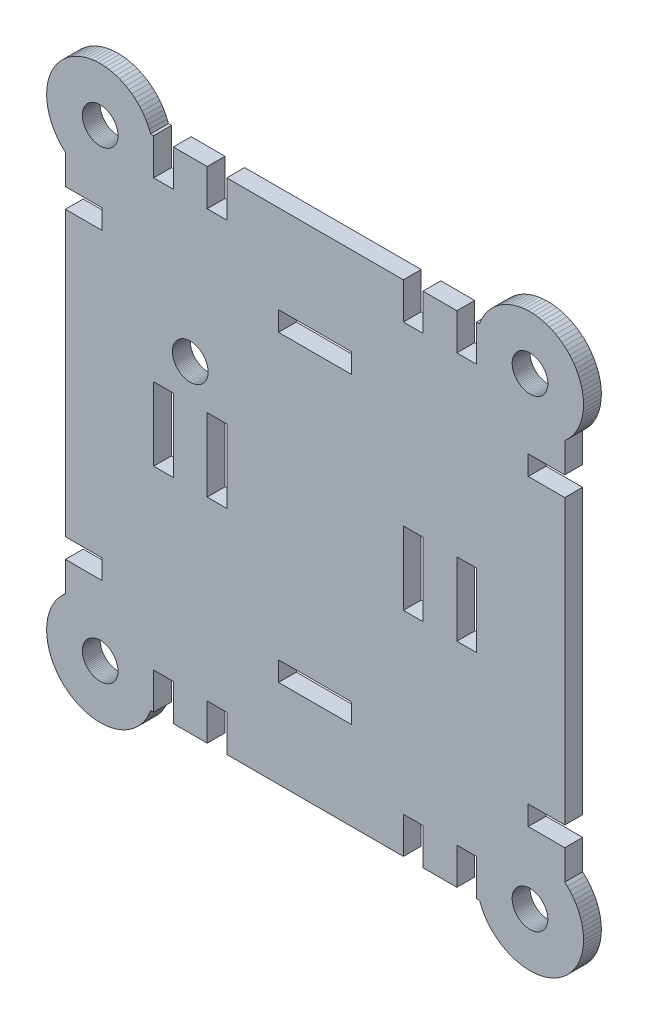
SolidWorks part; units mm, degrees
ref_plane "Front Plane" through (0, 0, 0) normal (0, 0, 1) x (1, 0, 0)
ref_plane "Top Plane" through (0, 0, 0) normal (0, 1, 0) x (1, 0, 0)
ref_plane "Right Plane" through (0, 0, 0) normal (1, 0, 0) x (0, 0, -1)
sketch "Model" plane through (0, 0, 0) normal (0, 0, 1) x (1, 0, 0)
  line L0 (-781.7485, -221.6197) -> (-782.7121, -221.8847)
  line L1 (-773.7963, -198.8692) -> (-773.2627, -199.7141)
  line L2 (-774.385, -198.0616) -> (-773.7963, -198.8692)
  line L3 (-920.0805, -214.084) -> (-920.5028, -213.1783)
  line L4 (-776.5249, -218.7556) -> (-777.3094, -219.3747)
  line L5 (-773.3098, -214.9597) -> (-773.8486, -215.8013)
  line L6 (-775.0262, -197.2951) -> (-774.385, -198.0616)
  line L7 (-786.6777, -222.2895) -> (-787.675, -222.2248)
  line L8 (-771.3318, -205.3498) -> (-771.2352, -206.3444)
  line L9 (-784.6814, -222.2194) -> (-785.6784, -222.2878)
  line L10 (-919.1124, -198.8692) -> (-918.5237, -198.0616)
  line L11 (-775.0882, -217.3677) -> (-775.7834, -218.0856)
  line L12 (-921.4142, -204.3638) -> (-921.1863, -203.3908)
  line L13 (-918.4664, -216.6052) -> (-919.0601, -215.8013)
  line L14 (-771.2049, -207.3433) -> (-771.2413, -208.342)
  line L15 (-920.5388, -201.501) -> (-920.1222, -200.5927)
  line L16 (-774.4423, -216.6052) -> (-775.0882, -217.3677)
  line L17 (-919.5989, -214.9597) -> (-920.0805, -214.084)
  line L18 (-785.6784, -222.2878) -> (-786.6777, -222.2895)
  line L19 (-787.675, -222.2248) -> (-788.6657, -222.0938)
  line L20 (-916.4543, -187.547) -> (-906.2043, -187.547)
  line L21 (-778.9931, -220.4496) -> (-779.8849, -220.9006)
  line L22 (-917.8825, -197.2951) -> (-917.1917, -196.573)
  line L23 (-779.8849, -220.9006) -> (-780.8047, -221.2912)
  line L24 (-771.3441, -209.336) -> (-771.5129, -210.321)
  line L25 (-921.1863, -203.3908) -> (-920.894, -202.4351)
  line L26 (-920.8637, -212.2464) -> (-921.1619, -211.2926)
  line L27 (-920.1222, -200.5927) -> (-919.646, -199.7141)
  line L28 (-771.4945, -204.3638) -> (-771.3318, -205.3498)
  line L29 (-921.6674, -208.342) -> (-921.7038, -207.3433)
  line L30 (-772.4059, -213.1783) -> (-772.8282, -214.084)
  line L31 (-787.675, -62.3692) -> (-786.6777, -62.3045)
  line L32 (-772.4059, -71.4157) -> (-772.045, -72.3476)
  line L33 (-772.3699, -201.501) -> (-772.0147, -202.4351)
  line L34 (-795.0571, -65.1876) -> (-794.2312, -64.625)
  line L35 (-793.3696, -64.1187) -> (-792.4762, -63.6709)
  line L36 (-791.555, -63.2836) -> (-790.61, -62.9584)
  line L37 (-771.7468, -211.2926) -> (-772.045, -212.2464)
  line L38 (-921.5646, -209.336) -> (-921.6674, -208.342)
  line L39 (-778.1333, -64.6538) -> (-777.3094, -65.2193)
  line L40 (-773.2627, -199.7141) -> (-772.7865, -200.5927)
  line L41 (-916.4543, -187.547) -> (-916.4543, -195.8984)
  line L42 (-771.2352, -206.3444) -> (-771.2049, -207.3433)
  line L43 (-771.7468, -73.3014) -> (-771.5129, -74.273)
  line L44 (-788.6657, -62.5002) -> (-787.675, -62.3692)
  line L45 (-796.5877, -66.4712) -> (-795.8438, -65.8039)
  line L46 (-773.2627, -84.8799) -> (-773.7963, -85.7248)
  line L47 (-771.5129, -74.273) -> (-771.3441, -75.258)
  line L48 (-779.8849, -63.6934) -> (-778.9931, -64.1444)
  line L49 (-794.2312, -64.625) -> (-793.3696, -64.1187)
  line L50 (-795.8438, -65.8039) -> (-795.0571, -65.1876)
  line L51 (-786.7044, -97.047) -> (-786.7044, -102.547)
  line L52 (-921.5769, -205.3498) -> (-921.4142, -204.3638)
  line L53 (-921.7038, -207.3433) -> (-921.6736, -206.3444)
  line L54 (-771.7224, -203.3908) -> (-771.4945, -204.3638)
  line L55 (-778.1333, -219.9402) -> (-778.9931, -220.4496)
  line L56 (-772.045, -212.2464) -> (-772.4059, -213.1783)
  line L57 (-783.6912, -222.0849) -> (-784.6814, -222.2194)
  line L58 (-919.0601, -215.8013) -> (-919.5989, -214.9597)
  line L59 (-917.1917, -196.573) -> (-916.4543, -195.8984)
  line L60 (-777.3094, -219.3747) -> (-778.1333, -219.9402)
  line L61 (-921.1619, -211.2926) -> (-921.3958, -210.321)
  line L62 (-780.8047, -221.2912) -> (-781.7485, -221.6197)
  line L63 (-772.7865, -200.5927) -> (-772.3699, -201.501)
  line L64 (-773.8486, -215.8013) -> (-774.4423, -216.6052)
  line L65 (-776.4544, -195.8984) -> (-775.717, -196.573)
  line L66 (-771.5129, -210.321) -> (-771.7468, -211.2926)
  line L67 (-775.7834, -218.0856) -> (-776.5249, -218.7556)
  line L68 (-775.0882, -67.2263) -> (-774.4423, -67.9888)
  line L69 (-789.6455, -62.6969) -> (-788.6657, -62.5002)
  line L70 (-772.8282, -214.084) -> (-773.3098, -214.9597)
  line L71 (-918.5237, -198.0616) -> (-917.8825, -197.2951)
  line L72 (-920.5028, -213.1783) -> (-920.8637, -212.2464)
  line L73 (-920.894, -202.4351) -> (-920.5388, -201.501)
  line L74 (-790.61, -62.9584) -> (-789.6455, -62.6969)
  line L75 (-771.2413, -76.252) -> (-771.2049, -77.2507)
  line L76 (-772.0147, -202.4351) -> (-771.7224, -203.3908)
  line L77 (-789.6455, -221.8971) -> (-790.61, -221.6356)
  line L78 (-771.2413, -208.342) -> (-771.3441, -209.336)
  line L79 (-919.646, -199.7141) -> (-919.1124, -198.8692)
  line L80 (-788.6657, -222.0938) -> (-789.6455, -221.8971)
  line L81 (-782.7121, -221.8847) -> (-783.6912, -222.0849)
  line L82 (-921.6736, -206.3444) -> (-921.5769, -205.3498)
  line L83 (-921.3958, -210.321) -> (-921.5646, -209.336)
  line L84 (-775.0262, -87.2989) -> (-775.717, -88.021)
  line L85 (-876.4543, -122.047) -> (-876.4651, -122.374)
  line L86 (-772.7865, -84.0013) -> (-773.2627, -84.8799)
  line L87 (-786.7044, -182.047) -> (-776.4544, -182.047)
  line L88 (-771.7224, -81.2032) -> (-772.0147, -82.1589)
  line L89 (-786.7044, -102.547) -> (-776.4544, -102.547)
  line L90 (-772.8282, -70.51) -> (-772.4059, -71.4157)
  line L91 (-776.5249, -65.8384) -> (-775.7834, -66.5084)
  line L92 (-799.0725, -69.5883) -> (-798.5306, -68.7486)
  line L93 (-771.4945, -80.2302) -> (-771.7224, -81.2032)
  line L94 (-798.5306, -68.7486) -> (-797.9341, -67.9468)
  line L95 (-772.045, -72.3476) -> (-771.7468, -73.3014)
  line L96 (-774.385, -86.5324) -> (-775.0262, -87.2989)
  line L97 (-771.2352, -78.2496) -> (-771.3318, -79.2442)
  line L98 (-776.4544, -88.6956) -> (-776.4544, -97.047)
  line L99 (-797.2855, -67.1866) -> (-796.5877, -66.4712)
  line L100 (-783.6912, -62.5091) -> (-782.7121, -62.7093)
  line L101 (-773.7963, -85.7248) -> (-774.385, -86.5324)
  line L102 (-780.8047, -63.3028) -> (-779.8849, -63.6934)
  line L103 (-786.7044, -187.547) -> (-786.7044, -182.047)
  line L104 (-773.3098, -69.6343) -> (-772.8282, -70.51)
  line L105 (-777.3094, -65.2193) -> (-776.5249, -65.8384)
  line L106 (-775.717, -88.021) -> (-776.4544, -88.6956)
  line L107 (-876.4971, -122.6996) -> (-876.5504, -123.0225)
  line L108 (-877.1242, -119.547) -> (-876.97, -119.8356)
  line L109 (-876.6247, -123.3411) -> (-876.7197, -123.6542)
  line L110 (-799.5572, -70.4622) -> (-799.0725, -69.5883)
  line L111 (-800.347, -72.297) -> (-799.9827, -71.3664)
  line L112 (-876.7043, -82.547) -> (-876.7043, -72.297)
  line L113 (-876.97, -119.8356) -> (-876.835, -120.1336)
  line L114 (-871.2043, -72.297) -> (-821.7044, -72.297)
  line L115 (-801.2044, -72.297) -> (-800.347, -72.297)
  line L116 (-905.4097, -72.4674) -> (-905.0966, -72.5624)
  line L117 (-778.9931, -64.1444) -> (-778.1333, -64.6538)
  line L118 (-771.2049, -77.2507) -> (-771.2352, -78.2496)
  line L119 (-876.5504, -123.0225) -> (-876.6247, -123.3411)
  line L120 (-836.2044, -97.047) -> (-856.7044, -97.047)
  line L121 (-856.7044, -102.547) -> (-836.2044, -102.547)
  line L122 (-877.6951, -118.7503) -> (-877.4876, -119.0032)
  line L123 (-876.5504, -121.0716) -> (-876.4971, -121.3944)
  line L124 (-776.4544, -182.047) -> (-776.4544, -102.547)
  line L125 (-771.3318, -79.2442) -> (-771.4945, -80.2302)
  line L126 (-776.4544, -195.8984) -> (-776.4544, -187.547)
  line L127 (-776.4544, -187.547) -> (-786.7044, -187.547)
  line L128 (-771.3441, -75.258) -> (-771.2413, -76.252)
  line L129 (-782.7121, -62.7093) -> (-781.7485, -62.9743)
  line L130 (-886.2043, -152.547) -> (-886.2043, -132.047)
  line L131 (-876.7197, -123.6542) -> (-876.835, -123.9604)
  line L132 (-801.2044, -82.547) -> (-806.7044, -82.547)
  line L133 (-886.2043, -82.547) -> (-891.7043, -82.547)
  line L134 (-891.7043, -132.047) -> (-891.7043, -152.547)
  line L135 (-781.7485, -62.9743) -> (-780.8047, -63.3028)
  line L136 (-876.6247, -120.7529) -> (-876.5504, -121.0716)
  line L137 (-772.3699, -83.093) -> (-772.7865, -84.0013)
  line L138 (-772.0147, -82.1589) -> (-772.3699, -83.093)
  line L139 (-786.6777, -62.3045) -> (-785.6784, -62.3062)
  line L140 (-792.4762, -63.6709) -> (-791.555, -63.2836)
  line L141 (-775.717, -196.573) -> (-775.0262, -197.2951)
  line L142 (-797.9341, -67.9468) -> (-797.2855, -67.1866)
  line L143 (-775.7834, -66.5084) -> (-775.0882, -67.2263)
  line L144 (-784.6814, -62.3746) -> (-783.6912, -62.5091)
  line L145 (-773.8486, -68.7927) -> (-773.3098, -69.6343)
  line L146 (-774.4423, -67.9888) -> (-773.8486, -68.7927)
  line L147 (-776.4544, -97.047) -> (-786.7044, -97.047)
  line L148 (-785.6784, -62.3062) -> (-784.6814, -62.3746)
  line L149 (-876.4651, -121.72) -> (-876.4543, -122.047)
  line L150 (-816.2044, -152.547) -> (-816.2044, -132.047)
  line L151 (-801.2044, -72.297) -> (-801.2044, -82.547)
  line L152 (-886.2043, -72.297) -> (-886.2043, -82.547)
  line L153 (-856.7044, -97.047) -> (-856.7044, -102.547)
  line L154 (-816.2044, -132.047) -> (-821.7044, -132.047)
  line L155 (-816.2044, -72.297) -> (-806.7044, -72.297)
  line L156 (-877.4876, -119.0032) -> (-877.297, -119.2692)
  line L157 (-821.7044, -152.547) -> (-816.2044, -152.547)
  line L158 (-816.2044, -72.297) -> (-816.2044, -82.547)
  line L159 (-799.9827, -71.3664) -> (-799.5572, -70.4622)
  line L160 (-871.2043, -82.547) -> (-876.7043, -82.547)
  line L161 (-886.2043, -132.047) -> (-891.7043, -132.047)
  line L162 (-806.7044, -152.547) -> (-801.2044, -152.547)
  line L163 (-871.2043, -72.297) -> (-871.2043, -82.547)
  line L164 (-886.2043, -72.297) -> (-876.7043, -72.297)
  line L165 (-878.1576, -118.2878) -> (-877.9188, -118.5115)
  line L166 (-877.9188, -118.5115) -> (-877.6951, -118.7503)
  line L167 (-876.4651, -122.374) -> (-876.4971, -122.6996)
  line L168 (-806.7044, -82.547) -> (-806.7044, -72.297)
  line L169 (-892.5617, -72.297) -> (-891.7043, -72.297)
  line L170 (-876.7197, -120.4398) -> (-876.6247, -120.7529)
  line L171 (-877.297, -119.2692) -> (-877.1242, -119.547)
  line L172 (-876.835, -120.1336) -> (-876.7197, -120.4398)
  line L173 (-892.926, -71.3664) -> (-892.5617, -72.297)
  line L174 (-891.7043, -152.547) -> (-886.2043, -152.547)
  line L175 (-836.2044, -102.547) -> (-836.2044, -97.047)
  line L176 (-878.4105, -118.0802) -> (-878.1576, -118.2878)
  line L177 (-821.7044, -82.547) -> (-821.7044, -72.297)
  line L178 (-801.2044, -132.047) -> (-806.7044, -132.047)
  line L179 (-891.7043, -82.547) -> (-891.7043, -72.297)
  line L180 (-876.4971, -121.3944) -> (-876.4651, -121.72)
  line L181 (-816.2044, -82.547) -> (-821.7044, -82.547)
  line L182 (-806.7044, -132.047) -> (-806.7044, -152.547)
  line L183 (-801.2044, -152.547) -> (-801.2044, -132.047)
  line L184 (-821.7044, -132.047) -> (-821.7044, -152.547)
  line L185 (-788.4163, -211.7814) -> (-788.7049, -211.6271)
  line L186 (-787.8121, -212.0316) -> (-788.1183, -211.9164)
  line L187 (-781.8747, -209.797) -> (-782.0475, -210.0748)
  line L188 (-790.1716, -210.3408) -> (-790.3622, -210.0748)
  line L189 (-782.4457, -204.0003) -> (-782.2381, -204.2532)
  line L190 (-906.0512, -72.3398) -> (-905.7284, -72.3931)
  line L191 (-782.2381, -210.3408) -> (-782.4457, -210.5937)
  line L192 (-781.4702, -205.6898) -> (-781.3752, -206.0029)
  line L193 (-906.3768, -72.3077) -> (-906.0512, -72.3398)
  line L194 (-784.9108, -212.1266) -> (-785.2294, -212.2009)
  line L195 (-783.9934, -211.7814) -> (-784.2915, -211.9164)
  line L196 (-790.8243, -209.2104) -> (-790.9395, -208.9042)
  line L197 (-906.7038, -72.297) -> (-906.3768, -72.3077)
  line L198 (-781.2156, -207.624) -> (-781.2477, -207.9496)
  line L199 (-789.5016, -211.0562) -> (-789.7404, -210.8325)
  line L200 (-787.499, -212.1266) -> (-787.8121, -212.0316)
  line L201 (-781.4702, -208.9042) -> (-781.5855, -209.2104)
  line L202 (-785.5522, -212.2542) -> (-785.8779, -212.2863)
  line L203 (-781.7205, -205.0856) -> (-781.5855, -205.3836)
  line L204 (-791.1088, -208.2724) -> (-791.1621, -207.9496)
  line L205 (-791.1621, -207.9496) -> (-791.1942, -207.624)
  line L206 (-785.2294, -212.2009) -> (-785.5522, -212.2542)
  line L207 (-785.8779, -212.2863) -> (-786.2049, -212.297)
  line L208 (-787.1803, -212.2009) -> (-787.499, -212.1266)
  line L209 (-788.9827, -211.4543) -> (-789.2487, -211.2638)
  line L210 (-788.7049, -211.6271) -> (-788.9827, -211.4543)
  line L211 (-781.8747, -204.797) -> (-781.7205, -205.0856)
  line L212 (-789.7404, -210.8325) -> (-789.9641, -210.5937)
  line L213 (-788.1183, -211.9164) -> (-788.4163, -211.7814)
  line L214 (-782.6693, -210.8325) -> (-782.9081, -211.0562)
  line L215 (-782.2381, -204.2532) -> (-782.0475, -204.5191)
  line L216 (-786.5319, -212.2863) -> (-786.8575, -212.2542)
  line L217 (-784.2915, -211.9164) -> (-784.5977, -212.0316)
  line L218 (-786.2049, -212.297) -> (-786.5319, -212.2863)
  line L219 (-782.4457, -210.5937) -> (-782.6693, -210.8325)
  line L220 (-781.2477, -207.9496) -> (-781.3009, -208.2724)
  line L221 (-781.5855, -205.3836) -> (-781.4702, -205.6898)
  line L222 (-905.7284, -72.3931) -> (-905.4097, -72.4674)
  line L223 (-781.3009, -206.3215) -> (-781.2477, -206.6444)
  line L224 (-791.0345, -208.5911) -> (-791.1088, -208.2724)
  line L225 (-782.0475, -210.0748) -> (-782.2381, -210.3408)
  line L226 (-781.3752, -206.0029) -> (-781.3009, -206.3215)
  line L227 (-790.3622, -210.0748) -> (-790.535, -209.797)
  line L228 (-781.3009, -208.2724) -> (-781.3752, -208.5911)
  line L229 (-781.5855, -209.2104) -> (-781.7205, -209.5084)
  line L230 (-789.2487, -211.2638) -> (-789.5016, -211.0562)
  line L231 (-786.8575, -212.2542) -> (-787.1803, -212.2009)
  line L232 (-783.7049, -211.6271) -> (-783.9934, -211.7814)
  line L233 (-782.9081, -211.0562) -> (-783.1611, -211.2638)
  line L234 (-784.5977, -212.0316) -> (-784.9108, -212.1266)
  line L235 (-783.1611, -211.2638) -> (-783.427, -211.4543)
  line L236 (-783.427, -211.4543) -> (-783.7049, -211.6271)
  line L237 (-789.9641, -210.5937) -> (-790.1716, -210.3408)
  line L238 (-781.2156, -206.97) -> (-781.2049, -207.297)
  line L239 (-781.7205, -209.5084) -> (-781.8747, -209.797)
  line L240 (-790.535, -209.797) -> (-790.6892, -209.5084)
  line L241 (-782.0475, -204.5191) -> (-781.8747, -204.797)
  line L242 (-790.9395, -208.9042) -> (-791.0345, -208.5911)
  line L243 (-781.2049, -207.297) -> (-781.2156, -207.624)
  line L244 (-781.2477, -206.6444) -> (-781.2156, -206.97)
  line L245 (-790.6892, -209.5084) -> (-790.8243, -209.2104)
  line L246 (-781.3752, -208.5911) -> (-781.4702, -208.9042)
  line L247 (-791.1942, -207.624) -> (-791.2049, -207.297)
  line L248 (-878.4105, -126.0138) -> (-878.6765, -126.2044)
  line L249 (-878.9543, -126.3771) -> (-879.2429, -126.5314)
  line L250 (-907.0308, -72.3077) -> (-906.7038, -72.297)
  line L251 (-884.9899, -118.5115) -> (-884.7511, -118.2878)
  line L252 (-885.7845, -119.547) -> (-885.6117, -119.2692)
  line L253 (-886.284, -123.3411) -> (-886.3583, -123.0225)
  line L254 (-886.4436, -121.72) -> (-886.4116, -121.3944)
  line L255 (-885.6117, -119.2692) -> (-885.4211, -119.0032)
  line L256 (-881.4543, -127.047) -> (-881.7814, -127.0363)
  line L257 (-886.3583, -121.0716) -> (-886.284, -120.7529)
  line L258 (-882.4298, -117.1431) -> (-882.107, -117.0898)
  line L259 (-884.4982, -126.0138) -> (-884.7511, -125.8062)
  line L260 (-876.835, -123.9604) -> (-876.97, -124.2584)
  line L261 (-886.3583, -123.0225) -> (-886.4116, -122.6996)
  line L262 (-884.7511, -125.8062) -> (-884.9899, -125.5825)
  line L263 (-882.107, -127.0042) -> (-882.4298, -126.9509)
  line L264 (-885.9387, -124.2584) -> (-886.0737, -123.9604)
  line L265 (-886.4436, -122.374) -> (-886.4543, -122.047)
  line L266 (-883.0615, -117.3124) -> (-882.7484, -117.2174)
  line L267 (-877.4876, -125.0908) -> (-877.6951, -125.3437)
  line L268 (-883.6658, -126.5314) -> (-883.9543, -126.3771)
  line L269 (-879.2429, -126.5314) -> (-879.5409, -126.6664)
  line L270 (-882.7484, -126.8766) -> (-883.0615, -126.7817)
  line L271 (-879.8472, -126.7817) -> (-880.1603, -126.8766)
  line L272 (-885.9387, -119.8356) -> (-885.7845, -119.547)
  line L273 (-885.2135, -125.3437) -> (-885.4211, -125.0908)
  line L274 (-885.4211, -125.0908) -> (-885.6117, -124.8249)
  line L275 (-884.2322, -126.2044) -> (-884.4982, -126.0138)
  line L276 (-885.7845, -124.547) -> (-885.9387, -124.2584)
  line L277 (-886.189, -123.6542) -> (-886.284, -123.3411)
  line L278 (-883.0615, -126.7817) -> (-883.3678, -126.6664)
  line L279 (-885.6117, -124.8249) -> (-885.7845, -124.547)
  line L280 (-886.4116, -122.6996) -> (-886.4436, -122.374)
  line L281 (-879.5409, -126.6664) -> (-879.8472, -126.7817)
  line L282 (-880.1603, -126.8766) -> (-880.4789, -126.9509)
  line L283 (-886.4543, -122.047) -> (-886.4436, -121.72)
  line L284 (-881.1273, -127.0363) -> (-881.4543, -127.047)
  line L285 (-883.3678, -117.4276) -> (-883.0615, -117.3124)
  line L286 (-884.2322, -117.8897) -> (-883.9543, -117.7169)
  line L287 (-881.7814, -127.0363) -> (-882.107, -127.0042)
  line L288 (-883.6658, -117.5626) -> (-883.3678, -117.4276)
  line L289 (-883.9543, -117.7169) -> (-883.6658, -117.5626)
  line L290 (-880.8017, -127.0042) -> (-881.1273, -127.0363)
  line L291 (-886.4116, -121.3944) -> (-886.3583, -121.0716)
  line L292 (-886.284, -120.7529) -> (-886.189, -120.4398)
  line L293 (-877.6951, -125.3437) -> (-877.9188, -125.5825)
  line L294 (-883.3678, -126.6664) -> (-883.6658, -126.5314)
  line L295 (-886.189, -120.4398) -> (-886.0737, -120.1336)
  line L296 (-882.7484, -117.2174) -> (-882.4298, -117.1431)
  line L297 (-877.1242, -124.547) -> (-877.297, -124.8249)
  line L298 (-886.0737, -123.9604) -> (-886.189, -123.6542)
  line L299 (-886.0737, -120.1336) -> (-885.9387, -119.8356)
  line L300 (-885.2135, -118.7503) -> (-884.9899, -118.5115)
  line L301 (-878.6765, -126.2044) -> (-878.9543, -126.3771)
  line L302 (-884.7511, -118.2878) -> (-884.4982, -118.0802)
  line L303 (-878.1576, -125.8062) -> (-878.4105, -126.0138)
  line L304 (-884.4982, -118.0802) -> (-884.2322, -117.8897)
  line L305 (-877.297, -124.8249) -> (-877.4876, -125.0908)
  line L306 (-876.97, -124.2584) -> (-877.1242, -124.547)
  line L307 (-885.4211, -119.0032) -> (-885.2135, -118.7503)
  line L308 (-884.9899, -125.5825) -> (-885.2135, -125.3437)
  line L309 (-880.4789, -126.9509) -> (-880.8017, -127.0042)
  line L310 (-882.4298, -126.9509) -> (-882.7484, -126.8766)
  line L311 (-871.2043, -152.547) -> (-871.2043, -132.047)
  line L312 (-786.8575, -202.3398) -> (-786.5319, -202.3077)
  line L313 (-791.0345, -206.0029) -> (-790.9395, -205.6898)
  line L314 (-880.4789, -117.1431) -> (-880.1603, -117.2174)
  line L315 (-786.5319, -202.3077) -> (-786.2049, -202.297)
  line L316 (-785.8779, -202.3077) -> (-785.5522, -202.3398)
  line L317 (-788.4163, -202.8126) -> (-788.1183, -202.6776)
  line L318 (-782.6693, -203.7615) -> (-782.4457, -204.0003)
  line L319 (-789.2487, -203.3302) -> (-788.9827, -203.1396)
  line L320 (-836.2044, -182.047) -> (-836.2044, -187.547)
  line L321 (-790.3622, -204.5191) -> (-790.1716, -204.2532)
  line L322 (-790.1716, -204.2532) -> (-789.9641, -204.0003)
  line L323 (-791.1088, -206.3215) -> (-791.0345, -206.0029)
  line L324 (-784.2915, -202.6776) -> (-783.9934, -202.8126)
  line L325 (-787.1803, -202.3931) -> (-786.8575, -202.3398)
  line L326 (-785.5522, -202.3398) -> (-785.2294, -202.3931)
  line L327 (-881.4543, -117.047) -> (-881.1273, -117.0577)
  line L328 (-790.9395, -205.6898) -> (-790.8243, -205.3836)
  line L329 (-856.7044, -182.047) -> (-836.2044, -182.047)
  line L330 (-790.535, -204.797) -> (-790.3622, -204.5191)
  line L331 (-783.7049, -202.9669) -> (-783.427, -203.1396)
  line L332 (-783.1611, -203.3302) -> (-782.9081, -203.5378)
  line L333 (-880.1603, -117.2174) -> (-879.8472, -117.3124)
  line L334 (-878.9543, -117.7169) -> (-878.6765, -117.8897)
  line L335 (-876.7043, -152.547) -> (-871.2043, -152.547)
  line L336 (-783.427, -203.1396) -> (-783.1611, -203.3302)
  line L337 (-790.8243, -205.3836) -> (-790.6892, -205.0856)
  line L338 (-877.9188, -125.5825) -> (-878.1576, -125.8062)
  line L339 (-788.9827, -203.1396) -> (-788.7049, -202.9669)
  line L340 (-836.2044, -187.547) -> (-856.7044, -187.547)
  line L341 (-789.7404, -203.7615) -> (-789.5016, -203.5378)
  line L342 (-787.499, -202.4674) -> (-787.1803, -202.3931)
  line L343 (-876.7043, -132.047) -> (-876.7043, -152.547)
  line L344 (-879.2429, -117.5626) -> (-878.9543, -117.7169)
  line L345 (-782.9081, -203.5378) -> (-782.6693, -203.7615)
  line L346 (-791.2049, -207.297) -> (-791.1942, -206.97)
  line L347 (-881.1273, -117.0577) -> (-880.8017, -117.0898)
  line L348 (-883.9543, -126.3771) -> (-884.2322, -126.2044)
  line L349 (-785.2294, -202.3931) -> (-784.9108, -202.4674)
  line L350 (-788.7049, -202.9669) -> (-788.4163, -202.8126)
  line L351 (-791.1942, -206.97) -> (-791.1621, -206.6444)
  line L352 (-856.7044, -187.547) -> (-856.7044, -182.047)
  line L353 (-880.8017, -117.0898) -> (-880.4789, -117.1431)
  line L354 (-783.9934, -202.8126) -> (-783.7049, -202.9669)
  line L355 (-878.6765, -117.8897) -> (-878.4105, -118.0802)
  line L356 (-790.6892, -205.0856) -> (-790.535, -204.797)
  line L357 (-787.8121, -202.5623) -> (-787.499, -202.4674)
  line L358 (-879.8472, -117.3124) -> (-879.5409, -117.4276)
  line L359 (-871.2043, -132.047) -> (-876.7043, -132.047)
  line L360 (-791.1621, -206.6444) -> (-791.1088, -206.3215)
  line L361 (-789.5016, -203.5378) -> (-789.2487, -203.3302)
  line L362 (-784.9108, -202.4674) -> (-784.5977, -202.5623)
  line L363 (-789.9641, -204.0003) -> (-789.7404, -203.7615)
  line L364 (-881.7814, -117.0577) -> (-881.4543, -117.047)
  line L365 (-784.5977, -202.5623) -> (-784.2915, -202.6776)
  line L366 (-786.2049, -202.297) -> (-785.8779, -202.3077)
  line L367 (-788.1183, -202.6776) -> (-787.8121, -202.5623)
  line L368 (-882.107, -117.0898) -> (-881.7814, -117.0577)
  line L369 (-879.5409, -117.4276) -> (-879.2429, -117.5626)
  line L370 (-901.8742, -208.5911) -> (-901.9692, -208.9042)
  line L371 (-902.3737, -209.797) -> (-902.5465, -210.0748)
  line L372 (-901.7999, -208.2724) -> (-901.8742, -208.5911)
  line L373 (-911.1882, -209.5084) -> (-911.3232, -209.2104)
  line L374 (-904.4924, -211.7814) -> (-904.7904, -211.9164)
  line L375 (-901.7466, -206.6444) -> (-901.7145, -206.97)
  line L376 (-903.66, -211.2638) -> (-903.926, -211.4543)
  line L377 (-907.3565, -212.2542) -> (-907.6793, -212.2009)
  line L378 (-901.7038, -207.297) -> (-901.7145, -207.624)
  line L379 (-902.2195, -209.5084) -> (-902.3737, -209.797)
  line L380 (-902.7371, -210.3408) -> (-902.9446, -210.5937)
  line L381 (-906.7038, -212.297) -> (-907.0308, -212.2863)
  line L382 (-910.8612, -210.0748) -> (-911.034, -209.797)
  line L383 (-908.6172, -211.9164) -> (-908.9153, -211.7814)
  line L384 (-906.0512, -212.2542) -> (-906.3768, -212.2863)
  line L385 (-902.5465, -210.0748) -> (-902.7371, -210.3408)
  line L386 (-904.7904, -211.9164) -> (-905.0966, -212.0316)
  line L387 (-906.3768, -212.2863) -> (-906.7038, -212.297)
  line L388 (-910.463, -210.5937) -> (-910.6706, -210.3408)
  line L389 (-911.5335, -208.5911) -> (-911.6078, -208.2724)
  line L390 (-907.6793, -212.2009) -> (-907.9979, -212.1266)
  line L391 (-905.7284, -212.2009) -> (-906.0512, -212.2542)
  line L392 (-909.4817, -211.4543) -> (-909.7476, -211.2638)
  line L393 (-911.6611, -207.9496) -> (-911.6931, -207.624)
  line L394 (-902.0844, -209.2104) -> (-902.2195, -209.5084)
  line L395 (-907.0308, -212.2863) -> (-907.3565, -212.2542)
  line L396 (-910.463, -204.0003) -> (-910.2394, -203.7615)
  line L397 (-911.6611, -206.6444) -> (-911.6078, -206.3215)
  line L398 (-910.0006, -211.0562) -> (-910.2394, -210.8325)
  line L399 (-909.2038, -211.6271) -> (-909.4817, -211.4543)
  line L400 (-901.7145, -206.97) -> (-901.7038, -207.297)
  line L401 (-905.4097, -212.1266) -> (-905.7284, -212.2009)
  line L402 (-901.7145, -207.624) -> (-901.7466, -207.9496)
  line L403 (-904.2038, -211.6271) -> (-904.4924, -211.7814)
  line L404 (-911.6078, -206.3215) -> (-911.5335, -206.0029)
  line L405 (-911.3232, -209.2104) -> (-911.4385, -208.9042)
  line L406 (-901.7466, -207.9496) -> (-901.7999, -208.2724)
  line L407 (-903.926, -211.4543) -> (-904.2038, -211.6271)
  line L408 (-910.6706, -210.3408) -> (-910.8612, -210.0748)
  line L409 (-909.7476, -211.2638) -> (-910.0006, -211.0562)
  line L410 (-911.1882, -205.0856) -> (-911.034, -204.797)
  line L411 (-911.034, -204.797) -> (-910.8612, -204.5191)
  line L412 (-908.9153, -211.7814) -> (-909.2038, -211.6271)
  line L413 (-904.7904, -72.6776) -> (-904.4924, -72.8126)
  line L414 (-902.5465, -74.5192) -> (-902.3737, -74.797)
  line L415 (-910.8612, -80.0749) -> (-911.034, -79.797)
  line L416 (-902.3737, -74.797) -> (-902.2195, -75.0856)
  line L417 (-911.5335, -206.0029) -> (-911.4385, -205.6898)
  line L418 (-911.6078, -208.2724) -> (-911.6611, -207.9496)
  line L419 (-910.6706, -80.3408) -> (-910.8612, -80.0749)
  line L420 (-911.6931, -207.624) -> (-911.7038, -207.297)
  line L421 (-902.7371, -80.3408) -> (-902.9446, -80.5937)
  line L422 (-911.034, -79.797) -> (-911.1882, -79.5085)
  line L423 (-911.4385, -78.9042) -> (-911.5335, -78.5911)
  line L424 (-905.4097, -82.1266) -> (-905.7284, -82.2009)
  line L425 (-904.7904, -81.9164) -> (-905.0966, -82.0317)
  line L426 (-904.4924, -81.7814) -> (-904.7904, -81.9164)
  line L427 (-902.7371, -74.2532) -> (-902.5465, -74.5192)
  line L428 (-910.8612, -204.5191) -> (-910.6706, -204.2532)
  line L429 (-902.5465, -80.0749) -> (-902.7371, -80.3408)
  line L430 (-903.926, -73.1397) -> (-903.66, -73.3302)
  line L431 (-903.4071, -73.5378) -> (-903.1683, -73.7615)
  line L432 (-907.0308, -82.2863) -> (-907.3565, -82.2542)
  line L433 (-902.0844, -79.2104) -> (-902.2195, -79.5085)
  line L434 (-902.9446, -80.5937) -> (-903.1683, -80.8325)
  line L435 (-908.9153, -81.7814) -> (-909.2038, -81.6271)
  line L436 (-905.0966, -212.0316) -> (-905.4097, -212.1266)
  line L437 (-906.7038, -82.297) -> (-907.0308, -82.2863)
  line L438 (-902.9446, -210.5937) -> (-903.1683, -210.8325)
  line L439 (-901.9692, -75.6898) -> (-901.8742, -76.0029)
  line L440 (-901.7999, -76.3216) -> (-901.7466, -76.6444)
  line L441 (-910.2394, -203.7615) -> (-910.0006, -203.5378)
  line L442 (-910.0006, -203.5378) -> (-909.7476, -203.3302)
  line L443 (-901.7466, -77.9496) -> (-901.7999, -78.2725)
  line L444 (-911.3232, -205.3836) -> (-911.1882, -205.0856)
  line L445 (-908.311, -82.0317) -> (-908.6172, -81.9164)
  line L446 (-911.3232, -79.2104) -> (-911.4385, -78.9042)
  line L447 (-911.4385, -205.6898) -> (-911.3232, -205.3836)
  line L448 (-911.5335, -78.5911) -> (-911.6078, -78.2725)
  line L449 (-910.2394, -210.8325) -> (-910.463, -210.5937)
  line L450 (-910.463, -80.5937) -> (-910.6706, -80.3408)
  line L451 (-908.311, -212.0316) -> (-908.6172, -211.9164)
  line L452 (-904.2038, -72.9669) -> (-903.926, -73.1397)
  line L453 (-911.1882, -79.5085) -> (-911.3232, -79.2104)
  line L454 (-902.0844, -75.3836) -> (-901.9692, -75.6898)
  line L455 (-903.4071, -211.0562) -> (-903.66, -211.2638)
  line L456 (-901.9692, -78.9042) -> (-902.0844, -79.2104)
  line L457 (-905.7284, -82.2009) -> (-906.0512, -82.2542)
  line L458 (-906.3768, -82.2863) -> (-906.7038, -82.297)
  line L459 (-911.034, -209.797) -> (-911.1882, -209.5084)
  line L460 (-911.4385, -208.9042) -> (-911.5335, -208.5911)
  line L461 (-910.0006, -81.0562) -> (-910.2394, -80.8325)
  line L462 (-901.7145, -77.624) -> (-901.7466, -77.9496)
  line L463 (-901.7466, -76.6444) -> (-901.7145, -76.97)
  line L464 (-910.6706, -204.2532) -> (-910.463, -204.0003)
  line L465 (-901.9692, -208.9042) -> (-902.0844, -209.2104)
  line L466 (-908.6172, -81.9164) -> (-908.9153, -81.7814)
  line L467 (-902.2195, -79.5085) -> (-902.3737, -79.797)
  line L468 (-907.9979, -212.1266) -> (-908.311, -212.0316)
  line L469 (-911.7038, -207.297) -> (-911.6931, -206.97)
  line L470 (-901.7145, -76.97) -> (-901.7038, -77.297)
  line L471 (-911.6931, -206.97) -> (-911.6611, -206.6444)
  line L472 (-904.4924, -72.8126) -> (-904.2038, -72.9669)
  line L473 (-906.0512, -82.2542) -> (-906.3768, -82.2863)
  line L474 (-907.3565, -82.2542) -> (-907.6793, -82.2009)
  line L475 (-901.8742, -76.0029) -> (-901.7999, -76.3216)
  line L476 (-903.1683, -210.8325) -> (-903.4071, -211.0562)
  line L477 (-901.8742, -78.5911) -> (-901.9692, -78.9042)
  line L478 (-907.6793, -82.2009) -> (-907.9979, -82.1266)
  line L479 (-911.6931, -77.624) -> (-911.7038, -77.297)
  line L480 (-908.311, -72.5624) -> (-907.9979, -72.4674)
  line L481 (-904.2038, -81.6271) -> (-904.4924, -81.7814)
  line L482 (-902.9446, -74.0003) -> (-902.7371, -74.2532)
  line L483 (-911.3232, -75.3836) -> (-911.1882, -75.0856)
  line L484 (-908.6172, -72.6776) -> (-908.311, -72.5624)
  line L485 (-902.5465, -204.5191) -> (-902.3737, -204.797)
  line L486 (-909.7476, -81.2638) -> (-910.0006, -81.0562)
  line L487 (-901.7038, -77.297) -> (-901.7145, -77.624)
  line L488 (-910.2394, -80.8325) -> (-910.463, -80.5937)
  line L489 (-907.6793, -202.3931) -> (-907.3565, -202.3398)
  line L490 (-911.034, -74.797) -> (-910.8612, -74.5192)
  line L491 (-906.0512, -202.3398) -> (-905.7284, -202.3931)
  line L492 (-902.3737, -79.797) -> (-902.5465, -80.0749)
  line L493 (-903.4071, -81.0562) -> (-903.66, -81.2638)
  line L494 (-902.9446, -204.0003) -> (-902.7371, -204.2532)
  line L495 (-907.3565, -202.3398) -> (-907.0308, -202.3077)
  line L496 (-907.3565, -72.3398) -> (-907.0308, -72.3077)
  line L497 (-901.9692, -205.6898) -> (-901.8742, -206.0029)
  line L498 (-901.7999, -206.3215) -> (-901.7466, -206.6444)
  line L499 (-904.4924, -202.8126) -> (-904.2038, -202.9669)
  line L500 (-911.7038, -77.297) -> (-911.6931, -76.97)
  line L501 (-911.6611, -77.9496) -> (-911.6931, -77.624)
  line L502 (-905.0966, -82.0317) -> (-905.4097, -82.1266)
  line L503 (-908.6172, -202.6776) -> (-908.311, -202.5623)
  line L504 (-902.7371, -204.2532) -> (-902.5465, -204.5191)
  line L505 (-903.926, -81.4544) -> (-904.2038, -81.6271)
  line L506 (-911.6078, -76.3216) -> (-911.5335, -76.0029)
  line L507 (-910.6706, -74.2532) -> (-910.463, -74.0003)
  line L508 (-902.3737, -204.797) -> (-902.2195, -205.0856)
  line L509 (-903.66, -81.2638) -> (-903.926, -81.4544)
  line L510 (-910.463, -74.0003) -> (-910.2394, -73.7615)
  line L511 (-909.2038, -72.9669) -> (-908.9153, -72.8126)
  line L512 (-902.0844, -205.3836) -> (-901.9692, -205.6898)
  line L513 (-911.6931, -76.97) -> (-911.6611, -76.6444)
  line L514 (-905.4097, -202.4674) -> (-905.0966, -202.5623)
  line L515 (-903.926, -203.1396) -> (-903.66, -203.3302)
  line L516 (-903.66, -73.3302) -> (-903.4071, -73.5378)
  line L517 (-908.9153, -72.8126) -> (-908.6172, -72.6776)
  line L518 (-903.66, -203.3302) -> (-903.4071, -203.5378)
  line L519 (-906.7038, -202.297) -> (-906.3768, -202.3077)
  line L520 (-909.2038, -81.6271) -> (-909.4817, -81.4544)
  line L521 (-901.7999, -78.2725) -> (-901.8742, -78.5911)
  line L522 (-901.8742, -206.0029) -> (-901.7999, -206.3215)
  line L523 (-911.6611, -76.6444) -> (-911.6078, -76.3216)
  line L524 (-907.9979, -82.1266) -> (-908.311, -82.0317)
  line L525 (-910.8612, -74.5192) -> (-910.6706, -74.2532)
  line L526 (-907.6793, -72.3931) -> (-907.3565, -72.3398)
  line L527 (-911.4385, -75.6898) -> (-911.3232, -75.3836)
  line L528 (-907.9979, -72.4674) -> (-907.6793, -72.3931)
  line L529 (-903.1683, -73.7615) -> (-902.9446, -74.0003)
  line L530 (-902.2195, -75.0856) -> (-902.0844, -75.3836)
  line L531 (-910.2394, -73.7615) -> (-910.0006, -73.5378)
  line L532 (-907.0308, -202.3077) -> (-906.7038, -202.297)
  line L533 (-903.1683, -80.8325) -> (-903.4071, -81.0562)
  line L534 (-909.4817, -81.4544) -> (-909.7476, -81.2638)
  line L535 (-903.1683, -203.7615) -> (-902.9446, -204.0003)
  line L536 (-906.3768, -202.3077) -> (-906.0512, -202.3398)
  line L537 (-909.4817, -73.1397) -> (-909.2038, -72.9669)
  line L538 (-905.0966, -72.5624) -> (-904.7904, -72.6776)
  line L539 (-905.7284, -202.3931) -> (-905.4097, -202.4674)
  line L540 (-902.2195, -205.0856) -> (-902.0844, -205.3836)
  line L541 (-904.7904, -202.6776) -> (-904.4924, -202.8126)
  line L542 (-908.9153, -202.8126) -> (-908.6172, -202.6776)
  line L543 (-911.6078, -78.2725) -> (-911.6611, -77.9496)
  line L544 (-911.1882, -75.0856) -> (-911.034, -74.797)
  line L545 (-909.7476, -73.3302) -> (-909.4817, -73.1397)
  line L546 (-908.311, -202.5623) -> (-907.9979, -202.4674)
  line L547 (-905.0966, -202.5623) -> (-904.7904, -202.6776)
  line L548 (-910.0006, -73.5378) -> (-909.7476, -73.3302)
  line L549 (-909.4817, -203.1396) -> (-909.2038, -202.9669)
  line L550 (-904.2038, -202.9669) -> (-903.926, -203.1396)
  line L551 (-909.2038, -202.9669) -> (-908.9153, -202.8126)
  line L552 (-903.4071, -203.5378) -> (-903.1683, -203.7615)
  line L553 (-907.9979, -202.4674) -> (-907.6793, -202.3931)
  line L554 (-911.5335, -76.0029) -> (-911.4385, -75.6898)
  line L555 (-892.5617, -212.297) -> (-892.926, -213.2276)
  line L556 (-876.7043, -202.047) -> (-876.7043, -212.297)
  line L557 (-895.6232, -217.4074) -> (-896.321, -218.1228)
  line L558 (-801.2044, -212.297) -> (-801.2044, -202.047)
  line L559 (-893.8362, -215.0057) -> (-894.3781, -215.8454)
  line L560 (-795.0571, -219.4064) -> (-795.8438, -218.7901)
  line L561 (-871.2043, -212.297) -> (-821.7044, -212.297)
  line L562 (-915.5993, -219.3747) -> (-916.3838, -218.7556)
  line L563 (-904.243, -222.0938) -> (-905.2337, -222.2248)
  line L564 (-816.2044, -212.297) -> (-806.7044, -212.297)
  line L565 (-914.7754, -64.6538) -> (-913.9156, -64.1444)
  line L566 (-901.3537, -221.3104) -> (-902.2987, -221.6356)
  line L567 (-797.9341, -216.6472) -> (-798.5306, -215.8454)
  line L568 (-816.2044, -212.297) -> (-816.2044, -202.047)
  line L569 (-799.9827, -213.2276) -> (-800.347, -212.297)
  line L570 (-886.2043, -212.297) -> (-886.2043, -202.047)
  line L571 (-914.7754, -219.9402) -> (-915.5993, -219.3747)
  line L572 (-892.5617, -212.297) -> (-891.7043, -212.297)
  line L573 (-907.2303, -222.2878) -> (-908.2273, -222.2194)
  line L574 (-908.2273, -222.2194) -> (-909.2175, -222.0849)
  line L575 (-886.2043, -212.297) -> (-876.7043, -212.297)
  line L576 (-799.5572, -214.1318) -> (-799.9827, -213.2276)
  line L577 (-891.7043, -202.047) -> (-891.7043, -212.297)
  line L578 (-905.2337, -222.2248) -> (-906.231, -222.2895)
  line L579 (-816.2044, -202.047) -> (-821.7044, -202.047)
  line L580 (-796.5877, -218.1228) -> (-797.2855, -217.4074)
  line L581 (-793.3696, -220.4753) -> (-794.2312, -219.969)
  line L582 (-917.8205, -217.3677) -> (-918.4664, -216.6052)
  line L583 (-903.2632, -221.8971) -> (-904.243, -222.0938)
  line L584 (-911.1602, -62.9743) -> (-910.1966, -62.7093)
  line L585 (-791.555, -221.3104) -> (-792.4762, -220.9231)
  line L586 (-871.2043, -212.297) -> (-871.2043, -202.047)
  line L587 (-913.0238, -220.9006) -> (-913.9156, -220.4496)
  line L588 (-886.2043, -202.047) -> (-891.7043, -202.047)
  line L589 (-913.9156, -220.4496) -> (-914.7754, -219.9402)
  line L590 (-893.3515, -214.1318) -> (-893.8362, -215.0057)
  line L591 (-795.8438, -218.7901) -> (-796.5877, -218.1228)
  line L592 (-792.4762, -220.9231) -> (-793.3696, -220.4753)
  line L593 (-909.2175, -222.0849) -> (-910.1966, -221.8847)
  line L594 (-906.231, -222.2895) -> (-907.2303, -222.2878)
  line L595 (-921.5646, -75.258) -> (-921.3958, -74.273)
  line L596 (-898.6775, -219.969) -> (-899.5391, -220.4753)
  line L597 (-900.4325, -220.9231) -> (-901.3537, -221.3104)
  line L598 (-911.1602, -221.6197) -> (-912.104, -221.2912)
  line L599 (-798.5306, -215.8454) -> (-799.0725, -215.0057)
  line L600 (-897.8516, -219.4064) -> (-898.6775, -219.969)
  line L601 (-896.321, -66.4712) -> (-895.6232, -67.1866)
  line L602 (-916.3838, -218.7556) -> (-917.1253, -218.0856)
  line L603 (-799.0725, -215.0057) -> (-799.5572, -214.1318)
  line L604 (-897.0649, -218.7901) -> (-897.8516, -219.4064)
  line L605 (-912.104, -221.2912) -> (-913.0238, -220.9006)
  line L606 (-801.2044, -212.297) -> (-800.347, -212.297)
  line L607 (-899.5391, -220.4753) -> (-900.4325, -220.9231)
  line L608 (-801.2044, -202.047) -> (-806.7044, -202.047)
  line L609 (-821.7044, -202.047) -> (-821.7044, -212.297)
  line L610 (-896.321, -218.1228) -> (-897.0649, -218.7901)
  line L611 (-902.2987, -221.6356) -> (-903.2632, -221.8971)
  line L612 (-894.9746, -216.6472) -> (-895.6232, -217.4074)
  line L613 (-790.61, -221.6356) -> (-791.555, -221.3104)
  line L614 (-910.1966, -221.8847) -> (-911.1602, -221.6197)
  line L615 (-892.926, -213.2276) -> (-893.3515, -214.1318)
  line L616 (-797.2855, -217.4074) -> (-797.9341, -216.6472)
  line L617 (-917.1253, -218.0856) -> (-917.8205, -217.3677)
  line L618 (-871.2043, -202.047) -> (-876.7043, -202.047)
  line L619 (-794.2312, -219.969) -> (-795.0571, -219.4064)
  line L620 (-904.243, -62.5002) -> (-903.2632, -62.6969)
  line L621 (-921.3958, -74.273) -> (-921.1619, -73.3014)
  line L622 (-901.3537, -63.2836) -> (-900.4325, -63.6709)
  line L623 (-921.5769, -79.2442) -> (-921.6736, -78.2496)
  line L624 (-894.9746, -67.9468) -> (-894.3781, -68.7486)
  line L625 (-902.2987, -62.9584) -> (-901.3537, -63.2836)
  line L626 (-893.3515, -70.4622) -> (-892.926, -71.3664)
  line L627 (-919.5989, -69.6343) -> (-919.0601, -68.7927)
  line L628 (-897.8516, -65.1876) -> (-897.0649, -65.8039)
  line L629 (-907.2303, -62.3062) -> (-906.231, -62.3045)
  line L630 (-903.2632, -62.6969) -> (-902.2987, -62.9584)
  line L631 (-912.104, -63.3028) -> (-911.1602, -62.9743)
  line L632 (-921.4142, -80.2302) -> (-921.5769, -79.2442)
  line L633 (-893.8362, -69.5883) -> (-893.3515, -70.4622)
  line L634 (-921.6674, -76.252) -> (-921.5646, -75.258)
  line L635 (-919.646, -84.8799) -> (-920.1222, -84.0013)
  line L636 (-918.5237, -86.5324) -> (-919.1124, -85.7248)
  line L637 (-921.7038, -77.2507) -> (-921.6674, -76.252)
  line L638 (-894.3781, -68.7486) -> (-893.8362, -69.5883)
  line L639 (-908.2273, -62.3746) -> (-907.2303, -62.3062)
  line L640 (-921.1863, -81.2032) -> (-921.4142, -80.2302)
  line L641 (-917.8825, -87.2989) -> (-918.5237, -86.5324)
  line L642 (-917.8205, -67.2263) -> (-917.1253, -66.5084)
  line L643 (-917.1917, -88.021) -> (-917.8825, -87.2989)
  line L644 (-910.1966, -62.7093) -> (-909.2175, -62.5091)
  line L645 (-916.4543, -97.047) -> (-916.4543, -88.6956)
  line L646 (-906.2043, -97.047) -> (-906.2043, -102.547)
  line L647 (-920.1222, -84.0013) -> (-920.5388, -83.093)
  line L648 (-917.1253, -66.5084) -> (-916.3838, -65.8384)
  line L649 (-906.2043, -102.547) -> (-916.4543, -102.547)
  line L650 (-806.7044, -202.047) -> (-806.7044, -212.297)
  line L651 (-906.231, -62.3045) -> (-905.2337, -62.3692)
  line L652 (-916.4543, -182.047) -> (-916.4543, -102.547)
  line L653 (-916.4543, -88.6956) -> (-917.1917, -88.021)
  line L654 (-906.2043, -187.547) -> (-906.2043, -182.047)
  line L655 (-909.7476, -203.3302) -> (-909.4817, -203.1396)
  line L656 (-920.8637, -72.3476) -> (-920.5028, -71.4157)
  line L657 (-785.2294, -72.3931) -> (-784.9108, -72.4674)
  line L658 (-784.9108, -72.4674) -> (-784.5977, -72.5624)
  line L659 (-916.3838, -65.8384) -> (-915.5993, -65.2193)
  line L660 (-897.0649, -65.8039) -> (-896.321, -66.4712)
  line L661 (-918.4664, -67.9888) -> (-917.8205, -67.2263)
  line L662 (-899.5391, -64.1187) -> (-898.6775, -64.625)
  line L663 (-913.0238, -63.6934) -> (-912.104, -63.3028)
  line L664 (-895.6232, -67.1866) -> (-894.9746, -67.9468)
  line L665 (-920.0805, -70.51) -> (-919.5989, -69.6343)
  line L666 (-898.6775, -64.625) -> (-897.8516, -65.1876)
  line L667 (-900.4325, -63.6709) -> (-899.5391, -64.1187)
  line L668 (-905.2337, -62.3692) -> (-904.243, -62.5002)
  line L669 (-909.2175, -62.5091) -> (-908.2273, -62.3746)
  line L670 (-913.9156, -64.1444) -> (-913.0238, -63.6934)
  line L671 (-915.5993, -65.2193) -> (-914.7754, -64.6538)
  line L672 (-919.0601, -68.7927) -> (-918.4664, -67.9888)
  line L673 (-920.5028, -71.4157) -> (-920.0805, -70.51)
  line L674 (-921.1619, -73.3014) -> (-920.8637, -72.3476)
  line L675 (-921.6736, -78.2496) -> (-921.7038, -77.2507)
  line L676 (-920.894, -82.1589) -> (-921.1863, -81.2032)
  line L677 (-920.5388, -83.093) -> (-920.894, -82.1589)
  line L678 (-919.1124, -85.7248) -> (-919.646, -84.8799)
  line L679 (-916.4543, -97.047) -> (-906.2043, -97.047)
  line L680 (-906.2043, -182.047) -> (-916.4543, -182.047)
  line L681 (-894.3781, -215.8454) -> (-894.9746, -216.6472)
  line L682 (-784.5977, -72.5624) -> (-784.2915, -72.6776)
  line L683 (-784.2915, -72.6776) -> (-783.9934, -72.8126)
  line L684 (-783.9934, -72.8126) -> (-783.7049, -72.9669)
  line L685 (-783.7049, -72.9669) -> (-783.427, -73.1397)
  line L686 (-783.427, -73.1397) -> (-783.1611, -73.3302)
  line L687 (-783.1611, -73.3302) -> (-782.9081, -73.5378)
  line L688 (-782.9081, -73.5378) -> (-782.6693, -73.7615)
  line L689 (-782.6693, -73.7615) -> (-782.4457, -74.0003)
  line L690 (-782.4457, -74.0003) -> (-782.2381, -74.2532)
  line L691 (-782.2381, -74.2532) -> (-782.0475, -74.5192)
  line L692 (-782.0475, -74.5192) -> (-781.8747, -74.797)
  line L693 (-781.8747, -74.797) -> (-781.7205, -75.0856)
  line L694 (-781.7205, -75.0856) -> (-781.5855, -75.3836)
  line L695 (-781.5855, -75.3836) -> (-781.4702, -75.6898)
  line L696 (-781.4702, -75.6898) -> (-781.3752, -76.0029)
  line L697 (-781.3752, -76.0029) -> (-781.3009, -76.3216)
  line L698 (-781.3009, -76.3216) -> (-781.2477, -76.6444)
  line L699 (-781.2477, -76.6444) -> (-781.2156, -76.97)
  line L700 (-781.2156, -76.97) -> (-781.2049, -77.297)
  line L701 (-781.2049, -77.297) -> (-781.2156, -77.624)
  line L702 (-781.2156, -77.624) -> (-781.2477, -77.9496)
  line L703 (-781.2477, -77.9496) -> (-781.3009, -78.2725)
  line L704 (-781.3009, -78.2725) -> (-781.3752, -78.5911)
  line L705 (-781.3752, -78.5911) -> (-781.4702, -78.9042)
  line L706 (-781.4702, -78.9042) -> (-781.5855, -79.2104)
  line L707 (-781.5855, -79.2104) -> (-781.7205, -79.5085)
  line L708 (-781.7205, -79.5085) -> (-781.8747, -79.797)
  line L709 (-781.8747, -79.797) -> (-782.0475, -80.0749)
  line L710 (-782.0475, -80.0749) -> (-782.2381, -80.3408)
  line L711 (-782.2381, -80.3408) -> (-782.4457, -80.5937)
  line L712 (-782.4457, -80.5937) -> (-782.6693, -80.8325)
  line L713 (-782.6693, -80.8325) -> (-782.9081, -81.0562)
  line L714 (-782.9081, -81.0562) -> (-783.1611, -81.2638)
  line L715 (-783.1611, -81.2638) -> (-783.427, -81.4544)
  line L716 (-783.427, -81.4544) -> (-783.7049, -81.6271)
  line L717 (-783.7049, -81.6271) -> (-783.9934, -81.7814)
  line L718 (-783.9934, -81.7814) -> (-784.2915, -81.9164)
  line L719 (-784.2915, -81.9164) -> (-784.5977, -82.0317)
  line L720 (-784.5977, -82.0317) -> (-784.9108, -82.1266)
  line L721 (-784.9108, -82.1266) -> (-785.2294, -82.2009)
  line L722 (-785.2294, -82.2009) -> (-785.5522, -82.2542)
  line L723 (-785.5522, -82.2542) -> (-785.8779, -82.2863)
  line L724 (-785.8779, -82.2863) -> (-786.2049, -82.297)
  line L725 (-786.2049, -82.297) -> (-786.5319, -82.2863)
  line L726 (-786.5319, -82.2863) -> (-786.8575, -82.2542)
  line L727 (-786.8575, -82.2542) -> (-787.1803, -82.2009)
  line L728 (-787.1803, -82.2009) -> (-787.499, -82.1266)
  line L729 (-787.499, -82.1266) -> (-787.8121, -82.0317)
  line L730 (-787.8121, -82.0317) -> (-788.1183, -81.9164)
  line L731 (-788.1183, -81.9164) -> (-788.4163, -81.7814)
  line L732 (-788.4163, -81.7814) -> (-788.7049, -81.6271)
  line L733 (-788.7049, -81.6271) -> (-788.9827, -81.4544)
  line L734 (-788.9827, -81.4544) -> (-789.2487, -81.2638)
  line L735 (-789.2487, -81.2638) -> (-789.5016, -81.0562)
  line L736 (-789.5016, -81.0562) -> (-789.7404, -80.8325)
  line L737 (-789.7404, -80.8325) -> (-789.9641, -80.5937)
  line L738 (-789.9641, -80.5937) -> (-790.1716, -80.3408)
  line L739 (-790.1716, -80.3408) -> (-790.3622, -80.0749)
  line L740 (-790.3622, -80.0749) -> (-790.535, -79.797)
  line L741 (-790.535, -79.797) -> (-790.6892, -79.5085)
  line L742 (-790.6892, -79.5085) -> (-790.8243, -79.2104)
  line L743 (-790.8243, -79.2104) -> (-790.9395, -78.9042)
  line L744 (-790.9395, -78.9042) -> (-791.0345, -78.5911)
  line L745 (-791.0345, -78.5911) -> (-791.1088, -78.2725)
  line L746 (-791.1088, -78.2725) -> (-791.1621, -77.9496)
  line L747 (-791.1621, -77.9496) -> (-791.1942, -77.624)
  line L748 (-791.1942, -77.624) -> (-791.2049, -77.297)
  line L749 (-791.2049, -77.297) -> (-791.1942, -76.97)
  line L750 (-791.1942, -76.97) -> (-791.1621, -76.6444)
  line L751 (-791.1621, -76.6444) -> (-791.1088, -76.3216)
  line L752 (-791.1088, -76.3216) -> (-791.0345, -76.0029)
  line L753 (-791.0345, -76.0029) -> (-790.9395, -75.6898)
  line L754 (-790.9395, -75.6898) -> (-790.8243, -75.3836)
  line L755 (-790.8243, -75.3836) -> (-790.6892, -75.0856)
  line L756 (-790.6892, -75.0856) -> (-790.535, -74.797)
  line L757 (-790.535, -74.797) -> (-790.3622, -74.5192)
  line L758 (-790.3622, -74.5192) -> (-790.1716, -74.2532)
  line L759 (-790.1716, -74.2532) -> (-789.9641, -74.0003)
  line L760 (-789.9641, -74.0003) -> (-789.7404, -73.7615)
  line L761 (-789.7404, -73.7615) -> (-789.5016, -73.5378)
  line L762 (-789.5016, -73.5378) -> (-789.2487, -73.3302)
  line L763 (-789.2487, -73.3302) -> (-788.9827, -73.1397)
  line L764 (-788.9827, -73.1397) -> (-788.7049, -72.9669)
  line L765 (-788.7049, -72.9669) -> (-788.4163, -72.8126)
  line L766 (-788.4163, -72.8126) -> (-788.1183, -72.6776)
  line L767 (-788.1183, -72.6776) -> (-787.8121, -72.5624)
  line L768 (-787.8121, -72.5624) -> (-787.499, -72.4674)
  line L769 (-787.499, -72.4674) -> (-787.1803, -72.3931)
  line L770 (-787.1803, -72.3931) -> (-786.8575, -72.3398)
  line L771 (-786.8575, -72.3398) -> (-786.5319, -72.3077)
  line L772 (-786.5319, -72.3077) -> (-786.2049, -72.297)
  line L773 (-786.2049, -72.297) -> (-785.8779, -72.3077)
  line L774 (-785.8779, -72.3077) -> (-785.5522, -72.3398)
  line L775 (-785.5522, -72.3398) -> (-785.2294, -72.3931)
  line L776 (-843.6374, -150.4638) -> (-843.6374, -134.1302)
  line L777 (-813.9544, -149.797) -> (-808.9544, -149.797)
  line L778 (-810.9544, -150.797) -> (-808.9544, -149.797)
  line L779 (-810.9544, -148.797) -> (-808.9544, -149.797)
  line L780 (-812.8775, -143.401) -> (-812.9657, -143.3413)
  line L781 (-812.9626, -141.2543) -> (-813.1187, -141.4978)
  line L782 (-813.2264, -142.7356) -> (-813.1187, -143.1024)
  line L783 (-812.8752, -141.1934) -> (-812.9626, -141.2543)
  line L784 (-810.7713, -144.707) -> (-813.2684, -145.3564)
  line L785 (-813.2264, -141.8631) -> (-813.2623, -142.297)
  line L786 (-813.1187, -141.4978) -> (-813.2264, -141.8631)
  line L787 (-808.9544, -144.2325) -> (-810.7713, -144.707)
  line L788 (-813.2623, -142.297) -> (-813.2264, -142.7356)
  line L789 (-810.777, -145.9683) -> (-808.9544, -146.4179)
  line L790 (-812.8752, -141.1934) -> (-812.7815, -141.1731)
  line L791 (-812.8775, -143.401) -> (-812.7815, -143.4209)
  line L792 (-813.2684, -145.3564) -> (-810.777, -145.9683)
  line L793 (-810.777, -145.9683) -> (-810.7713, -144.707)
  line L794 (-813.1187, -143.1024) -> (-812.9657, -143.3413)
  line L795 (-809.2462, -143.3413) -> (-809.0917, -143.1024)
  line L796 (-811.1458, -140.4301) -> (-813.2623, -140.4301)
  line L797 (-808.9895, -138.8652) -> (-808.9544, -139.3061)
  line L798 (-809.0917, -143.1024) -> (-808.9887, -142.7419)
  line L799 (-808.9544, -139.3061) -> (-808.9895, -139.7471)
  line L800 (-812.7815, -141.1731) -> (-812.4756, -141.1731)
  line L801 (-809.3364, -143.401) -> (-809.2462, -143.3413)
  line L802 (-809.3389, -138.2023) -> (-809.4351, -138.1822)
  line L803 (-811.5266, -139.9805) -> (-811.4002, -140.2115)
  line L804 (-808.9887, -141.8537) -> (-809.0917, -141.4978)
  line L805 (-811.4861, -138.5038) -> (-811.3308, -138.2626)
  line L806 (-811.1458, -138.1822) -> (-809.4351, -138.1822)
  line L807 (-809.3389, -138.2023) -> (-809.2501, -138.2626)
  line L808 (-809.0948, -140.1085) -> (-808.9895, -139.7471)
  line L809 (-812.7815, -143.4209) -> (-809.4351, -143.4209)
  line L810 (-811.1458, -138.1822) -> (-811.242, -138.2023)
  line L811 (-809.4351, -141.1731) -> (-809.741, -141.1731)
  line L812 (-808.9887, -142.7419) -> (-808.9544, -142.297)
  line L813 (-813.2623, -138.2572) -> (-813.2623, -140.4301)
  line L814 (-811.242, -138.2023) -> (-811.3308, -138.2626)
  line L815 (-808.9895, -138.8652) -> (-809.0948, -138.5038)
  line L816 (-809.3389, -140.41) -> (-809.4351, -140.4301)
  line L817 (-809.3387, -141.1934) -> (-809.4351, -141.1731)
  line L818 (-809.2501, -140.3497) -> (-809.3389, -140.41)
  line L819 (-809.0917, -141.4978) -> (-809.2494, -141.2543)
  line L820 (-809.2501, -140.3497) -> (-809.0948, -140.1085)
  line L821 (-808.9544, -142.297) -> (-808.9887, -141.8537)
  line L822 (-811.6266, -139.3061) -> (-811.5266, -139.9805)
  line L823 (-811.5914, -138.8652) -> (-811.6266, -139.3061)
  line L824 (-809.4351, -143.4209) -> (-809.3364, -143.401)
  line L825 (-811.4002, -140.2115) -> (-811.1458, -140.4301)
  line L826 (-809.2494, -141.2543) -> (-809.3387, -141.1934)
  line L827 (-811.4861, -138.5038) -> (-811.5914, -138.8652)
  line L828 (-809.0948, -138.5038) -> (-809.2501, -138.2626)
  line L829 (-808.9544, -134.797) -> (-813.9544, -134.797)
  line L830 (-811.9544, -133.797) -> (-813.9544, -134.797)
  line L831 (-811.9544, -135.797) -> (-813.9544, -134.797)
  line L832 (-781.588, -172.1724) -> (-784.0794, -171.5605)
  line L833 (-784.0794, -171.5605) -> (-781.588, -170.9111)
  line L834 (-781.588, -170.9111) -> (-781.588, -172.1724)
  line L835 (-779.7653, -170.4366) -> (-784.0794, -171.5605)
  line L836 (-784.0794, -171.5605) -> (-779.7653, -172.6219)
  line L837 (-779.7653, -172.6219) -> (-781.5823, -172.1724)
  line L838 (-781.5823, -172.1724) -> (-781.5823, -170.9111)
  line L839 (-781.5823, -170.9111) -> (-779.7653, -170.4366)
  line L840 (-779.7653, -165.5041) -> (-779.8005, -165.9451)
  line L841 (-779.8005, -165.9451) -> (-779.9058, -166.3065)
  line L842 (-779.9058, -166.3065) -> (-780.0611, -166.5476)
  line L843 (-780.0611, -166.5476) -> (-780.1499, -166.6079)
  line L844 (-780.1499, -166.6079) -> (-780.2461, -166.628)
  line L845 (-780.2461, -166.628) -> (-780.1499, -166.6079)
  line L846 (-780.1499, -166.6079) -> (-780.0611, -166.5476)
  line L847 (-780.0611, -166.5476) -> (-779.9058, -166.3065)
  line L848 (-779.9058, -166.3065) -> (-779.8005, -165.9451)
  line L849 (-779.8005, -165.0631) -> (-779.9058, -164.7018)
  line L850 (-779.9058, -164.7018) -> (-780.0611, -164.4606)
  line L851 (-780.0611, -164.4606) -> (-780.1499, -164.4003)
  line L852 (-780.1499, -164.4003) -> (-780.2461, -164.3802)
  line L853 (-780.2461, -164.3802) -> (-781.9567, -164.3802)
  line L854 (-781.9567, -164.3802) -> (-782.0529, -164.4003)
  line L855 (-782.0529, -164.4003) -> (-782.1417, -164.4606)
  line L856 (-782.1417, -164.4606) -> (-782.2971, -164.7018)
  line L857 (-782.2971, -164.7018) -> (-782.4024, -165.0631)
  line L858 (-782.4024, -165.0631) -> (-782.4375, -165.5041)
  line L859 (-782.4375, -165.5041) -> (-782.3376, -166.1785)
  line L860 (-782.3376, -166.1785) -> (-782.2112, -166.4095)
  line L861 (-782.2112, -166.4095) -> (-781.9567, -166.628)
  line L862 (-781.9567, -166.628) -> (-784.0733, -166.628)
  line L863 (-784.0733, -166.628) -> (-784.0733, -164.4552)
  line L864 (-784.0733, -164.4552) -> (-784.0733, -166.628)
  line L865 (-784.0733, -166.628) -> (-781.9567, -166.628)
  line L866 (-781.9567, -166.628) -> (-782.2112, -166.4095)
  line L867 (-782.2112, -166.4095) -> (-782.3376, -166.1785)
  line L868 (-782.3376, -166.1785) -> (-782.4375, -165.5041)
  line L869 (-782.4375, -165.5041) -> (-782.4024, -165.0631)
  line L870 (-782.4024, -165.0631) -> (-782.2971, -164.7018)
  line L871 (-782.2971, -164.7018) -> (-782.1417, -164.4606)
  line L872 (-782.1417, -164.4606) -> (-782.0529, -164.4003)
  line L873 (-782.0529, -164.4003) -> (-781.9567, -164.3802)
  line L874 (-781.9567, -164.3802) -> (-780.2461, -164.3802)
  line L875 (-780.2461, -164.3802) -> (-780.1499, -164.4003)
  line L876 (-780.1499, -164.4003) -> (-780.0611, -164.4606)
  line L877 (-780.0611, -164.4606) -> (-779.9058, -164.7018)
  line L878 (-779.9058, -164.7018) -> (-779.8005, -165.0631)
  line L879 (-779.8005, -165.0631) -> (-779.7653, -165.5041)
  line L880 (-779.7653, -169.625) -> (-781.9632, -169.625)
  line L881 (-781.9632, -169.625) -> (-781.9632, -168.6072)
  line L882 (-781.9632, -168.6072) -> (-781.8945, -168.05)
  line L883 (-781.8945, -168.05) -> (-781.7883, -167.7144)
  line L884 (-781.7883, -167.7144) -> (-781.6541, -167.5411)
  line L885 (-784.0733, -168.6072) -> (-784.0733, -169.625)
  line L886 (-779.7653, -168.6072) -> (-779.7653, -169.625)
  line L887 (-779.9027, -167.8142) -> (-779.7997, -168.1748)
  line L888 (-782.0268, -168.0562) -> (-781.9628, -168.6072)
  line L889 (-782.1316, -167.7144) -> (-782.2705, -167.5411)
  line L890 (-780.2461, -167.4833) -> (-781.501, -167.4833)
  line L891 (-779.7653, -168.6072) -> (-779.7997, -168.1748)
  line L892 (-780.0572, -167.566) -> (-780.1474, -167.504)
  line L893 (-782.4249, -167.4833) -> (-782.2703, -167.5411)
  line L894 (-780.1474, -167.504) -> (-780.0572, -167.566)
  line L895 (-783.5925, -167.4833) -> (-782.4249, -167.4833)
  line L896 (-782.2703, -167.5411) -> (-782.1314, -167.7144)
  line L897 (-779.9027, -167.8142) -> (-780.0572, -167.566)
  line L898 (-783.6862, -167.504) -> (-783.7736, -167.566)
  line L899 (-779.7997, -168.1748) -> (-779.9027, -167.8142)
  line L900 (-782.027, -168.0562) -> (-782.1316, -167.7144)
  line L901 (-781.6539, -167.5411) -> (-781.7881, -167.7144)
  line L902 (-781.6541, -167.5411) -> (-781.5011, -167.4833)
  line L903 (-780.0572, -167.566) -> (-779.9027, -167.8142)
  line L904 (-783.9297, -167.8142) -> (-784.0374, -168.178)
  line L905 (-781.963, -168.6072) -> (-782.027, -168.0562)
  line L906 (-781.9628, -168.6072) -> (-781.9628, -169.625)
  line L907 (-784.0733, -168.6072) -> (-784.0374, -168.178)
  line L908 (-782.1314, -167.7144) -> (-782.0268, -168.0562)
  line L909 (-784.0374, -168.178) -> (-784.0733, -168.6072)
  line L910 (-784.0733, -169.625) -> (-779.7653, -169.625)
  line L911 (-783.7736, -167.566) -> (-783.9297, -167.8142)
  line L912 (-783.9296, -167.8142) -> (-783.7735, -167.566)
  line L913 (-783.6861, -167.504) -> (-783.5925, -167.4833)
  line L914 (-782.2705, -167.5411) -> (-782.425, -167.4833)
  line L915 (-780.2461, -167.4833) -> (-780.1474, -167.504)
  line L916 (-781.5011, -167.4833) -> (-780.2461, -167.4833)
  line L917 (-781.7881, -167.7144) -> (-781.8943, -168.05)
  line L918 (-781.9628, -169.625) -> (-784.0733, -169.625)
  line L919 (-783.7735, -167.566) -> (-783.6861, -167.504)
  line L920 (-781.8943, -168.05) -> (-781.963, -168.6072)
  line L921 (-779.7653, -169.625) -> (-779.7653, -168.6072)
  line L922 (-783.5925, -167.4833) -> (-783.6862, -167.504)
  line L923 (-784.0374, -168.178) -> (-783.9296, -167.8142)
  line L924 (-780.1474, -167.504) -> (-780.2461, -167.4833)
  line L925 (-781.501, -167.4833) -> (-781.6539, -167.5411)
  line L926 (-782.425, -167.4833) -> (-783.5925, -167.4833)
  line L927 (-784.0733, -169.625) -> (-784.0733, -168.6072)
  line L928 (-779.7997, -168.1748) -> (-779.7653, -168.6072)
  line L929 (-781.5794, -175.047) -> (-781.5794, -180.047)
  line L930 (-782.5794, -178.047) -> (-781.5794, -180.047)
  line L931 (-780.5794, -178.047) -> (-781.5794, -180.047)
  line L932 (-803.9544, -89.547) -> (-803.9544, -84.547)
  line L933 (-802.9544, -86.547) -> (-803.9544, -84.547)
  line L934 (-804.9544, -86.547) -> (-803.9544, -84.547)
  line L935 (-810.3504, -88.4702) -> (-810.4101, -88.5584)
  line L936 (-812.4971, -88.5553) -> (-812.2536, -88.7114)
  line L937 (-811.0157, -88.819) -> (-810.6489, -88.7114)
  line L938 (-812.558, -88.4678) -> (-812.4971, -88.5553)
  line L939 (-809.0443, -86.364) -> (-808.395, -88.861)
  line L940 (-811.8883, -88.819) -> (-811.4544, -88.8549)
  line L941 (-812.2536, -88.7114) -> (-811.8883, -88.819)
  line L942 (-809.5189, -84.547) -> (-809.0443, -86.364)
  line L943 (-811.4544, -88.8549) -> (-811.0157, -88.819)
  line L944 (-807.7831, -86.3697) -> (-807.3335, -84.547)
  line L945 (-812.558, -88.4678) -> (-812.5783, -88.3742)
  line L946 (-810.3504, -88.4702) -> (-810.3304, -88.3742)
  line L947 (-808.395, -88.861) -> (-807.7831, -86.3697)
  line L948 (-807.7831, -86.3697) -> (-809.0443, -86.364)
  line L949 (-810.6489, -88.7114) -> (-810.4101, -88.5584)
  line L950 (-810.4101, -84.8389) -> (-810.6489, -84.6843)
  line L951 (-813.3213, -86.7384) -> (-813.3213, -88.8549)
  line L952 (-814.8862, -84.5821) -> (-814.4452, -84.547)
  line L953 (-810.6489, -84.6843) -> (-811.0095, -84.5813)
  line L954 (-814.4452, -84.547) -> (-814.0042, -84.5821)
  line L955 (-812.5783, -88.3742) -> (-812.5783, -88.0683)
  line L956 (-810.3504, -84.929) -> (-810.4101, -84.8389)
  line L957 (-815.549, -84.9316) -> (-815.5691, -85.0278)
  line L958 (-813.7709, -87.1193) -> (-813.5398, -86.9929)
  line L959 (-811.8977, -84.5813) -> (-812.2536, -84.6843)
  line L960 (-815.2476, -87.0787) -> (-815.4887, -86.9234)
  line L961 (-815.5691, -86.7384) -> (-815.5691, -85.0278)
  line L962 (-815.549, -84.9316) -> (-815.4887, -84.8428)
  line L963 (-813.6429, -84.6875) -> (-814.0042, -84.5821)
  line L964 (-810.3304, -88.3742) -> (-810.3304, -85.0278)
  line L965 (-815.5691, -86.7384) -> (-815.549, -86.8346)
  line L966 (-812.5783, -85.0278) -> (-812.5783, -85.3337)
  line L967 (-811.0095, -84.5813) -> (-811.4544, -84.547)
  line L968 (-815.4942, -88.8549) -> (-813.3213, -88.8549)
  line L969 (-815.549, -86.8346) -> (-815.4887, -86.9234)
  line L970 (-814.8862, -84.5821) -> (-815.2476, -84.6875)
  line L971 (-813.3414, -84.9316) -> (-813.3213, -85.0278)
  line L972 (-812.558, -84.9314) -> (-812.5783, -85.0278)
  line L973 (-813.4017, -84.8428) -> (-813.3414, -84.9316)
  line L974 (-812.2536, -84.6843) -> (-812.4971, -84.842)
  line L975 (-813.4017, -84.8428) -> (-813.6429, -84.6875)
  line L976 (-811.4544, -84.547) -> (-811.8977, -84.5813)
  line L977 (-814.4452, -87.2192) -> (-813.7709, -87.1193)
  line L978 (-814.8862, -87.1841) -> (-814.4452, -87.2192)
  line L979 (-810.3304, -85.0278) -> (-810.3504, -84.929)
  line L980 (-813.5398, -86.9929) -> (-813.3213, -86.7384)
  line L981 (-812.4971, -84.842) -> (-812.558, -84.9314)
  line L982 (-815.2476, -87.0787) -> (-814.8862, -87.1841)
  line L983 (-815.2476, -84.6875) -> (-815.4887, -84.8428)
  line L984 (-818.9544, -89.547) -> (-818.9544, -84.547)
  line L985 (-817.9544, -86.547) -> (-818.9544, -84.547)
  line L986 (-819.9544, -86.547) -> (-818.9544, -84.547)
  line L987 (-845.777, -119.7642) -> (-848.2684, -119.1523)
  line L988 (-848.2684, -119.1523) -> (-845.777, -118.5029)
  line L989 (-845.777, -118.5029) -> (-845.777, -119.7642)
  line L990 (-843.9544, -118.0284) -> (-848.2684, -119.1523)
  line L991 (-848.2684, -119.1523) -> (-843.9544, -120.2138)
  line L992 (-843.9544, -120.2138) -> (-845.7713, -119.7642)
  line L993 (-845.7713, -119.7642) -> (-845.7713, -118.5029)
  line L994 (-845.7713, -118.5029) -> (-843.9544, -118.0284)
  line L995 (-843.9544, -113.096) -> (-843.9895, -113.537)
  line L996 (-843.9895, -113.537) -> (-844.0948, -113.8983)
  line L997 (-844.0948, -113.8983) -> (-844.2501, -114.1395)
  line L998 (-844.2501, -114.1395) -> (-844.3389, -114.1998)
  line L999 (-844.3389, -114.1998) -> (-844.4351, -114.2199)
  line L1000 (-844.4351, -114.2199) -> (-844.3389, -114.1998)
  line L1001 (-844.3389, -114.1998) -> (-844.2501, -114.1395)
  line L1002 (-844.2501, -114.1395) -> (-844.0948, -113.8983)
  line L1003 (-844.0948, -113.8983) -> (-843.9895, -113.537)
  line L1004 (-843.9895, -112.655) -> (-844.0948, -112.2936)
  line L1005 (-844.0948, -112.2936) -> (-844.2501, -112.0525)
  line L1006 (-844.2501, -112.0525) -> (-844.3389, -111.9922)
  line L1007 (-844.3389, -111.9922) -> (-844.4351, -111.9721)
  line L1008 (-844.4351, -111.9721) -> (-846.1458, -111.9721)
  line L1009 (-846.1458, -111.9721) -> (-846.242, -111.9922)
  line L1010 (-846.242, -111.9922) -> (-846.3308, -112.0525)
  line L1011 (-846.3308, -112.0525) -> (-846.4861, -112.2936)
  line L1012 (-846.4861, -112.2936) -> (-846.5914, -112.655)
  line L1013 (-846.5914, -112.655) -> (-846.6266, -113.096)
  line L1014 (-846.6266, -113.096) -> (-846.5266, -113.7703)
  line L1015 (-846.5266, -113.7703) -> (-846.4002, -114.0014)
  line L1016 (-846.4002, -114.0014) -> (-846.1458, -114.2199)
  line L1017 (-846.1458, -114.2199) -> (-848.2623, -114.2199)
  line L1018 (-848.2623, -114.2199) -> (-848.2623, -112.047)
  line L1019 (-848.2623, -112.047) -> (-848.2623, -114.2199)
  line L1020 (-848.2623, -114.2199) -> (-846.1458, -114.2199)
  line L1021 (-846.1458, -114.2199) -> (-846.4002, -114.0014)
  line L1022 (-846.4002, -114.0014) -> (-846.5266, -113.7703)
  line L1023 (-846.5266, -113.7703) -> (-846.6266, -113.096)
  line L1024 (-846.6266, -113.096) -> (-846.5914, -112.655)
  line L1025 (-846.5914, -112.655) -> (-846.4861, -112.2936)
  line L1026 (-846.4861, -112.2936) -> (-846.3308, -112.0525)
  line L1027 (-846.3308, -112.0525) -> (-846.242, -111.9922)
  line L1028 (-846.242, -111.9922) -> (-846.1458, -111.9721)
  line L1029 (-846.1458, -111.9721) -> (-844.4351, -111.9721)
  line L1030 (-844.4351, -111.9721) -> (-844.3389, -111.9922)
  line L1031 (-844.3389, -111.9922) -> (-844.2501, -112.0525)
  line L1032 (-844.2501, -112.0525) -> (-844.0948, -112.2936)
  line L1033 (-844.0948, -112.2936) -> (-843.9895, -112.655)
  line L1034 (-843.9895, -112.655) -> (-843.9544, -113.096)
  line L1035 (-843.9544, -117.2168) -> (-846.1522, -117.2168)
  line L1036 (-846.1522, -117.2168) -> (-846.1522, -116.1991)
  line L1037 (-846.1522, -116.1991) -> (-846.0835, -115.6418)
  line L1038 (-846.0835, -115.6418) -> (-845.9774, -115.3062)
  line L1039 (-845.9774, -115.3062) -> (-845.8431, -115.1329)
  line L1040 (-848.2623, -116.1991) -> (-848.2623, -117.2168)
  line L1041 (-843.9544, -116.1991) -> (-843.9544, -117.2168)
  line L1042 (-844.0917, -115.4061) -> (-843.9887, -115.7667)
  line L1043 (-846.2158, -115.6481) -> (-846.1518, -116.1991)
  line L1044 (-846.3206, -115.3062) -> (-846.4595, -115.1329)
  line L1045 (-844.4351, -115.0752) -> (-845.69, -115.0752)
  line L1046 (-843.9544, -116.1991) -> (-843.9887, -115.7667)
  line L1047 (-844.2462, -115.1579) -> (-844.3364, -115.0958)
  line L1048 (-846.6139, -115.0752) -> (-846.4593, -115.1329)
  line L1049 (-844.3364, -115.0958) -> (-844.2463, -115.1579)
  line L1050 (-847.7815, -115.0752) -> (-846.6139, -115.0752)
  line L1051 (-846.4593, -115.1329) -> (-846.3204, -115.3062)
  line L1052 (-844.0917, -115.4061) -> (-844.2462, -115.1579)
  line L1053 (-847.8752, -115.0958) -> (-847.9626, -115.1579)
  line L1054 (-843.9887, -115.7667) -> (-844.0917, -115.4061)
  line L1055 (-846.216, -115.6481) -> (-846.3206, -115.3062)
  line L1056 (-845.843, -115.1329) -> (-845.9772, -115.3062)
  line L1057 (-845.8431, -115.1329) -> (-845.6902, -115.0752)
  line L1058 (-844.2463, -115.1579) -> (-844.0917, -115.4061)
  line L1059 (-848.1187, -115.4061) -> (-848.2264, -115.7698)
  line L1060 (-846.152, -116.1991) -> (-846.216, -115.6481)
  line L1061 (-846.1518, -116.1991) -> (-846.1518, -117.2168)
  line L1062 (-848.2623, -116.1991) -> (-848.2264, -115.7698)
  line L1063 (-846.3204, -115.3062) -> (-846.2158, -115.6481)
  line L1064 (-848.2264, -115.7698) -> (-848.2623, -116.1991)
  line L1065 (-848.2623, -117.2168) -> (-843.9544, -117.2168)
  line L1066 (-847.9626, -115.1579) -> (-848.1187, -115.4061)
  line L1067 (-848.1187, -115.4061) -> (-847.9625, -115.1579)
  line L1068 (-847.8751, -115.0958) -> (-847.7815, -115.0752)
  line L1069 (-846.4595, -115.1329) -> (-846.614, -115.0752)
  line L1070 (-844.4352, -115.0752) -> (-844.3364, -115.0958)
  line L1071 (-845.6902, -115.0752) -> (-844.4352, -115.0752)
  line L1072 (-845.9772, -115.3062) -> (-846.0833, -115.6418)
  line L1073 (-846.1518, -117.2168) -> (-848.2623, -117.2168)
  line L1074 (-847.9625, -115.1579) -> (-847.8751, -115.0958)
  line L1075 (-846.0833, -115.6418) -> (-846.152, -116.1991)
  line L1076 (-843.9544, -117.2168) -> (-843.9544, -116.1991)
  line L1077 (-847.7815, -115.0752) -> (-847.8752, -115.0958)
  line L1078 (-848.2264, -115.7698) -> (-848.1187, -115.4061)
  line L1079 (-844.3364, -115.0958) -> (-844.4351, -115.0752)
  line L1080 (-845.69, -115.0752) -> (-845.843, -115.1329)
  line L1081 (-846.614, -115.0752) -> (-847.7815, -115.0752)
  line L1082 (-848.2623, -117.2168) -> (-848.2623, -116.1991)
  line L1083 (-843.9887, -115.7667) -> (-843.9544, -116.1991)
  line L1084 (-846.4544, -109.547) -> (-846.4544, -104.547)
  line L1085 (-845.4544, -106.547) -> (-846.4544, -104.547)
  line L1086 (-847.4544, -106.547) -> (-846.4544, -104.547)
  line L1087 (-780.902, -119.7642) -> (-783.3934, -119.1523)
  line L1088 (-783.3934, -119.1523) -> (-780.902, -118.5029)
  line L1089 (-780.902, -118.5029) -> (-780.902, -119.7642)
  line L1090 (-779.0794, -118.0284) -> (-783.3934, -119.1523)
  line L1091 (-783.3934, -119.1523) -> (-779.0794, -120.2138)
  line L1092 (-779.0794, -120.2138) -> (-780.8963, -119.7642)
  line L1093 (-780.8963, -119.7642) -> (-780.8963, -118.5029)
  line L1094 (-780.8963, -118.5029) -> (-779.0794, -118.0284)
  line L1095 (-779.0794, -113.096) -> (-779.1145, -113.537)
  line L1096 (-779.1145, -113.537) -> (-779.2198, -113.8983)
  line L1097 (-779.2198, -113.8983) -> (-779.3751, -114.1395)
  line L1098 (-779.3751, -114.1395) -> (-779.4639, -114.1998)
  line L1099 (-779.4639, -114.1998) -> (-779.5601, -114.2199)
  line L1100 (-779.5601, -114.2199) -> (-779.4639, -114.1998)
  line L1101 (-779.4639, -114.1998) -> (-779.3751, -114.1395)
  line L1102 (-779.3751, -114.1395) -> (-779.2198, -113.8983)
  line L1103 (-779.2198, -113.8983) -> (-779.1145, -113.537)
  line L1104 (-779.1145, -112.655) -> (-779.2198, -112.2936)
  line L1105 (-779.2198, -112.2936) -> (-779.3751, -112.0525)
  line L1106 (-779.3751, -112.0525) -> (-779.4639, -111.9922)
  line L1107 (-779.4639, -111.9922) -> (-779.5601, -111.9721)
  line L1108 (-779.5601, -111.9721) -> (-781.2708, -111.9721)
  line L1109 (-781.2708, -111.9721) -> (-781.367, -111.9922)
  line L1110 (-781.367, -111.9922) -> (-781.4558, -112.0525)
  line L1111 (-781.4558, -112.0525) -> (-781.6111, -112.2936)
  line L1112 (-781.6111, -112.2936) -> (-781.7164, -112.655)
  line L1113 (-781.7164, -112.655) -> (-781.7516, -113.096)
  line L1114 (-781.7516, -113.096) -> (-781.6516, -113.7703)
  line L1115 (-781.6516, -113.7703) -> (-781.5252, -114.0014)
  line L1116 (-781.5252, -114.0014) -> (-781.2708, -114.2199)
  line L1117 (-781.2708, -114.2199) -> (-783.3873, -114.2199)
  line L1118 (-783.3873, -114.2199) -> (-783.3873, -112.047)
  line L1119 (-783.3873, -112.047) -> (-783.3873, -114.2199)
  line L1120 (-783.3873, -114.2199) -> (-781.2708, -114.2199)
  line L1121 (-781.2708, -114.2199) -> (-781.5252, -114.0014)
  line L1122 (-781.5252, -114.0014) -> (-781.6516, -113.7703)
  line L1123 (-781.6516, -113.7703) -> (-781.7516, -113.096)
  line L1124 (-781.7516, -113.096) -> (-781.7164, -112.655)
  line L1125 (-781.7164, -112.655) -> (-781.6111, -112.2936)
  line L1126 (-781.6111, -112.2936) -> (-781.4558, -112.0525)
  line L1127 (-781.4558, -112.0525) -> (-781.367, -111.9922)
  line L1128 (-781.367, -111.9922) -> (-781.2708, -111.9721)
  line L1129 (-781.2708, -111.9721) -> (-779.5601, -111.9721)
  line L1130 (-779.5601, -111.9721) -> (-779.4639, -111.9922)
  line L1131 (-779.4639, -111.9922) -> (-779.3751, -112.0525)
  line L1132 (-779.3751, -112.0525) -> (-779.2198, -112.2936)
  line L1133 (-779.2198, -112.2936) -> (-779.1145, -112.655)
  line L1134 (-779.1145, -112.655) -> (-779.0794, -113.096)
  line L1135 (-779.0794, -117.2168) -> (-781.2772, -117.2168)
  line L1136 (-781.2772, -117.2168) -> (-781.2772, -116.1991)
  line L1137 (-781.2772, -116.1991) -> (-781.2085, -115.6418)
  line L1138 (-781.2085, -115.6418) -> (-781.1024, -115.3062)
  line L1139 (-781.1024, -115.3062) -> (-780.9681, -115.1329)
  line L1140 (-783.3873, -116.1991) -> (-783.3873, -117.2168)
  line L1141 (-779.0794, -116.1991) -> (-779.0794, -117.2168)
  line L1142 (-779.2167, -115.4061) -> (-779.1137, -115.7667)
  line L1143 (-781.3408, -115.6481) -> (-781.2768, -116.1991)
  line L1144 (-781.4456, -115.3062) -> (-781.5845, -115.1329)
  line L1145 (-779.5601, -115.0752) -> (-780.815, -115.0752)
  line L1146 (-779.0794, -116.1991) -> (-779.1137, -115.7667)
  line L1147 (-779.3712, -115.1579) -> (-779.4614, -115.0958)
  line L1148 (-781.7389, -115.0752) -> (-781.5843, -115.1329)
  line L1149 (-779.4614, -115.0958) -> (-779.3713, -115.1579)
  line L1150 (-782.9065, -115.0752) -> (-781.7389, -115.0752)
  line L1151 (-781.5843, -115.1329) -> (-781.4454, -115.3062)
  line L1152 (-779.2167, -115.4061) -> (-779.3712, -115.1579)
  line L1153 (-783.0002, -115.0958) -> (-783.0876, -115.1579)
  line L1154 (-779.1137, -115.7667) -> (-779.2167, -115.4061)
  line L1155 (-781.341, -115.6481) -> (-781.4456, -115.3062)
  line L1156 (-780.968, -115.1329) -> (-781.1022, -115.3062)
  line L1157 (-780.9681, -115.1329) -> (-780.8152, -115.0752)
  line L1158 (-779.3713, -115.1579) -> (-779.2167, -115.4061)
  line L1159 (-783.2437, -115.4061) -> (-783.3514, -115.7698)
  line L1160 (-781.277, -116.1991) -> (-781.341, -115.6481)
  line L1161 (-781.2768, -116.1991) -> (-781.2768, -117.2168)
  line L1162 (-783.3873, -116.1991) -> (-783.3514, -115.7698)
  line L1163 (-781.4454, -115.3062) -> (-781.3408, -115.6481)
  line L1164 (-783.3514, -115.7698) -> (-783.3873, -116.1991)
  line L1165 (-783.3873, -117.2168) -> (-779.0794, -117.2168)
  line L1166 (-783.0876, -115.1579) -> (-783.2437, -115.4061)
  line L1167 (-783.2437, -115.4061) -> (-783.0875, -115.1579)
  line L1168 (-783.0001, -115.0958) -> (-782.9065, -115.0752)
  line L1169 (-781.5845, -115.1329) -> (-781.739, -115.0752)
  line L1170 (-779.5602, -115.0752) -> (-779.4614, -115.0958)
  line L1171 (-780.8152, -115.0752) -> (-779.5602, -115.0752)
  line L1172 (-781.1022, -115.3062) -> (-781.2083, -115.6418)
  line L1173 (-781.2768, -117.2168) -> (-783.3873, -117.2168)
  line L1174 (-783.0875, -115.1579) -> (-783.0001, -115.0958)
  line L1175 (-781.2083, -115.6418) -> (-781.277, -116.1991)
  line L1176 (-779.0794, -117.2168) -> (-779.0794, -116.1991)
  line L1177 (-782.9065, -115.0752) -> (-783.0002, -115.0958)
  line L1178 (-783.3514, -115.7698) -> (-783.2437, -115.4061)
  line L1179 (-779.4614, -115.0958) -> (-779.5601, -115.0752)
  line L1180 (-780.815, -115.0752) -> (-780.968, -115.1329)
  line L1181 (-781.739, -115.0752) -> (-782.9065, -115.0752)
  line L1182 (-783.3873, -117.2168) -> (-783.3873, -116.1991)
  line L1183 (-779.1137, -115.7667) -> (-779.0794, -116.1991)
  line L1184 (-781.5794, -109.547) -> (-781.5794, -104.547)
  line L1185 (-780.5794, -106.547) -> (-781.5794, -104.547)
  line L1186 (-782.5794, -106.547) -> (-781.5794, -104.547)
  line L1187 (-818.9544, -194.797) -> (-818.9544, -199.797)
  line L1188 (-819.9544, -197.797) -> (-818.9544, -199.797)
  line L1189 (-817.9544, -197.797) -> (-818.9544, -199.797)
  line L1190 (-812.5584, -195.8738) -> (-812.4986, -195.7856)
  line L1191 (-810.4116, -195.7888) -> (-810.6551, -195.6327)
  line L1192 (-811.893, -195.525) -> (-812.2598, -195.6327)
  line L1193 (-810.3507, -195.8762) -> (-810.4116, -195.7888)
  line L1194 (-813.8644, -197.98) -> (-814.5138, -195.483)
  line L1195 (-811.0204, -195.525) -> (-811.4544, -195.4891)
  line L1196 (-810.6551, -195.6327) -> (-811.0204, -195.525)
  line L1197 (-813.3899, -199.797) -> (-813.8644, -197.98)
  line L1198 (-811.4544, -195.4891) -> (-811.893, -195.525)
  line L1199 (-815.1257, -197.9743) -> (-815.5752, -199.797)
  line L1200 (-810.3507, -195.8762) -> (-810.3304, -195.9698)
  line L1201 (-812.5584, -195.8738) -> (-812.5783, -195.9698)
  line L1202 (-814.5138, -195.483) -> (-815.1257, -197.9743)
  line L1203 (-815.1257, -197.9743) -> (-813.8644, -197.98)
  line L1204 (-812.2598, -195.6327) -> (-812.4986, -195.7856)
  line L1205 (-812.4986, -199.5051) -> (-812.2598, -199.6597)
  line L1206 (-809.5874, -197.6056) -> (-809.5874, -195.4891)
  line L1207 (-808.0225, -199.7619) -> (-808.4635, -199.797)
  line L1208 (-812.2598, -199.6597) -> (-811.8992, -199.7627)
  line L1209 (-808.4635, -199.797) -> (-808.9045, -199.7619)
  line L1210 (-810.3304, -195.9698) -> (-810.3304, -196.2758)
  line L1211 (-812.5584, -199.415) -> (-812.4986, -199.5051)
  line L1212 (-807.3597, -199.4124) -> (-807.3396, -199.3163)
  line L1213 (-809.1379, -197.2247) -> (-809.3689, -197.3512)
  line L1214 (-811.011, -199.7627) -> (-810.6551, -199.6597)
  line L1215 (-807.6611, -197.2653) -> (-807.42, -197.4206)
  line L1216 (-807.3396, -197.6056) -> (-807.3396, -199.3163)
  line L1217 (-807.3597, -199.4124) -> (-807.42, -199.5012)
  line L1218 (-809.2659, -199.6565) -> (-808.9045, -199.7619)
  line L1219 (-812.5783, -195.9698) -> (-812.5783, -199.3163)
  line L1220 (-807.3396, -197.6056) -> (-807.3597, -197.5094)
  line L1221 (-810.3304, -199.3163) -> (-810.3304, -199.0103)
  line L1222 (-811.8992, -199.7627) -> (-811.4544, -199.797)
  line L1223 (-807.4145, -195.4891) -> (-809.5874, -195.4891)
  line L1224 (-807.3597, -197.5094) -> (-807.42, -197.4206)
  line L1225 (-808.0225, -199.7619) -> (-807.6611, -199.6565)
  line L1226 (-809.5673, -199.4124) -> (-809.5874, -199.3163)
  line L1227 (-810.3507, -199.4126) -> (-810.3304, -199.3163)
  line L1228 (-809.507, -199.5012) -> (-809.5673, -199.4124)
  line L1229 (-810.6551, -199.6597) -> (-810.4116, -199.502)
  line L1230 (-809.507, -199.5012) -> (-809.2659, -199.6565)
  line L1231 (-811.4544, -199.797) -> (-811.011, -199.7627)
  line L1232 (-808.4635, -197.1248) -> (-809.1379, -197.2247)
  line L1233 (-808.0225, -197.1599) -> (-808.4635, -197.1248)
  line L1234 (-812.5783, -199.3163) -> (-812.5584, -199.415)
  line L1235 (-809.3689, -197.3512) -> (-809.5874, -197.6056)
  line L1236 (-810.4116, -199.502) -> (-810.3507, -199.4126)
  line L1237 (-807.6611, -197.2653) -> (-808.0225, -197.1599)
  line L1238 (-807.6611, -199.6565) -> (-807.42, -199.5012)
  line L1239 (-803.9544, -194.797) -> (-803.9544, -199.797)
  line L1240 (-804.9544, -197.797) -> (-803.9544, -199.797)
  line L1241 (-802.9544, -197.797) -> (-803.9544, -199.797)
  line L1242 (-888.9543, -194.797) -> (-888.9543, -199.797)
  line L1243 (-889.9543, -197.797) -> (-888.9543, -199.797)
  line L1244 (-887.9543, -197.797) -> (-888.9543, -199.797)
  line L1245 (-882.5583, -195.8738) -> (-882.4986, -195.7856)
  line L1246 (-880.4116, -195.7888) -> (-880.6551, -195.6327)
  line L1247 (-881.893, -195.525) -> (-882.2598, -195.6327)
  line L1248 (-880.3507, -195.8762) -> (-880.4116, -195.7888)
  line L1249 (-883.8644, -197.98) -> (-884.5138, -195.483)
  line L1250 (-881.0204, -195.525) -> (-881.4543, -195.4891)
  line L1251 (-880.6551, -195.6327) -> (-881.0204, -195.525)
  line L1252 (-883.3898, -199.797) -> (-883.8644, -197.98)
  line L1253 (-881.4543, -195.4891) -> (-881.893, -195.525)
  line L1254 (-885.1257, -197.9743) -> (-885.5752, -199.797)
  line L1255 (-880.3507, -195.8762) -> (-880.3304, -195.9698)
  line L1256 (-882.5583, -195.8738) -> (-882.5783, -195.9698)
  line L1257 (-884.5138, -195.483) -> (-885.1257, -197.9743)
  line L1258 (-885.1257, -197.9743) -> (-883.8644, -197.98)
  line L1259 (-882.2598, -195.6327) -> (-882.4986, -195.7856)
  line L1260 (-882.4986, -199.5051) -> (-882.2598, -199.6597)
  line L1261 (-879.5874, -197.6056) -> (-879.5874, -195.4891)
  line L1262 (-878.0225, -199.7619) -> (-878.4635, -199.797)
  line L1263 (-882.2598, -199.6597) -> (-881.8992, -199.7627)
  line L1264 (-878.4635, -199.797) -> (-878.9045, -199.7619)
  line L1265 (-880.3304, -195.9698) -> (-880.3304, -196.2758)
  line L1266 (-882.5583, -199.415) -> (-882.4986, -199.5051)
  line L1267 (-877.3597, -199.4124) -> (-877.3396, -199.3162)
  line L1268 (-879.1378, -197.2247) -> (-879.3689, -197.3511)
  line L1269 (-881.011, -199.7627) -> (-880.6551, -199.6597)
  line L1270 (-877.6611, -197.2653) -> (-877.42, -197.4206)
  line L1271 (-877.3396, -197.6056) -> (-877.3396, -199.3162)
  line L1272 (-877.3597, -199.4124) -> (-877.42, -199.5012)
  line L1273 (-879.2658, -199.6565) -> (-878.9045, -199.7619)
  line L1274 (-882.5783, -195.9698) -> (-882.5783, -199.3162)
  line L1275 (-877.3396, -197.6056) -> (-877.3597, -197.5094)
  line L1276 (-880.3304, -199.3162) -> (-880.3304, -199.0103)
  line L1277 (-881.8992, -199.7627) -> (-881.4543, -199.797)
  line L1278 (-877.4145, -195.4891) -> (-879.5874, -195.4891)
  line L1279 (-877.3597, -197.5094) -> (-877.42, -197.4206)
  line L1280 (-878.0225, -199.7619) -> (-877.6611, -199.6565)
  line L1281 (-879.5673, -199.4124) -> (-879.5874, -199.3162)
  line L1282 (-880.3507, -199.4126) -> (-880.3304, -199.3162)
  line L1283 (-879.507, -199.5012) -> (-879.5673, -199.4124)
  line L1284 (-880.6551, -199.6597) -> (-880.4116, -199.502)
  line L1285 (-879.507, -199.5012) -> (-879.2658, -199.6565)
  line L1286 (-881.4543, -199.797) -> (-881.011, -199.7627)
  line L1287 (-878.4635, -197.1248) -> (-879.1378, -197.2247)
  line L1288 (-878.0225, -197.1599) -> (-878.4635, -197.1248)
  line L1289 (-882.5783, -199.3162) -> (-882.5583, -199.415)
  line L1290 (-879.3689, -197.3511) -> (-879.5874, -197.6056)
  line L1291 (-880.4116, -199.502) -> (-880.3507, -199.4126)
  line L1292 (-877.6611, -197.2653) -> (-878.0225, -197.1599)
  line L1293 (-877.6611, -199.6565) -> (-877.42, -199.5012)
  line L1294 (-873.9543, -194.797) -> (-873.9543, -199.797)
  line L1295 (-874.9543, -197.797) -> (-873.9543, -199.797)
  line L1296 (-872.9543, -197.797) -> (-873.9543, -199.797)
  line L1297 (-910.652, -119.7642) -> (-913.1434, -119.1523)
  line L1298 (-913.1434, -119.1523) -> (-910.652, -118.5029)
  line L1299 (-910.652, -118.5029) -> (-910.652, -119.7642)
  line L1300 (-908.8293, -118.0284) -> (-913.1434, -119.1523)
  line L1301 (-913.1434, -119.1523) -> (-908.8293, -120.2138)
  line L1302 (-908.8293, -120.2138) -> (-910.6463, -119.7642)
  line L1303 (-910.6463, -119.7642) -> (-910.6463, -118.5029)
  line L1304 (-910.6463, -118.5029) -> (-908.8293, -118.0284)
  line L1305 (-908.8293, -113.096) -> (-908.8645, -113.537)
  line L1306 (-908.8645, -113.537) -> (-908.9698, -113.8983)
  line L1307 (-908.9698, -113.8983) -> (-909.1251, -114.1395)
  line L1308 (-909.1251, -114.1395) -> (-909.2139, -114.1998)
  line L1309 (-909.2139, -114.1998) -> (-909.3101, -114.2199)
  line L1310 (-909.3101, -114.2199) -> (-909.2139, -114.1998)
  line L1311 (-909.2139, -114.1998) -> (-909.1251, -114.1395)
  line L1312 (-909.1251, -114.1395) -> (-908.9698, -113.8983)
  line L1313 (-908.9698, -113.8983) -> (-908.8645, -113.537)
  line L1314 (-908.8645, -112.655) -> (-908.9698, -112.2936)
  line L1315 (-908.9698, -112.2936) -> (-909.1251, -112.0525)
  line L1316 (-909.1251, -112.0525) -> (-909.2139, -111.9922)
  line L1317 (-909.2139, -111.9922) -> (-909.3101, -111.9721)
  line L1318 (-909.3101, -111.9721) -> (-911.0208, -111.9721)
  line L1319 (-911.0208, -111.9721) -> (-911.117, -111.9922)
  line L1320 (-911.117, -111.9922) -> (-911.2058, -112.0525)
  line L1321 (-911.2058, -112.0525) -> (-911.3611, -112.2936)
  line L1322 (-911.3611, -112.2936) -> (-911.4664, -112.655)
  line L1323 (-911.4664, -112.655) -> (-911.5016, -113.096)
  line L1324 (-911.5016, -113.096) -> (-911.4016, -113.7703)
  line L1325 (-911.4016, -113.7703) -> (-911.2752, -114.0014)
  line L1326 (-911.2752, -114.0014) -> (-911.0208, -114.2199)
  line L1327 (-911.0208, -114.2199) -> (-913.1373, -114.2199)
  line L1328 (-913.1373, -114.2199) -> (-913.1373, -112.047)
  line L1329 (-913.1373, -112.047) -> (-913.1373, -114.2199)
  line L1330 (-913.1373, -114.2199) -> (-911.0208, -114.2199)
  line L1331 (-911.0208, -114.2199) -> (-911.2752, -114.0014)
  line L1332 (-911.2752, -114.0014) -> (-911.4016, -113.7703)
  line L1333 (-911.4016, -113.7703) -> (-911.5016, -113.096)
  line L1334 (-911.5016, -113.096) -> (-911.4664, -112.655)
  line L1335 (-911.4664, -112.655) -> (-911.3611, -112.2936)
  line L1336 (-911.3611, -112.2936) -> (-911.2058, -112.0525)
  line L1337 (-911.2058, -112.0525) -> (-911.117, -111.9922)
  line L1338 (-911.117, -111.9922) -> (-911.0208, -111.9721)
  line L1339 (-911.0208, -111.9721) -> (-909.3101, -111.9721)
  line L1340 (-909.3101, -111.9721) -> (-909.2139, -111.9922)
  line L1341 (-909.2139, -111.9922) -> (-909.1251, -112.0525)
  line L1342 (-909.1251, -112.0525) -> (-908.9698, -112.2936)
  line L1343 (-908.9698, -112.2936) -> (-908.8645, -112.655)
  line L1344 (-908.8645, -112.655) -> (-908.8293, -113.096)
  line L1345 (-908.8293, -117.2168) -> (-911.0272, -117.2168)
  line L1346 (-911.0272, -117.2168) -> (-911.0272, -116.1991)
  line L1347 (-911.0272, -116.1991) -> (-910.9585, -115.6418)
  line L1348 (-910.9585, -115.6418) -> (-910.8524, -115.3062)
  line L1349 (-910.8524, -115.3062) -> (-910.7181, -115.1329)
  line L1350 (-913.1373, -116.1991) -> (-913.1373, -117.2168)
  line L1351 (-908.8293, -116.1991) -> (-908.8293, -117.2168)
  line L1352 (-908.9667, -115.4061) -> (-908.8637, -115.7667)
  line L1353 (-911.0908, -115.6481) -> (-911.0268, -116.1991)
  line L1354 (-911.1956, -115.3062) -> (-911.3345, -115.1329)
  line L1355 (-909.3101, -115.0752) -> (-910.565, -115.0752)
  line L1356 (-908.8293, -116.1991) -> (-908.8637, -115.7667)
  line L1357 (-909.1212, -115.1579) -> (-909.2114, -115.0958)
  line L1358 (-911.4889, -115.0752) -> (-911.3343, -115.1329)
  line L1359 (-909.2114, -115.0958) -> (-909.1213, -115.1579)
  line L1360 (-912.6565, -115.0752) -> (-911.4889, -115.0752)
  line L1361 (-911.3343, -115.1329) -> (-911.1954, -115.3062)
  line L1362 (-908.9667, -115.4061) -> (-909.1212, -115.1579)
  line L1363 (-912.7502, -115.0958) -> (-912.8376, -115.1579)
  line L1364 (-908.8637, -115.7667) -> (-908.9667, -115.4061)
  line L1365 (-911.091, -115.6481) -> (-911.1956, -115.3062)
  line L1366 (-910.7179, -115.1329) -> (-910.8522, -115.3062)
  line L1367 (-910.7181, -115.1329) -> (-910.5652, -115.0752)
  line L1368 (-909.1213, -115.1579) -> (-908.9667, -115.4061)
  line L1369 (-912.9937, -115.4061) -> (-913.1014, -115.7698)
  line L1370 (-911.027, -116.1991) -> (-911.091, -115.6481)
  line L1371 (-911.0268, -116.1991) -> (-911.0268, -117.2168)
  line L1372 (-913.1373, -116.1991) -> (-913.1014, -115.7698)
  line L1373 (-911.1954, -115.3062) -> (-911.0908, -115.6481)
  line L1374 (-913.1014, -115.7698) -> (-913.1373, -116.1991)
  line L1375 (-913.1373, -117.2168) -> (-908.8293, -117.2168)
  line L1376 (-912.8376, -115.1579) -> (-912.9937, -115.4061)
  line L1377 (-912.9936, -115.4061) -> (-912.8375, -115.1579)
  line L1378 (-912.7501, -115.0958) -> (-912.6565, -115.0752)
  line L1379 (-911.3345, -115.1329) -> (-911.489, -115.0752)
  line L1380 (-909.3102, -115.0752) -> (-909.2114, -115.0958)
  line L1381 (-910.5652, -115.0752) -> (-909.3102, -115.0752)
  line L1382 (-910.8522, -115.3062) -> (-910.9583, -115.6418)
  line L1383 (-911.0268, -117.2168) -> (-913.1373, -117.2168)
  line L1384 (-912.8375, -115.1579) -> (-912.7501, -115.0958)
  line L1385 (-910.9583, -115.6418) -> (-911.027, -116.1991)
  line L1386 (-908.8293, -117.2168) -> (-908.8293, -116.1991)
  line L1387 (-912.6565, -115.0752) -> (-912.7502, -115.0958)
  line L1388 (-913.1014, -115.7698) -> (-912.9936, -115.4061)
  line L1389 (-909.2114, -115.0958) -> (-909.3101, -115.0752)
  line L1390 (-910.565, -115.0752) -> (-910.7179, -115.1329)
  line L1391 (-911.489, -115.0752) -> (-912.6565, -115.0752)
  line L1392 (-913.1373, -117.2168) -> (-913.1373, -116.1991)
  line L1393 (-908.8637, -115.7667) -> (-908.8293, -116.1991)
  line L1394 (-911.3293, -109.547) -> (-911.3293, -104.547)
  line L1395 (-910.3293, -106.547) -> (-911.3293, -104.547)
  line L1396 (-912.3293, -106.547) -> (-911.3293, -104.547)
  line L1397 (-911.338, -172.1724) -> (-913.8293, -171.5605)
  line L1398 (-913.8293, -171.5605) -> (-911.338, -170.9111)
  line L1399 (-911.338, -170.9111) -> (-911.338, -172.1724)
  line L1400 (-909.5153, -170.4366) -> (-913.8293, -171.5605)
  line L1401 (-913.8293, -171.5605) -> (-909.5153, -172.6219)
  line L1402 (-909.5153, -172.6219) -> (-911.3323, -172.1724)
  line L1403 (-911.3323, -172.1724) -> (-911.3323, -170.9111)
  line L1404 (-911.3323, -170.9111) -> (-909.5153, -170.4366)
  line L1405 (-909.5153, -165.5041) -> (-909.5504, -165.9451)
  line L1406 (-909.5504, -165.9451) -> (-909.6558, -166.3065)
  line L1407 (-909.6558, -166.3065) -> (-909.8111, -166.5476)
  line L1408 (-909.8111, -166.5476) -> (-909.8999, -166.6079)
  line L1409 (-909.8999, -166.6079) -> (-909.9961, -166.628)
  line L1410 (-909.9961, -166.628) -> (-909.8999, -166.6079)
  line L1411 (-909.8999, -166.6079) -> (-909.8111, -166.5476)
  line L1412 (-909.8111, -166.5476) -> (-909.6558, -166.3065)
  line L1413 (-909.6558, -166.3065) -> (-909.5504, -165.9451)
  line L1414 (-909.5504, -165.0631) -> (-909.6558, -164.7018)
  line L1415 (-909.6558, -164.7018) -> (-909.8111, -164.4606)
  line L1416 (-909.8111, -164.4606) -> (-909.8999, -164.4003)
  line L1417 (-909.8999, -164.4003) -> (-909.9961, -164.3802)
  line L1418 (-909.9961, -164.3802) -> (-911.7067, -164.3802)
  line L1419 (-911.7067, -164.3802) -> (-911.8029, -164.4003)
  line L1420 (-911.8029, -164.4003) -> (-911.8917, -164.4606)
  line L1421 (-911.8917, -164.4606) -> (-912.047, -164.7018)
  line L1422 (-912.047, -164.7018) -> (-912.1524, -165.0631)
  line L1423 (-912.1524, -165.0631) -> (-912.1875, -165.5041)
  line L1424 (-912.1875, -165.5041) -> (-912.0876, -166.1785)
  line L1425 (-912.0876, -166.1785) -> (-911.9612, -166.4095)
  line L1426 (-911.9612, -166.4095) -> (-911.7067, -166.628)
  line L1427 (-911.7067, -166.628) -> (-913.8233, -166.628)
  line L1428 (-913.8233, -166.628) -> (-913.8233, -164.4552)
  line L1429 (-913.8233, -164.4552) -> (-913.8233, -166.628)
  line L1430 (-913.8233, -166.628) -> (-911.7067, -166.628)
  line L1431 (-911.7067, -166.628) -> (-911.9612, -166.4095)
  line L1432 (-911.9612, -166.4095) -> (-912.0876, -166.1785)
  line L1433 (-912.0876, -166.1785) -> (-912.1875, -165.5041)
  line L1434 (-912.1875, -165.5041) -> (-912.1524, -165.0631)
  line L1435 (-912.1524, -165.0631) -> (-912.047, -164.7018)
  line L1436 (-912.047, -164.7018) -> (-911.8917, -164.4606)
  line L1437 (-911.8917, -164.4606) -> (-911.8029, -164.4003)
  line L1438 (-911.8029, -164.4003) -> (-911.7067, -164.3802)
  line L1439 (-911.7067, -164.3802) -> (-909.9961, -164.3802)
  line L1440 (-909.9961, -164.3802) -> (-909.8999, -164.4003)
  line L1441 (-909.8999, -164.4003) -> (-909.8111, -164.4606)
  line L1442 (-909.8111, -164.4606) -> (-909.6558, -164.7018)
  line L1443 (-909.6558, -164.7018) -> (-909.5504, -165.0631)
  line L1444 (-909.5504, -165.0631) -> (-909.5153, -165.5041)
  line L1445 (-909.5153, -169.625) -> (-911.7132, -169.625)
  line L1446 (-911.7132, -169.625) -> (-911.7132, -168.6072)
  line L1447 (-911.7132, -168.6072) -> (-911.6445, -168.05)
  line L1448 (-911.6445, -168.05) -> (-911.5383, -167.7144)
  line L1449 (-911.5383, -167.7144) -> (-911.4041, -167.5411)
  line L1450 (-913.8233, -168.6072) -> (-913.8233, -169.625)
  line L1451 (-909.5153, -168.6072) -> (-909.5153, -169.625)
  line L1452 (-909.6527, -167.8142) -> (-909.5497, -168.1748)
  line L1453 (-911.7768, -168.0562) -> (-911.7128, -168.6072)
  line L1454 (-911.8816, -167.7144) -> (-912.0205, -167.5411)
  line L1455 (-909.9961, -167.4833) -> (-911.251, -167.4833)
  line L1456 (-909.5153, -168.6072) -> (-909.5497, -168.1748)
  line L1457 (-909.8072, -167.566) -> (-909.8974, -167.504)
  line L1458 (-912.1749, -167.4833) -> (-912.0203, -167.5411)
  line L1459 (-909.8974, -167.504) -> (-909.8072, -167.566)
  line L1460 (-913.3424, -167.4833) -> (-912.1749, -167.4833)
  line L1461 (-912.0203, -167.5411) -> (-911.8814, -167.7144)
  line L1462 (-909.6527, -167.8142) -> (-909.8072, -167.566)
  line L1463 (-913.4362, -167.504) -> (-913.5236, -167.566)
  line L1464 (-909.5497, -168.1748) -> (-909.6527, -167.8142)
  line L1465 (-911.777, -168.0562) -> (-911.8816, -167.7144)
  line L1466 (-911.4039, -167.5411) -> (-911.5381, -167.7144)
  line L1467 (-911.4041, -167.5411) -> (-911.2511, -167.4833)
  line L1468 (-909.8072, -167.566) -> (-909.6527, -167.8142)
  line L1469 (-913.6797, -167.8142) -> (-913.7874, -168.178)
  line L1470 (-911.713, -168.6072) -> (-911.777, -168.0562)
  line L1471 (-911.7128, -168.6072) -> (-911.7128, -169.625)
  line L1472 (-913.8233, -168.6072) -> (-913.7873, -168.178)
  line L1473 (-911.8814, -167.7144) -> (-911.7768, -168.0562)
  line L1474 (-913.7874, -168.178) -> (-913.8233, -168.6072)
  line L1475 (-913.8233, -169.625) -> (-909.5153, -169.625)
  line L1476 (-913.5236, -167.566) -> (-913.6797, -167.8142)
  line L1477 (-913.6796, -167.8142) -> (-913.5235, -167.566)
  line L1478 (-913.4361, -167.504) -> (-913.3424, -167.4833)
  line L1479 (-912.0205, -167.5411) -> (-912.175, -167.4833)
  line L1480 (-909.9961, -167.4833) -> (-909.8974, -167.504)
  line L1481 (-911.2511, -167.4833) -> (-909.9961, -167.4833)
  line L1482 (-911.5381, -167.7144) -> (-911.6443, -168.05)
  line L1483 (-911.7128, -169.625) -> (-913.8233, -169.625)
  line L1484 (-913.5235, -167.566) -> (-913.4361, -167.504)
  line L1485 (-911.6443, -168.05) -> (-911.713, -168.6072)
  line L1486 (-909.5153, -169.625) -> (-909.5153, -168.6072)
  line L1487 (-913.3425, -167.4833) -> (-913.4362, -167.504)
  line L1488 (-913.7873, -168.178) -> (-913.6796, -167.8142)
  line L1489 (-909.8974, -167.504) -> (-909.9961, -167.4833)
  line L1490 (-911.251, -167.4833) -> (-911.4039, -167.5411)
  line L1491 (-912.175, -167.4833) -> (-913.3425, -167.4833)
  line L1492 (-913.8233, -169.625) -> (-913.8233, -168.6072)
  line L1493 (-909.5497, -168.1748) -> (-909.5153, -168.6072)
  line L1494 (-911.3293, -175.047) -> (-911.3293, -180.047)
  line L1495 (-912.3293, -178.047) -> (-911.3293, -180.047)
  line L1496 (-910.3293, -178.047) -> (-911.3293, -180.047)
  line L1497 (-873.9543, -89.547) -> (-873.9543, -84.547)
  line L1498 (-872.9543, -86.547) -> (-873.9543, -84.547)
  line L1499 (-874.9543, -86.547) -> (-873.9543, -84.547)
  line L1500 (-880.3503, -88.4702) -> (-880.4101, -88.5584)
  line L1501 (-882.4971, -88.5553) -> (-882.2536, -88.7114)
  line L1502 (-881.0157, -88.819) -> (-880.6489, -88.7114)
  line L1503 (-882.558, -88.4678) -> (-882.4971, -88.5553)
  line L1504 (-879.0443, -86.364) -> (-878.3949, -88.861)
  line L1505 (-881.8883, -88.819) -> (-881.4543, -88.8549)
  line L1506 (-882.2536, -88.7114) -> (-881.8883, -88.819)
  line L1507 (-879.5188, -84.547) -> (-879.0443, -86.364)
  line L1508 (-881.4543, -88.8549) -> (-881.0157, -88.819)
  line L1509 (-877.783, -86.3697) -> (-877.3335, -84.547)
  line L1510 (-882.558, -88.4678) -> (-882.5783, -88.3742)
  line L1511 (-880.3503, -88.4702) -> (-880.3304, -88.3742)
  line L1512 (-878.3949, -88.861) -> (-877.783, -86.3697)
  line L1513 (-877.783, -86.3697) -> (-879.0443, -86.364)
  line L1514 (-880.6489, -88.7114) -> (-880.4101, -88.5584)
  line L1515 (-880.4101, -84.8389) -> (-880.6489, -84.6843)
  line L1516 (-883.3213, -86.7384) -> (-883.3213, -88.8549)
  line L1517 (-884.8862, -84.5821) -> (-884.4452, -84.547)
  line L1518 (-880.6489, -84.6843) -> (-881.0095, -84.5813)
  line L1519 (-884.4452, -84.547) -> (-884.0042, -84.5821)
  line L1520 (-882.5783, -88.3742) -> (-882.5783, -88.0683)
  line L1521 (-880.3503, -84.929) -> (-880.4101, -84.8389)
  line L1522 (-885.549, -84.9316) -> (-885.5691, -85.0278)
  line L1523 (-883.7708, -87.1193) -> (-883.5398, -86.9929)
  line L1524 (-881.8977, -84.5813) -> (-882.2536, -84.6843)
  line L1525 (-885.2476, -87.0787) -> (-885.4887, -86.9234)
  line L1526 (-885.5691, -86.7384) -> (-885.5691, -85.0278)
  line L1527 (-885.549, -84.9316) -> (-885.4887, -84.8428)
  line L1528 (-883.6428, -84.6875) -> (-884.0042, -84.5821)
  line L1529 (-880.3304, -88.3742) -> (-880.3304, -85.0278)
  line L1530 (-885.5691, -86.7384) -> (-885.549, -86.8346)
  line L1531 (-882.5783, -85.0278) -> (-882.5783, -85.3337)
  line L1532 (-881.0095, -84.5813) -> (-881.4543, -84.547)
  line L1533 (-885.4942, -88.8549) -> (-883.3213, -88.8549)
  line L1534 (-885.549, -86.8346) -> (-885.4887, -86.9234)
  line L1535 (-884.8862, -84.5821) -> (-885.2476, -84.6875)
  line L1536 (-883.3414, -84.9316) -> (-883.3213, -85.0278)
  line L1537 (-882.558, -84.9314) -> (-882.5783, -85.0278)
  line L1538 (-883.4017, -84.8428) -> (-883.3414, -84.9316)
  line L1539 (-882.2536, -84.6843) -> (-882.4971, -84.842)
  line L1540 (-883.4017, -84.8428) -> (-883.6428, -84.6875)
  line L1541 (-881.4543, -84.547) -> (-881.8977, -84.5813)
  line L1542 (-884.4452, -87.2192) -> (-883.7708, -87.1193)
  line L1543 (-884.8862, -87.1841) -> (-884.4452, -87.2192)
  line L1544 (-880.3304, -85.0278) -> (-880.3503, -84.929)
  line L1545 (-883.5398, -86.9929) -> (-883.3213, -86.7384)
  line L1546 (-882.4971, -84.842) -> (-882.558, -84.9314)
  line L1547 (-885.2476, -87.0787) -> (-884.8862, -87.1841)
  line L1548 (-885.2476, -84.6875) -> (-885.4887, -84.8428)
  line L1549 (-888.9543, -89.547) -> (-888.9543, -84.547)
  line L1550 (-887.9543, -86.547) -> (-888.9543, -84.547)
  line L1551 (-889.9543, -86.547) -> (-888.9543, -84.547)
  line L1552 (-846.463, -172.1724) -> (-848.9544, -171.5605)
  line L1553 (-848.9544, -171.5605) -> (-846.463, -170.9111)
  line L1554 (-846.463, -170.9111) -> (-846.463, -172.1724)
  line L1555 (-844.6403, -170.4366) -> (-848.9544, -171.5605)
  line L1556 (-848.9544, -171.5605) -> (-844.6403, -172.6219)
  line L1557 (-844.6403, -172.6219) -> (-846.4573, -172.1724)
  line L1558 (-846.4573, -172.1724) -> (-846.4573, -170.9111)
  line L1559 (-846.4573, -170.9111) -> (-844.6403, -170.4366)
  line L1560 (-844.6403, -165.5041) -> (-844.6754, -165.9451)
  line L1561 (-844.6754, -165.9451) -> (-844.7808, -166.3065)
  line L1562 (-844.7808, -166.3065) -> (-844.9361, -166.5476)
  line L1563 (-844.9361, -166.5476) -> (-845.0249, -166.6079)
  line L1564 (-845.0249, -166.6079) -> (-845.1211, -166.628)
  line L1565 (-845.1211, -166.628) -> (-845.0249, -166.6079)
  line L1566 (-845.0249, -166.6079) -> (-844.9361, -166.5476)
  line L1567 (-844.9361, -166.5476) -> (-844.7808, -166.3065)
  line L1568 (-844.7808, -166.3065) -> (-844.6754, -165.9451)
  line L1569 (-844.6754, -165.0631) -> (-844.7808, -164.7018)
  line L1570 (-844.7808, -164.7018) -> (-844.9361, -164.4606)
  line L1571 (-844.9361, -164.4606) -> (-845.0249, -164.4003)
  line L1572 (-845.0249, -164.4003) -> (-845.1211, -164.3802)
  line L1573 (-845.1211, -164.3802) -> (-846.8317, -164.3802)
  line L1574 (-846.8317, -164.3802) -> (-846.9279, -164.4003)
  line L1575 (-846.9279, -164.4003) -> (-847.0167, -164.4606)
  line L1576 (-847.0167, -164.4606) -> (-847.1721, -164.7018)
  line L1577 (-847.1721, -164.7018) -> (-847.2774, -165.0631)
  line L1578 (-847.2774, -165.0631) -> (-847.3125, -165.5041)
  line L1579 (-847.3125, -165.5041) -> (-847.2126, -166.1785)
  line L1580 (-847.2126, -166.1785) -> (-847.0862, -166.4095)
  line L1581 (-847.0862, -166.4095) -> (-846.8317, -166.628)
  line L1582 (-846.8317, -166.628) -> (-848.9483, -166.628)
  line L1583 (-848.9483, -166.628) -> (-848.9483, -164.4552)
  line L1584 (-848.9483, -164.4552) -> (-848.9483, -166.628)
  line L1585 (-848.9483, -166.628) -> (-846.8317, -166.628)
  line L1586 (-846.8317, -166.628) -> (-847.0862, -166.4095)
  line L1587 (-847.0862, -166.4095) -> (-847.2126, -166.1785)
  line L1588 (-847.2126, -166.1785) -> (-847.3125, -165.5041)
  line L1589 (-847.3125, -165.5041) -> (-847.2774, -165.0631)
  line L1590 (-847.2774, -165.0631) -> (-847.1721, -164.7018)
  line L1591 (-847.1721, -164.7018) -> (-847.0167, -164.4606)
  line L1592 (-847.0167, -164.4606) -> (-846.9279, -164.4003)
  line L1593 (-846.9279, -164.4003) -> (-846.8317, -164.3802)
  line L1594 (-846.8317, -164.3802) -> (-845.1211, -164.3802)
  line L1595 (-845.1211, -164.3802) -> (-845.0249, -164.4003)
  line L1596 (-845.0249, -164.4003) -> (-844.9361, -164.4606)
  line L1597 (-844.9361, -164.4606) -> (-844.7808, -164.7018)
  line L1598 (-844.7808, -164.7018) -> (-844.6754, -165.0631)
  line L1599 (-844.6754, -165.0631) -> (-844.6403, -165.5041)
  line L1600 (-844.6403, -169.625) -> (-846.8382, -169.625)
  line L1601 (-846.8382, -169.625) -> (-846.8382, -168.6072)
  line L1602 (-846.8382, -168.6072) -> (-846.7695, -168.05)
  line L1603 (-846.7695, -168.05) -> (-846.6633, -167.7144)
  line L1604 (-846.6633, -167.7144) -> (-846.5291, -167.5411)
  line L1605 (-848.9483, -168.6072) -> (-848.9483, -169.625)
  line L1606 (-844.6403, -168.6072) -> (-844.6403, -169.625)
  line L1607 (-844.7777, -167.8142) -> (-844.6747, -168.1748)
  line L1608 (-846.9018, -168.0562) -> (-846.8378, -168.6072)
  line L1609 (-847.0066, -167.7144) -> (-847.1455, -167.5411)
  line L1610 (-845.1211, -167.4833) -> (-846.376, -167.4833)
  line L1611 (-844.6403, -168.6072) -> (-844.6747, -168.1748)
  line L1612 (-844.9322, -167.566) -> (-845.0224, -167.504)
  line L1613 (-847.2999, -167.4833) -> (-847.1453, -167.5411)
  line L1614 (-845.0224, -167.504) -> (-844.9322, -167.566)
  line L1615 (-848.4675, -167.4833) -> (-847.2999, -167.4833)
  line L1616 (-847.1453, -167.5411) -> (-847.0064, -167.7144)
  line L1617 (-844.7777, -167.8142) -> (-844.9322, -167.566)
  line L1618 (-848.5612, -167.504) -> (-848.6486, -167.566)
  line L1619 (-844.6747, -168.1748) -> (-844.7777, -167.8142)
  line L1620 (-846.902, -168.0562) -> (-847.0066, -167.7144)
  line L1621 (-846.5289, -167.5411) -> (-846.6631, -167.7144)
  line L1622 (-846.5291, -167.5411) -> (-846.3761, -167.4833)
  line L1623 (-844.9322, -167.566) -> (-844.7777, -167.8142)
  line L1624 (-848.8047, -167.8142) -> (-848.9124, -168.178)
  line L1625 (-846.838, -168.6072) -> (-846.902, -168.0562)
  line L1626 (-846.8378, -168.6072) -> (-846.8378, -169.625)
  line L1627 (-848.9483, -168.6072) -> (-848.9123, -168.178)
  line L1628 (-847.0064, -167.7144) -> (-846.9018, -168.0562)
  line L1629 (-848.9124, -168.178) -> (-848.9483, -168.6072)
  line L1630 (-848.9483, -169.625) -> (-844.6403, -169.625)
  line L1631 (-848.6486, -167.566) -> (-848.8047, -167.8142)
  line L1632 (-848.8046, -167.8142) -> (-848.6485, -167.566)
  line L1633 (-848.5611, -167.504) -> (-848.4675, -167.4833)
  line L1634 (-847.1455, -167.5411) -> (-847.3, -167.4833)
  line L1635 (-845.1211, -167.4833) -> (-845.0224, -167.504)
  line L1636 (-846.3761, -167.4833) -> (-845.1211, -167.4833)
  line L1637 (-846.6631, -167.7144) -> (-846.7693, -168.05)
  line L1638 (-846.8378, -169.625) -> (-848.9483, -169.625)
  line L1639 (-848.6485, -167.566) -> (-848.5611, -167.504)
  line L1640 (-846.7693, -168.05) -> (-846.838, -168.6072)
  line L1641 (-844.6403, -169.625) -> (-844.6403, -168.6072)
  line L1642 (-848.4675, -167.4833) -> (-848.5612, -167.504)
  line L1643 (-848.9123, -168.178) -> (-848.8046, -167.8142)
  line L1644 (-845.0224, -167.504) -> (-845.1211, -167.4833)
  line L1645 (-846.376, -167.4833) -> (-846.5289, -167.5411)
  line L1646 (-847.3, -167.4833) -> (-848.4675, -167.4833)
  line L1647 (-848.9483, -169.625) -> (-848.9483, -168.6072)
  line L1648 (-844.6747, -168.1748) -> (-844.6403, -168.6072)
  line L1649 (-846.4544, -175.047) -> (-846.4544, -180.047)
  line L1650 (-847.4544, -178.047) -> (-846.4544, -180.047)
  line L1651 (-845.4544, -178.047) -> (-846.4544, -180.047)
  line L1652 (-842.6374, -148.9109) -> (-842.6374, -149.451)
  line L1653 (-842.6374, -149.451) -> (-842.6374, -148.3802)
  line L1654 (-842.6374, -148.3802) -> (-842.6374, -148.9109)
  line L1655 (-842.6374, -148.9109) -> (-840.4834, -148.9109)
  line L1656 (-840.4834, -148.9109) -> (-842.6374, -148.9109)
  line L1657 (-840.4834, -147.9525) -> (-842.6374, -147.9525)
  line L1658 (-842.6374, -147.9525) -> (-841.5759, -147.9525)
  line L1659 (-841.5759, -147.9525) -> (-841.5759, -146.8349)
  line L1660 (-841.5759, -146.8349) -> (-842.6374, -146.8349)
  line L1661 (-842.6374, -146.8349) -> (-840.4834, -146.8349)
  line L1662 (-840.4834, -146.8349) -> (-841.5761, -146.8349)
  line L1663 (-841.5761, -146.8349) -> (-841.5761, -147.9525)
  line L1664 (-841.5761, -147.9525) -> (-840.4834, -147.9525)
  line L1665 (-842.6404, -146.4541) -> (-840.4834, -146.4541)
  line L1666 (-840.8768, -145.9541) -> (-840.7238, -145.9541)
  line L1667 (-840.7238, -145.9541) -> (-840.6757, -145.944)
  line L1668 (-840.6757, -145.944) -> (-840.6313, -145.9139)
  line L1669 (-840.6313, -145.9139) -> (-840.5537, -145.7933)
  line L1670 (-840.5537, -145.7933) -> (-840.501, -145.6126)
  line L1671 (-840.501, -145.6126) -> (-840.4834, -145.3921)
  line L1672 (-840.4834, -145.3921) -> (-840.501, -145.1716)
  line L1673 (-840.501, -145.1716) -> (-840.5537, -144.9909)
  line L1674 (-840.5537, -144.9909) -> (-840.6313, -144.8703)
  line L1675 (-840.6313, -144.8703) -> (-840.6757, -144.8402)
  line L1676 (-840.6757, -144.8402) -> (-840.7238, -144.8302)
  line L1677 (-840.7238, -144.8302) -> (-841.3606, -144.8239)
  line L1678 (-841.3606, -144.8239) -> (-841.4864, -144.8521)
  line L1679 (-841.4864, -144.8521) -> (-841.5768, -144.9336)
  line L1680 (-841.5768, -144.9336) -> (-841.6316, -145.0683)
  line L1681 (-841.6316, -145.0683) -> (-841.6509, -145.2563)
  line L1682 (-841.6509, -145.2563) -> (-841.6595, -145.597)
  line L1683 (-841.6595, -145.597) -> (-841.679, -145.7605)
  line L1684 (-841.679, -145.7605) -> (-841.761, -145.9057)
  line L1685 (-841.761, -145.9057) -> (-841.8095, -145.942)
  line L1686 (-841.8095, -145.942) -> (-841.8632, -145.9541)
  line L1687 (-841.8632, -145.9541) -> (-842.397, -145.9541)
  line L1688 (-842.397, -145.9541) -> (-842.4451, -145.944)
  line L1689 (-842.4451, -145.944) -> (-842.4895, -145.9139)
  line L1690 (-842.4895, -145.9139) -> (-842.5671, -145.7933)
  line L1691 (-842.5671, -145.7933) -> (-842.6198, -145.6126)
  line L1692 (-842.6198, -145.6126) -> (-842.6374, -145.3921)
  line L1693 (-842.6374, -145.3921) -> (-842.6198, -145.1716)
  line L1694 (-842.6198, -145.1716) -> (-842.5671, -144.9909)
  line L1695 (-842.5671, -144.9909) -> (-842.4895, -144.8703)
  line L1696 (-842.4895, -144.8703) -> (-842.4451, -144.8402)
  line L1697 (-842.4451, -144.8402) -> (-842.397, -144.8302)
  line L1698 (-842.397, -144.8302) -> (-842.244, -144.8302)
  line L1699 (-842.244, -144.8302) -> (-842.397, -144.8302)
  line L1700 (-842.397, -144.8302) -> (-842.4451, -144.8402)
  line L1701 (-842.4451, -144.8402) -> (-842.4895, -144.8703)
  line L1702 (-842.4895, -144.8703) -> (-842.5671, -144.9909)
  line L1703 (-842.5671, -144.9909) -> (-842.6198, -145.1716)
  line L1704 (-842.6198, -145.1716) -> (-842.6374, -145.3921)
  line L1705 (-842.6374, -145.3921) -> (-842.6198, -145.6126)
  line L1706 (-842.6198, -145.6126) -> (-842.5671, -145.7933)
  line L1707 (-842.5671, -145.7933) -> (-842.4895, -145.9139)
  line L1708 (-842.4895, -145.9139) -> (-842.4451, -145.944)
  line L1709 (-842.4451, -145.944) -> (-842.397, -145.9541)
  line L1710 (-842.397, -145.9541) -> (-841.8632, -145.9541)
  line L1711 (-841.8632, -145.9541) -> (-841.8095, -145.942)
  line L1712 (-841.8095, -145.942) -> (-841.761, -145.9057)
  line L1713 (-841.761, -145.9057) -> (-841.679, -145.7605)
  line L1714 (-841.679, -145.7605) -> (-841.6595, -145.597)
  line L1715 (-841.6595, -145.597) -> (-841.6509, -145.2563)
  line L1716 (-841.6509, -145.2563) -> (-841.6316, -145.0683)
  line L1717 (-841.6316, -145.0683) -> (-841.5768, -144.9336)
  line L1718 (-841.5768, -144.9336) -> (-841.4864, -144.8521)
  line L1719 (-841.4864, -144.8521) -> (-841.3606, -144.8239)
  line L1720 (-841.3606, -144.8239) -> (-840.7238, -144.8302)
  line L1721 (-840.7238, -144.8302) -> (-840.6757, -144.8402)
  line L1722 (-840.6757, -144.8402) -> (-840.6313, -144.8703)
  line L1723 (-840.6313, -144.8703) -> (-840.5537, -144.9909)
  line L1724 (-840.5537, -144.9909) -> (-840.501, -145.1716)
  line L1725 (-840.501, -145.1716) -> (-840.4834, -145.3921)
  line L1726 (-840.4834, -145.3921) -> (-840.501, -145.6126)
  line L1727 (-840.501, -145.6126) -> (-840.5537, -145.7933)
  line L1728 (-840.5537, -145.7933) -> (-840.6313, -145.9139)
  line L1729 (-840.6313, -145.9139) -> (-840.6757, -145.944)
  line L1730 (-840.6757, -145.944) -> (-840.7238, -145.9541)
  line L1731 (-840.7238, -145.9541) -> (-840.8768, -145.9541)
  line L1732 (-840.8767, -143.2102) -> (-840.7238, -143.2102)
  line L1733 (-840.7238, -143.2102) -> (-840.6757, -143.2001)
  line L1734 (-840.6757, -143.2001) -> (-840.6313, -143.17)
  line L1735 (-840.6313, -143.17) -> (-840.5537, -143.0494)
  line L1736 (-840.5537, -143.0494) -> (-840.501, -142.8687)
  line L1737 (-840.501, -142.8687) -> (-840.4834, -142.6482)
  line L1738 (-840.4834, -142.6482) -> (-840.501, -142.4277)
  line L1739 (-840.501, -142.4277) -> (-840.5537, -142.247)
  line L1740 (-840.5537, -142.247) -> (-840.6313, -142.1264)
  line L1741 (-840.6313, -142.1264) -> (-840.6757, -142.0963)
  line L1742 (-840.6757, -142.0963) -> (-840.7238, -142.0863)
  line L1743 (-840.7238, -142.0863) -> (-841.3606, -142.08)
  line L1744 (-841.3606, -142.08) -> (-841.4864, -142.1082)
  line L1745 (-841.4864, -142.1082) -> (-841.5768, -142.1897)
  line L1746 (-841.5768, -142.1897) -> (-841.6316, -142.3244)
  line L1747 (-841.6316, -142.3244) -> (-841.6509, -142.5124)
  line L1748 (-841.6509, -142.5124) -> (-841.6595, -142.8531)
  line L1749 (-841.6595, -142.8531) -> (-841.679, -143.0166)
  line L1750 (-841.679, -143.0166) -> (-841.761, -143.1618)
  line L1751 (-841.761, -143.1618) -> (-841.8095, -143.1981)
  line L1752 (-841.8095, -143.1981) -> (-841.8632, -143.2102)
  line L1753 (-841.8632, -143.2102) -> (-842.397, -143.2102)
  line L1754 (-842.397, -143.2102) -> (-842.4451, -143.2001)
  line L1755 (-842.4451, -143.2001) -> (-842.4895, -143.17)
  line L1756 (-842.4895, -143.17) -> (-842.5671, -143.0494)
  line L1757 (-842.5671, -143.0494) -> (-842.6198, -142.8687)
  line L1758 (-842.6198, -142.8687) -> (-842.6374, -142.6482)
  line L1759 (-842.6374, -142.6482) -> (-842.6198, -142.4277)
  line L1760 (-842.6198, -142.4277) -> (-842.5671, -142.247)
  line L1761 (-842.5671, -142.247) -> (-842.4895, -142.1264)
  line L1762 (-842.4895, -142.1264) -> (-842.4451, -142.0963)
  line L1763 (-842.4451, -142.0963) -> (-842.397, -142.0863)
  line L1764 (-842.397, -142.0863) -> (-842.244, -142.0863)
  line L1765 (-842.244, -142.0863) -> (-842.397, -142.0863)
  line L1766 (-842.397, -142.0863) -> (-842.4451, -142.0963)
  line L1767 (-842.4451, -142.0963) -> (-842.4895, -142.1264)
  line L1768 (-842.4895, -142.1264) -> (-842.5671, -142.247)
  line L1769 (-842.5671, -142.247) -> (-842.6198, -142.4277)
  line L1770 (-842.6198, -142.4277) -> (-842.6374, -142.6482)
  line L1771 (-842.6374, -142.6482) -> (-842.6198, -142.8687)
  line L1772 (-842.6198, -142.8687) -> (-842.5671, -143.0494)
  line L1773 (-842.5671, -143.0494) -> (-842.4895, -143.17)
  line L1774 (-842.4895, -143.17) -> (-842.4451, -143.2001)
  line L1775 (-842.4451, -143.2001) -> (-842.397, -143.2102)
  line L1776 (-842.397, -143.2102) -> (-841.8632, -143.2102)
  line L1777 (-841.8632, -143.2102) -> (-841.8095, -143.1981)
  line L1778 (-841.8095, -143.1981) -> (-841.761, -143.1618)
  line L1779 (-841.761, -143.1618) -> (-841.679, -143.0166)
  line L1780 (-841.679, -143.0166) -> (-841.6595, -142.8531)
  line L1781 (-841.6595, -142.8531) -> (-841.6509, -142.5124)
  line L1782 (-841.6509, -142.5124) -> (-841.6316, -142.3244)
  line L1783 (-841.6316, -142.3244) -> (-841.5768, -142.1897)
  line L1784 (-841.5768, -142.1897) -> (-841.4864, -142.1082)
  line L1785 (-841.4864, -142.1082) -> (-841.3606, -142.08)
  line L1786 (-841.3606, -142.08) -> (-840.7238, -142.0863)
  line L1787 (-840.7238, -142.0863) -> (-840.6757, -142.0963)
  line L1788 (-840.6757, -142.0963) -> (-840.6313, -142.1264)
  line L1789 (-840.6313, -142.1264) -> (-840.5537, -142.247)
  line L1790 (-840.5537, -142.247) -> (-840.501, -142.4277)
  line L1791 (-840.501, -142.4277) -> (-840.4834, -142.6482)
  line L1792 (-840.4834, -142.6482) -> (-840.501, -142.8687)
  line L1793 (-840.501, -142.8687) -> (-840.5537, -143.0494)
  line L1794 (-840.5537, -143.0494) -> (-840.6313, -143.17)
  line L1795 (-840.6313, -143.17) -> (-840.6757, -143.2001)
  line L1796 (-840.6757, -143.2001) -> (-840.7238, -143.2102)
  line L1797 (-840.7238, -143.2102) -> (-840.8767, -143.2102)
  line L1798 (-842.6404, -141.7147) -> (-840.4834, -141.7147)
  line L1799 (-840.4834, -141.2147) -> (-842.6374, -141.2147)
  line L1800 (-842.6374, -141.2147) -> (-842.6374, -140.7058)
  line L1801 (-842.6374, -140.7058) -> (-842.6194, -140.4889)
  line L1802 (-842.6194, -140.4889) -> (-842.5656, -140.3062)
  line L1803 (-842.5656, -140.3062) -> (-842.4875, -140.1845)
  line L1804 (-842.4875, -140.1845) -> (-842.4438, -140.154)
  line L1805 (-842.4438, -140.154) -> (-842.397, -140.1439)
  line L1806 (-842.397, -140.1439) -> (-840.7238, -140.1439)
  line L1807 (-840.7238, -140.1439) -> (-840.6756, -140.154)
  line L1808 (-840.6756, -140.154) -> (-840.6309, -140.1845)
  line L1809 (-840.6309, -140.1845) -> (-840.5521, -140.3062)
  line L1810 (-840.5521, -140.3062) -> (-840.5006, -140.4842)
  line L1811 (-840.5006, -140.4842) -> (-840.4834, -140.7058)
  line L1812 (-840.4834, -140.7058) -> (-840.4834, -141.2147)
  line L1813 (-842.6374, -141.2147) -> (-840.4834, -141.2147)
  line L1814 (-840.4834, -141.2147) -> (-840.4834, -140.7058)
  line L1815 (-840.4834, -140.7058) -> (-840.5006, -140.4842)
  line L1816 (-840.5006, -140.4842) -> (-840.5521, -140.3062)
  line L1817 (-840.5521, -140.3062) -> (-840.6309, -140.1845)
  line L1818 (-840.6309, -140.1845) -> (-840.6756, -140.154)
  line L1819 (-840.6756, -140.154) -> (-840.7238, -140.1439)
  line L1820 (-840.7238, -140.1439) -> (-842.397, -140.1439)
  line L1821 (-842.397, -140.1439) -> (-842.4438, -140.154)
  line L1822 (-842.4438, -140.154) -> (-842.4875, -140.1845)
  line L1823 (-842.4875, -140.1845) -> (-842.5656, -140.3062)
  line L1824 (-842.5656, -140.3062) -> (-842.6194, -140.4889)
  line L1825 (-842.6194, -140.4889) -> (-842.6374, -140.7058)
  line L1826 (-842.6374, -140.7058) -> (-842.6374, -141.2147)
  line L1827 (-840.4834, -139.7163) -> (-842.6374, -139.7163)
  line L1828 (-842.6374, -139.7163) -> (-842.6374, -138.6517)
  line L1829 (-842.6374, -138.6517) -> (-842.6374, -139.7163)
  line L1830 (-842.6374, -139.7163) -> (-841.5916, -139.7163)
  line L1831 (-841.5916, -139.7163) -> (-841.5916, -138.8015)
  line L1832 (-841.5916, -138.8015) -> (-841.5916, -139.7163)
  line L1833 (-841.5916, -139.7163) -> (-840.4834, -139.7163)
  line L1834 (-840.4834, -139.7163) -> (-840.4834, -138.6517)
  line L1835 (-840.4834, -138.6517) -> (-840.4834, -139.7163)
  line L1836 (-840.7238, -135.8454) -> (-840.6757, -135.8554)
  line L1837 (-840.6757, -135.8554) -> (-840.6313, -135.8856)
  line L1838 (-840.6313, -135.8856) -> (-840.5537, -136.0062)
  line L1839 (-840.5537, -136.0062) -> (-840.501, -136.1869)
  line L1840 (-840.501, -136.1869) -> (-840.4834, -136.4074)
  line L1841 (-840.4834, -136.4074) -> (-840.501, -136.6278)
  line L1842 (-840.501, -136.6278) -> (-840.5537, -136.8085)
  line L1843 (-840.5537, -136.8085) -> (-840.6313, -136.9291)
  line L1844 (-840.6313, -136.9291) -> (-840.6757, -136.9593)
  line L1845 (-840.6757, -136.9593) -> (-840.7238, -136.9693)
  line L1846 (-840.7238, -136.9693) -> (-842.6282, -136.9693)
  line L1847 (-842.6282, -136.9693) -> (-840.7238, -136.9693)
  line L1848 (-840.7238, -136.9693) -> (-840.6757, -136.9593)
  line L1849 (-840.6757, -136.9593) -> (-840.6313, -136.9291)
  line L1850 (-840.6313, -136.9291) -> (-840.5537, -136.8085)
  line L1851 (-840.5537, -136.8085) -> (-840.501, -136.6278)
  line L1852 (-840.501, -136.6278) -> (-840.4834, -136.4074)
  line L1853 (-840.4834, -136.4074) -> (-840.501, -136.1869)
  line L1854 (-840.501, -136.1869) -> (-840.5537, -136.0062)
  line L1855 (-840.5537, -136.0062) -> (-840.6313, -135.8856)
  line L1856 (-840.6313, -135.8856) -> (-840.6757, -135.8554)
  line L1857 (-842.6282, -135.8454) -> (-840.7238, -135.8454)
  line L1858 (-841.5915, -134.9619) -> (-841.6067, -134.7454)
  line L1859 (-841.6067, -134.7454) -> (-841.6524, -134.5639)
  line L1860 (-841.6524, -134.5639) -> (-841.723, -134.441)
  line L1861 (-841.723, -134.441) -> (-841.7657, -134.4102)
  line L1862 (-841.7657, -134.4102) -> (-841.8132, -134.4)
  line L1863 (-841.8132, -134.4) -> (-842.397, -134.4)
  line L1864 (-842.397, -134.4) -> (-842.4451, -134.4102)
  line L1865 (-842.4451, -134.4102) -> (-842.4895, -134.441)
  line L1866 (-842.4895, -134.441) -> (-842.5671, -134.5639)
  line L1867 (-842.5671, -134.5639) -> (-842.6198, -134.7454)
  line L1868 (-842.6198, -134.7454) -> (-842.6374, -134.9619)
  line L1869 (-842.6374, -134.9619) -> (-842.6374, -135.4708)
  line L1870 (-842.6374, -135.4708) -> (-841.5915, -135.4708)
  line L1871 (-841.5915, -135.4708) -> (-841.5915, -134.9619)
  line L1872 (-840.4834, -135.4708) -> (-842.6374, -135.4708)
  line L1873 (-842.6374, -135.4708) -> (-842.6374, -134.9619)
  line L1874 (-842.6374, -134.9619) -> (-842.6198, -134.7454)
  line L1875 (-842.6198, -134.7454) -> (-842.5671, -134.5639)
  line L1876 (-842.5671, -134.5639) -> (-842.4895, -134.441)
  line L1877 (-842.4895, -134.441) -> (-842.4451, -134.4102)
  line L1878 (-842.4451, -134.4102) -> (-842.397, -134.4)
  line L1879 (-842.397, -134.4) -> (-841.8132, -134.4)
  line L1880 (-841.8132, -134.4) -> (-841.7657, -134.4102)
  line L1881 (-841.7657, -134.4102) -> (-841.7231, -134.441)
  line L1882 (-841.7231, -134.441) -> (-841.6525, -134.5639)
  line L1883 (-841.6525, -134.5639) -> (-841.6068, -134.7454)
  line L1884 (-841.6068, -134.7454) -> (-841.5916, -134.9619)
  line L1885 (-841.5916, -134.9619) -> (-841.5916, -135.4708)
  line L1886 (-841.5916, -135.4708) -> (-840.4834, -135.4708)
  line L1887 (-852.9661, -140.8359) -> (-852.6539, -140.3489)
  line L1888 (-853.2532, -142.4343) -> (-853.1814, -141.5665)
  line L1889 (-845.5989, -140.1865) -> (-852.2917, -140.1865)
  line L1890 (-853.2532, -144.4699) -> (-853.2532, -142.4343)
  line L1891 (-845.5989, -140.1865) -> (-845.4061, -140.2271)
  line L1892 (-852.2917, -140.1865) -> (-852.479, -140.2271)
  line L1893 (-844.6374, -136.2282) -> (-844.7076, -137.1101)
  line L1894 (-844.6374, -142.4343) -> (-844.706, -141.5477)
  line L1895 (-845.5989, -138.476) -> (-845.4065, -138.4358)
  line L1896 (-845.4065, -138.4358) -> (-845.229, -138.3152)
  line L1897 (-853.2654, -148.3409) -> (-848.2713, -149.5647)
  line L1898 (-848.2828, -147.0421) -> (-853.2654, -148.3409)
  line L1899 (-848.2713, -149.5647) -> (-848.2828, -147.0421)
  line L1900 (-852.6539, -140.3489) -> (-852.479, -140.2271)
  line L1901 (-844.6374, -146.0931) -> (-848.2828, -147.0421)
  line L1902 (-845.4061, -140.2271) -> (-845.2274, -140.3489)
  line L1903 (-845.2274, -140.3489) -> (-844.912, -140.8359)
  line L1904 (-844.912, -140.8359) -> (-844.706, -141.5477)
  line L1905 (-844.6374, -142.4343) -> (-844.6374, -144.4699)
  line L1906 (-852.9661, -140.8359) -> (-853.1814, -141.5665)
  line L1907 (-853.2532, -144.4699) -> (-844.6374, -144.4699)
  line L1908 (-848.2713, -149.5647) -> (-844.6374, -150.4638)
  line L1909 (-844.9183, -137.8329) -> (-844.7076, -137.1101)
  line L1910 (-849.782, -137.5769) -> (-849.5291, -138.0389)
  line L1911 (-849.9818, -136.2282) -> (-849.782, -137.5769)
  line L1912 (-844.7076, -135.3462) -> (-844.6374, -136.2282)
  line L1913 (-849.9115, -135.3462) -> (-849.9818, -136.2282)
  line L1914 (-845.229, -134.1411) -> (-845.4065, -134.0206)
  line L1915 (-845.5989, -133.9804) -> (-849.0202, -133.9804)
  line L1916 (-845.229, -134.1411) -> (-844.9183, -134.6235)
  line L1917 (-845.229, -138.3152) -> (-844.9183, -137.8329)
  line L1918 (-849.0202, -138.476) -> (-853.2532, -138.476)
  line L1919 (-849.9115, -135.3462) -> (-849.7008, -134.6235)
  line L1920 (-849.2126, -134.0206) -> (-849.0202, -133.9804)
  line L1921 (-844.7076, -135.3462) -> (-844.9183, -134.6235)
  line L1922 (-849.5291, -138.0389) -> (-849.0202, -138.476)
  line L1923 (-853.2532, -134.1302) -> (-853.2532, -138.476)
  line L1924 (-845.4065, -134.0206) -> (-845.5989, -133.9804)
  line L1925 (-849.7008, -134.6235) -> (-849.3902, -134.1411)
  line L1926 (-849.3902, -134.1411) -> (-849.2126, -134.0206)
  line L1927 (-883.9543, -149.797) -> (-878.9543, -149.797)
  line L1928 (-880.9543, -150.797) -> (-878.9543, -149.797)
  line L1929 (-880.9543, -148.797) -> (-878.9543, -149.797)
  line L1930 (-882.8775, -143.401) -> (-882.9657, -143.3413)
  line L1931 (-882.9626, -141.2543) -> (-883.1187, -141.4978)
  line L1932 (-883.2264, -142.7356) -> (-883.1187, -143.1025)
  line L1933 (-882.8752, -141.1934) -> (-882.9626, -141.2543)
  line L1934 (-880.7713, -144.707) -> (-883.2684, -145.3564)
  line L1935 (-883.2264, -141.8631) -> (-883.2623, -142.297)
  line L1936 (-883.1187, -141.4978) -> (-883.2264, -141.8631)
  line L1937 (-878.9543, -144.2325) -> (-880.7713, -144.707)
  line L1938 (-883.2623, -142.297) -> (-883.2264, -142.7356)
  line L1939 (-880.777, -145.9683) -> (-878.9543, -146.4179)
  line L1940 (-882.8752, -141.1934) -> (-882.7815, -141.1731)
  line L1941 (-882.8775, -143.401) -> (-882.7815, -143.4209)
  line L1942 (-883.2684, -145.3564) -> (-880.777, -145.9683)
  line L1943 (-880.777, -145.9683) -> (-880.7713, -144.707)
  line L1944 (-883.1187, -143.1025) -> (-882.9657, -143.3413)
  line L1945 (-879.2462, -143.3413) -> (-879.0917, -143.1025)
  line L1946 (-881.1458, -140.4301) -> (-883.2623, -140.4301)
  line L1947 (-878.9895, -138.8652) -> (-878.9543, -139.3061)
  line L1948 (-879.0917, -143.1025) -> (-878.9887, -142.7419)
  line L1949 (-878.9543, -139.3061) -> (-878.9895, -139.7471)
  line L1950 (-882.7815, -141.1731) -> (-882.4756, -141.1731)
  line L1951 (-879.3364, -143.401) -> (-879.2462, -143.3413)
  line L1952 (-879.3389, -138.2023) -> (-879.4351, -138.1822)
  line L1953 (-881.5266, -139.9805) -> (-881.4002, -140.2115)
  line L1954 (-878.9887, -141.8537) -> (-879.0917, -141.4978)
  line L1955 (-881.4861, -138.5038) -> (-881.3308, -138.2626)
  line L1956 (-881.1458, -138.1822) -> (-879.4351, -138.1822)
  line L1957 (-879.3389, -138.2023) -> (-879.2501, -138.2626)
  line L1958 (-879.0948, -140.1085) -> (-878.9895, -139.7471)
  line L1959 (-882.7815, -143.4209) -> (-879.4351, -143.4209)
  line L1960 (-881.1458, -138.1822) -> (-881.242, -138.2023)
  line L1961 (-879.4351, -141.1731) -> (-879.741, -141.1731)
  line L1962 (-878.9887, -142.7419) -> (-878.9543, -142.297)
  line L1963 (-883.2623, -138.2572) -> (-883.2623, -140.4301)
  line L1964 (-881.242, -138.2023) -> (-881.3308, -138.2626)
  line L1965 (-878.9895, -138.8652) -> (-879.0948, -138.5038)
  line L1966 (-879.3389, -140.41) -> (-879.4351, -140.4301)
  line L1967 (-879.3387, -141.1934) -> (-879.4351, -141.1731)
  line L1968 (-879.2501, -140.3497) -> (-879.3389, -140.41)
  line L1969 (-879.0917, -141.4978) -> (-879.2494, -141.2543)
  line L1970 (-879.2501, -140.3497) -> (-879.0948, -140.1085)
  line L1971 (-878.9543, -142.297) -> (-878.9887, -141.8537)
  line L1972 (-881.6266, -139.3061) -> (-881.5266, -139.9805)
  line L1973 (-881.5914, -138.8652) -> (-881.6266, -139.3061)
  line L1974 (-879.4351, -143.4209) -> (-879.3364, -143.401)
  line L1975 (-881.4002, -140.2115) -> (-881.1458, -140.4301)
  line L1976 (-879.2494, -141.2543) -> (-879.3387, -141.1934)
  line L1977 (-881.4861, -138.5038) -> (-881.5914, -138.8652)
  line L1978 (-879.0948, -138.5038) -> (-879.2501, -138.2626)
  line L1979 (-878.9543, -134.797) -> (-883.9543, -134.797)
  line L1980 (-881.9543, -133.797) -> (-883.9543, -134.797)
  line L1981 (-881.9543, -135.797) -> (-883.9543, -134.797)
sketch "Sketch2" plane through (0, 0, 0) normal (0, 0, 1) x (1, 0, 0)
  line L0 (-871.2043, -72.297) -> (-871.2043, -82.547) construction
  line L1 (-871.2043, -82.547) -> (-876.7043, -82.547) construction
  line L2 (-876.7043, -82.547) -> (-876.7043, -72.297) construction
  line L3 (-886.2043, -72.297) -> (-876.7043, -72.297) construction
  line L4 (-886.2043, -72.297) -> (-886.2043, -82.547) construction
  line L5 (-886.2043, -82.547) -> (-891.7043, -82.547) construction
  line L6 (-891.7043, -82.547) -> (-891.7043, -72.297) construction
  line L7 (-892.5617, -72.297) -> (-891.7043, -72.297) construction
  line L8 (-892.926, -71.3664) -> (-892.5617, -72.297) construction
  line L9 (-893.3515, -70.4622) -> (-892.926, -71.3664) construction
  line L10 (-893.8362, -69.5883) -> (-893.3515, -70.4622) construction
  line L11 (-894.3781, -68.7486) -> (-893.8362, -69.5883) construction
  line L12 (-894.9746, -67.9468) -> (-894.3781, -68.7486) construction
  line L13 (-895.6232, -67.1866) -> (-894.9746, -67.9468) construction
  line L14 (-896.321, -66.4712) -> (-895.6232, -67.1866) construction
  line L15 (-897.0649, -65.8039) -> (-896.321, -66.4712) construction
  line L16 (-897.8516, -65.1876) -> (-897.0649, -65.8039) construction
  line L17 (-898.6775, -64.625) -> (-897.8516, -65.1876) construction
  line L18 (-899.5391, -64.1187) -> (-898.6775, -64.625) construction
  line L19 (-900.4325, -63.6709) -> (-899.5391, -64.1187) construction
  line L20 (-901.3537, -63.2836) -> (-900.4325, -63.6709) construction
  line L21 (-902.2987, -62.9584) -> (-901.3537, -63.2836) construction
  line L22 (-903.2632, -62.6969) -> (-902.2987, -62.9584) construction
  line L23 (-904.243, -62.5002) -> (-903.2632, -62.6969) construction
  line L24 (-905.2337, -62.3692) -> (-904.243, -62.5002) construction
  line L25 (-906.231, -62.3045) -> (-905.2337, -62.3692) construction
  line L26 (-907.2303, -62.3062) -> (-906.231, -62.3045) construction
  line L27 (-908.2273, -62.3746) -> (-907.2303, -62.3062) construction
  line L28 (-909.2175, -62.5091) -> (-908.2273, -62.3746) construction
  line L29 (-910.1966, -62.7093) -> (-909.2175, -62.5091) construction
  line L30 (-911.1602, -62.9743) -> (-910.1966, -62.7093) construction
  line L31 (-912.104, -63.3028) -> (-911.1602, -62.9743) construction
  line L32 (-913.0238, -63.6934) -> (-912.104, -63.3028) construction
  line L33 (-913.9156, -64.1444) -> (-913.0238, -63.6934) construction
  line L34 (-914.7754, -64.6538) -> (-913.9156, -64.1444) construction
  line L35 (-915.5993, -65.2193) -> (-914.7754, -64.6538) construction
  line L36 (-916.3838, -65.8384) -> (-915.5993, -65.2193) construction
  line L37 (-917.1253, -66.5084) -> (-916.3838, -65.8384) construction
  line L38 (-917.8205, -67.2263) -> (-917.1253, -66.5084) construction
  line L39 (-918.4664, -67.9888) -> (-917.8205, -67.2263) construction
  line L40 (-919.0601, -68.7927) -> (-918.4664, -67.9888) construction
  line L41 (-919.5989, -69.6343) -> (-919.0601, -68.7927) construction
  line L42 (-920.0805, -70.51) -> (-919.5989, -69.6343) construction
  line L43 (-920.5028, -71.4157) -> (-920.0805, -70.51) construction
  line L44 (-920.8637, -72.3476) -> (-920.5028, -71.4157) construction
  line L45 (-921.1619, -73.3014) -> (-920.8637, -72.3476) construction
  line L46 (-921.3958, -74.273) -> (-921.1619, -73.3014) construction
  line L47 (-921.5646, -75.258) -> (-921.3958, -74.273) construction
  line L48 (-921.6674, -76.252) -> (-921.5646, -75.258) construction
  line L49 (-921.7038, -77.2507) -> (-921.6674, -76.252) construction
  line L50 (-921.6736, -78.2496) -> (-921.7038, -77.2507) construction
  line L51 (-921.5769, -79.2442) -> (-921.6736, -78.2496) construction
  line L52 (-921.4142, -80.2302) -> (-921.5769, -79.2442) construction
  line L53 (-921.1863, -81.2032) -> (-921.4142, -80.2302) construction
  line L54 (-920.894, -82.1589) -> (-921.1863, -81.2032) construction
  line L55 (-920.5388, -83.093) -> (-920.894, -82.1589) construction
  line L56 (-920.1222, -84.0013) -> (-920.5388, -83.093) construction
  line L57 (-919.646, -84.8799) -> (-920.1222, -84.0013) construction
  line L58 (-919.1124, -85.7248) -> (-919.646, -84.8799) construction
  line L59 (-918.5237, -86.5324) -> (-919.1124, -85.7248) construction
  line L60 (-917.8825, -87.2989) -> (-918.5237, -86.5324) construction
  line L61 (-917.1917, -88.021) -> (-917.8825, -87.2989) construction
  line L62 (-916.4543, -88.6956) -> (-917.1917, -88.021) construction
  line L63 (-916.4543, -97.047) -> (-916.4543, -88.6956) construction
  line L64 (-916.4543, -97.047) -> (-906.2043, -97.047) construction
  line L65 (-906.2043, -97.047) -> (-906.2043, -102.547) construction
  line L66 (-906.2043, -102.547) -> (-916.4543, -102.547) construction
  line L67 (-916.4543, -182.047) -> (-916.4543, -102.547) construction
  line L68 (-906.2043, -182.047) -> (-916.4543, -182.047) construction
  line L69 (-906.2043, -187.547) -> (-906.2043, -182.047) construction
  line L70 (-916.4543, -187.547) -> (-906.2043, -187.547) construction
  line L71 (-916.4543, -187.547) -> (-916.4543, -195.8984) construction
  line L72 (-917.1917, -196.573) -> (-916.4543, -195.8984) construction
  line L73 (-917.8825, -197.2951) -> (-917.1917, -196.573) construction
  line L74 (-918.5237, -198.0616) -> (-917.8825, -197.2951) construction
  line L75 (-919.1124, -198.8692) -> (-918.5237, -198.0616) construction
  line L76 (-919.646, -199.7141) -> (-919.1124, -198.8692) construction
  line L77 (-920.1222, -200.5927) -> (-919.646, -199.7141) construction
  line L78 (-920.5388, -201.501) -> (-920.1222, -200.5927) construction
  line L79 (-920.894, -202.4351) -> (-920.5388, -201.501) construction
  line L80 (-921.1863, -203.3908) -> (-920.894, -202.4351) construction
  line L81 (-921.4142, -204.3638) -> (-921.1863, -203.3908) construction
  line L82 (-921.5769, -205.3498) -> (-921.4142, -204.3638) construction
  line L83 (-921.6736, -206.3444) -> (-921.5769, -205.3498) construction
  line L84 (-921.7038, -207.3433) -> (-921.6736, -206.3444) construction
  line L85 (-921.6674, -208.342) -> (-921.7038, -207.3433) construction
  line L86 (-921.5646, -209.336) -> (-921.6674, -208.342) construction
  line L87 (-921.3958, -210.321) -> (-921.5646, -209.336) construction
  line L88 (-921.1619, -211.2926) -> (-921.3958, -210.321) construction
  line L89 (-920.8637, -212.2464) -> (-921.1619, -211.2926) construction
  line L90 (-920.5028, -213.1783) -> (-920.8637, -212.2464) construction
  line L91 (-920.0805, -214.084) -> (-920.5028, -213.1783) construction
  line L92 (-919.5989, -214.9597) -> (-920.0805, -214.084) construction
  line L93 (-919.0601, -215.8013) -> (-919.5989, -214.9597) construction
  line L94 (-918.4664, -216.6052) -> (-919.0601, -215.8013) construction
  line L95 (-917.8205, -217.3677) -> (-918.4664, -216.6052) construction
  line L96 (-917.1253, -218.0856) -> (-917.8205, -217.3677) construction
  line L97 (-916.3838, -218.7556) -> (-917.1253, -218.0856) construction
  line L98 (-915.5993, -219.3747) -> (-916.3838, -218.7556) construction
  line L99 (-914.7754, -219.9402) -> (-915.5993, -219.3747) construction
  line L100 (-913.9156, -220.4496) -> (-914.7754, -219.9402) construction
  line L101 (-913.0238, -220.9006) -> (-913.9156, -220.4496) construction
  line L102 (-912.104, -221.2912) -> (-913.0238, -220.9006) construction
  line L103 (-911.1602, -221.6197) -> (-912.104, -221.2912) construction
  line L104 (-910.1966, -221.8847) -> (-911.1602, -221.6197) construction
  line L105 (-909.2175, -222.0849) -> (-910.1966, -221.8847) construction
  line L106 (-908.2273, -222.2194) -> (-909.2175, -222.0849) construction
  line L107 (-907.2303, -222.2878) -> (-908.2273, -222.2194) construction
  line L108 (-906.231, -222.2895) -> (-907.2303, -222.2878) construction
  line L109 (-905.2337, -222.2248) -> (-906.231, -222.2895) construction
  line L110 (-904.243, -222.0938) -> (-905.2337, -222.2248) construction
  line L111 (-903.2632, -221.8971) -> (-904.243, -222.0938) construction
  line L112 (-902.2987, -221.6356) -> (-903.2632, -221.8971) construction
  line L113 (-901.3537, -221.3104) -> (-902.2987, -221.6356) construction
  line L114 (-900.4325, -220.9231) -> (-901.3537, -221.3104) construction
  line L115 (-899.5391, -220.4753) -> (-900.4325, -220.9231) construction
  line L116 (-898.6775, -219.969) -> (-899.5391, -220.4753) construction
  line L117 (-897.8516, -219.4064) -> (-898.6775, -219.969) construction
  line L118 (-897.0649, -218.7901) -> (-897.8516, -219.4064) construction
  line L119 (-896.321, -218.1228) -> (-897.0649, -218.7901) construction
  line L120 (-895.6232, -217.4074) -> (-896.321, -218.1228) construction
  line L121 (-894.9746, -216.6472) -> (-895.6232, -217.4074) construction
  line L122 (-894.3781, -215.8454) -> (-894.9746, -216.6472) construction
  line L123 (-893.8362, -215.0057) -> (-894.3781, -215.8454) construction
  line L124 (-893.3515, -214.1318) -> (-893.8362, -215.0057) construction
  line L125 (-892.926, -213.2276) -> (-893.3515, -214.1318) construction
  line L126 (-892.5617, -212.297) -> (-892.926, -213.2276) construction
  line L127 (-892.5617, -212.297) -> (-891.7043, -212.297) construction
  line L128 (-891.7043, -202.047) -> (-891.7043, -212.297) construction
  line L129 (-886.2043, -202.047) -> (-891.7043, -202.047) construction
  line L130 (-886.2043, -212.297) -> (-886.2043, -202.047) construction
  line L131 (-886.2043, -212.297) -> (-876.7043, -212.297) construction
  line L132 (-876.7043, -202.047) -> (-876.7043, -212.297) construction
  line L133 (-871.2043, -202.047) -> (-876.7043, -202.047) construction
  line L134 (-871.2043, -212.297) -> (-871.2043, -202.047) construction
  line L135 (-871.2043, -212.297) -> (-821.7044, -212.297) construction
  line L136 (-821.7044, -202.047) -> (-821.7044, -212.297) construction
  line L137 (-816.2044, -202.047) -> (-821.7044, -202.047) construction
  line L138 (-816.2044, -212.297) -> (-816.2044, -202.047) construction
  line L139 (-816.2044, -212.297) -> (-806.7044, -212.297) construction
  line L140 (-806.7044, -202.047) -> (-806.7044, -212.297) construction
  line L141 (-801.2044, -202.047) -> (-806.7044, -202.047) construction
  line L142 (-801.2044, -212.297) -> (-801.2044, -202.047) construction
  line L143 (-801.2044, -212.297) -> (-800.347, -212.297) construction
  line L144 (-799.9827, -213.2276) -> (-800.347, -212.297) construction
  line L145 (-799.5572, -214.1318) -> (-799.9827, -213.2276) construction
  line L146 (-799.0725, -215.0057) -> (-799.5572, -214.1318) construction
  line L147 (-798.5306, -215.8454) -> (-799.0725, -215.0057) construction
  line L148 (-797.9341, -216.6472) -> (-798.5306, -215.8454) construction
  line L149 (-797.2855, -217.4074) -> (-797.9341, -216.6472) construction
  line L150 (-796.5877, -218.1228) -> (-797.2855, -217.4074) construction
  line L151 (-795.8438, -218.7901) -> (-796.5877, -218.1228) construction
  line L152 (-795.0571, -219.4064) -> (-795.8438, -218.7901) construction
  line L153 (-794.2312, -219.969) -> (-795.0571, -219.4064) construction
  line L154 (-793.3696, -220.4753) -> (-794.2312, -219.969) construction
  line L155 (-792.4762, -220.9231) -> (-793.3696, -220.4753) construction
  line L156 (-791.555, -221.3104) -> (-792.4762, -220.9231) construction
  line L157 (-790.61, -221.6356) -> (-791.555, -221.3104) construction
  line L158 (-789.6455, -221.8971) -> (-790.61, -221.6356) construction
  line L159 (-788.6657, -222.0938) -> (-789.6455, -221.8971) construction
  line L160 (-787.675, -222.2248) -> (-788.6657, -222.0938) construction
  line L161 (-786.6777, -222.2895) -> (-787.675, -222.2248) construction
  line L162 (-785.6784, -222.2878) -> (-786.6777, -222.2895) construction
  line L163 (-784.6814, -222.2194) -> (-785.6784, -222.2878) construction
  line L164 (-783.6912, -222.0849) -> (-784.6814, -222.2194) construction
  line L165 (-782.7121, -221.8847) -> (-783.6912, -222.0849) construction
  line L166 (-781.7485, -221.6197) -> (-782.7121, -221.8847) construction
  line L167 (-780.8047, -221.2912) -> (-781.7485, -221.6197) construction
  line L168 (-779.8849, -220.9006) -> (-780.8047, -221.2912) construction
  line L169 (-778.9931, -220.4496) -> (-779.8849, -220.9006) construction
  line L170 (-778.1333, -219.9402) -> (-778.9931, -220.4496) construction
  line L171 (-777.3094, -219.3747) -> (-778.1333, -219.9402) construction
  line L172 (-776.5249, -218.7556) -> (-777.3094, -219.3747) construction
  line L173 (-775.7834, -218.0856) -> (-776.5249, -218.7556) construction
  line L174 (-775.0882, -217.3677) -> (-775.7834, -218.0856) construction
  line L175 (-774.4423, -216.6052) -> (-775.0882, -217.3677) construction
  line L176 (-773.8486, -215.8013) -> (-774.4423, -216.6052) construction
  line L177 (-773.3098, -214.9597) -> (-773.8486, -215.8013) construction
  line L178 (-772.8282, -214.084) -> (-773.3098, -214.9597) construction
  line L179 (-772.4059, -213.1783) -> (-772.8282, -214.084) construction
  line L180 (-772.045, -212.2464) -> (-772.4059, -213.1783) construction
  line L181 (-771.7468, -211.2926) -> (-772.045, -212.2464) construction
  line L182 (-771.5129, -210.321) -> (-771.7468, -211.2926) construction
  line L183 (-771.3441, -209.336) -> (-771.5129, -210.321) construction
  line L184 (-771.2413, -208.342) -> (-771.3441, -209.336) construction
  line L185 (-771.2049, -207.3433) -> (-771.2413, -208.342) construction
  line L186 (-771.2352, -206.3444) -> (-771.2049, -207.3433) construction
  line L187 (-771.3318, -205.3498) -> (-771.2352, -206.3444) construction
  line L188 (-771.4945, -204.3638) -> (-771.3318, -205.3498) construction
  line L189 (-771.7224, -203.3908) -> (-771.4945, -204.3638) construction
  line L190 (-772.0147, -202.4351) -> (-771.7224, -203.3908) construction
  line L191 (-772.3699, -201.501) -> (-772.0147, -202.4351) construction
  line L192 (-772.7865, -200.5927) -> (-772.3699, -201.501) construction
  line L193 (-773.2627, -199.7141) -> (-772.7865, -200.5927) construction
  line L194 (-773.7963, -198.8692) -> (-773.2627, -199.7141) construction
  line L195 (-774.385, -198.0616) -> (-773.7963, -198.8692) construction
  line L196 (-775.0262, -197.2951) -> (-774.385, -198.0616) construction
  line L197 (-775.717, -196.573) -> (-775.0262, -197.2951) construction
  line L198 (-776.4544, -195.8984) -> (-775.717, -196.573) construction
  line L199 (-776.4544, -195.8984) -> (-776.4544, -187.547) construction
  line L200 (-776.4544, -187.547) -> (-786.7044, -187.547) construction
  line L201 (-786.7044, -187.547) -> (-786.7044, -182.047) construction
  line L202 (-786.7044, -182.047) -> (-776.4544, -182.047) construction
  line L203 (-776.4544, -182.047) -> (-776.4544, -102.547) construction
  line L204 (-786.7044, -102.547) -> (-776.4544, -102.547) construction
  line L205 (-786.7044, -97.047) -> (-786.7044, -102.547) construction
  line L206 (-776.4544, -97.047) -> (-786.7044, -97.047) construction
  line L207 (-776.4544, -88.6956) -> (-776.4544, -97.047) construction
  line L208 (-775.717, -88.021) -> (-776.4544, -88.6956) construction
  line L209 (-775.0262, -87.2989) -> (-775.717, -88.021) construction
  line L210 (-774.385, -86.5324) -> (-775.0262, -87.2989) construction
  line L211 (-773.7963, -85.7248) -> (-774.385, -86.5324) construction
  line L212 (-773.2627, -84.8799) -> (-773.7963, -85.7248) construction
  line L213 (-772.7865, -84.0013) -> (-773.2627, -84.8799) construction
  line L214 (-772.3699, -83.093) -> (-772.7865, -84.0013) construction
  line L215 (-772.0147, -82.1589) -> (-772.3699, -83.093) construction
  line L216 (-771.7224, -81.2032) -> (-772.0147, -82.1589) construction
  line L217 (-771.4945, -80.2302) -> (-771.7224, -81.2032) construction
  line L218 (-771.3318, -79.2442) -> (-771.4945, -80.2302) construction
  line L219 (-771.2352, -78.2496) -> (-771.3318, -79.2442) construction
  line L220 (-771.2049, -77.2507) -> (-771.2352, -78.2496) construction
  line L221 (-771.2413, -76.252) -> (-771.2049, -77.2507) construction
  line L222 (-771.3441, -75.258) -> (-771.2413, -76.252) construction
  line L223 (-771.5129, -74.273) -> (-771.3441, -75.258) construction
  line L224 (-771.7468, -73.3014) -> (-771.5129, -74.273) construction
  line L225 (-772.045, -72.3476) -> (-771.7468, -73.3014) construction
  line L226 (-772.4059, -71.4157) -> (-772.045, -72.3476) construction
  line L227 (-772.8282, -70.51) -> (-772.4059, -71.4157) construction
  line L228 (-773.3098, -69.6343) -> (-772.8282, -70.51) construction
  line L229 (-773.8486, -68.7927) -> (-773.3098, -69.6343) construction
  line L230 (-774.4423, -67.9888) -> (-773.8486, -68.7927) construction
  line L231 (-775.0882, -67.2263) -> (-774.4423, -67.9888) construction
  line L232 (-775.7834, -66.5084) -> (-775.0882, -67.2263) construction
  line L233 (-776.5249, -65.8384) -> (-775.7834, -66.5084) construction
  line L234 (-777.3094, -65.2193) -> (-776.5249, -65.8384) construction
  line L235 (-778.1333, -64.6538) -> (-777.3094, -65.2193) construction
  line L236 (-778.9931, -64.1444) -> (-778.1333, -64.6538) construction
  line L237 (-779.8849, -63.6934) -> (-778.9931, -64.1444) construction
  line L238 (-780.8047, -63.3028) -> (-779.8849, -63.6934) construction
  line L239 (-781.7485, -62.9743) -> (-780.8047, -63.3028) construction
  line L240 (-782.7121, -62.7093) -> (-781.7485, -62.9743) construction
  line L241 (-783.6912, -62.5091) -> (-782.7121, -62.7093) construction
  line L242 (-784.6814, -62.3746) -> (-783.6912, -62.5091) construction
  line L243 (-785.6784, -62.3062) -> (-784.6814, -62.3746) construction
  line L244 (-786.6777, -62.3045) -> (-785.6784, -62.3062) construction
  line L245 (-787.675, -62.3692) -> (-786.6777, -62.3045) construction
  line L246 (-788.6657, -62.5002) -> (-787.675, -62.3692) construction
  line L247 (-789.6455, -62.6969) -> (-788.6657, -62.5002) construction
  line L248 (-790.61, -62.9584) -> (-789.6455, -62.6969) construction
  line L249 (-791.555, -63.2836) -> (-790.61, -62.9584) construction
  line L250 (-792.4762, -63.6709) -> (-791.555, -63.2836) construction
  line L251 (-793.3696, -64.1187) -> (-792.4762, -63.6709) construction
  line L252 (-794.2312, -64.625) -> (-793.3696, -64.1187) construction
  line L253 (-795.0571, -65.1876) -> (-794.2312, -64.625) construction
  line L254 (-795.8438, -65.8039) -> (-795.0571, -65.1876) construction
  line L255 (-796.5877, -66.4712) -> (-795.8438, -65.8039) construction
  line L256 (-797.2855, -67.1866) -> (-796.5877, -66.4712) construction
  line L257 (-797.9341, -67.9468) -> (-797.2855, -67.1866) construction
  line L258 (-798.5306, -68.7486) -> (-797.9341, -67.9468) construction
  line L259 (-799.0725, -69.5883) -> (-798.5306, -68.7486) construction
  line L260 (-799.5572, -70.4622) -> (-799.0725, -69.5883) construction
  line L261 (-799.9827, -71.3664) -> (-799.5572, -70.4622) construction
  line L262 (-800.347, -72.297) -> (-799.9827, -71.3664) construction
  line L263 (-801.2044, -72.297) -> (-800.347, -72.297) construction
  line L264 (-801.2044, -72.297) -> (-801.2044, -82.547) construction
  line L265 (-801.2044, -82.547) -> (-806.7044, -82.547) construction
  line L266 (-806.7044, -82.547) -> (-806.7044, -72.297) construction
  line L267 (-816.2044, -72.297) -> (-806.7044, -72.297) construction
  line L268 (-816.2044, -72.297) -> (-816.2044, -82.547) construction
  line L269 (-816.2044, -82.547) -> (-821.7044, -82.547) construction
  line L270 (-821.7044, -82.547) -> (-821.7044, -72.297) construction
  line L271 (-871.2043, -72.297) -> (-821.7044, -72.297) construction
  line L272 (-871.2043, -72.297) -> (-871.2043, -82.547)
  line L273 (-871.2043, -82.547) -> (-876.7043, -82.547)
  line L274 (-876.7043, -82.547) -> (-876.7043, -72.297)
  line L275 (-886.2043, -72.297) -> (-876.7043, -72.297)
  line L276 (-886.2043, -72.297) -> (-886.2043, -82.547)
  line L277 (-886.2043, -82.547) -> (-891.7043, -82.547)
  line L278 (-891.7043, -82.547) -> (-891.7043, -72.297)
  line L279 (-892.5617, -72.297) -> (-891.7043, -72.297)
  line L280 (-892.926, -71.3664) -> (-892.5617, -72.297)
  line L281 (-893.3515, -70.4622) -> (-892.926, -71.3664)
  line L282 (-893.8362, -69.5883) -> (-893.3515, -70.4622)
  line L283 (-894.3781, -68.7486) -> (-893.8362, -69.5883)
  line L284 (-894.9746, -67.9468) -> (-894.3781, -68.7486)
  line L285 (-895.6232, -67.1866) -> (-894.9746, -67.9468)
  line L286 (-896.321, -66.4712) -> (-895.6232, -67.1866)
  line L287 (-897.0649, -65.8039) -> (-896.321, -66.4712)
  line L288 (-897.8516, -65.1876) -> (-897.0649, -65.8039)
  line L289 (-898.6775, -64.625) -> (-897.8516, -65.1876)
  line L290 (-899.5391, -64.1187) -> (-898.6775, -64.625)
  line L291 (-900.4325, -63.6709) -> (-899.5391, -64.1187)
  line L292 (-901.3537, -63.2836) -> (-900.4325, -63.6709)
  line L293 (-902.2987, -62.9584) -> (-901.3537, -63.2836)
  line L294 (-903.2632, -62.6969) -> (-902.2987, -62.9584)
  line L295 (-904.243, -62.5002) -> (-903.2632, -62.6969)
  line L296 (-905.2337, -62.3692) -> (-904.243, -62.5002)
  line L297 (-906.231, -62.3045) -> (-905.2337, -62.3692)
  line L298 (-907.2303, -62.3062) -> (-906.231, -62.3045)
  line L299 (-908.2273, -62.3746) -> (-907.2303, -62.3062)
  line L300 (-909.2175, -62.5091) -> (-908.2273, -62.3746)
  line L301 (-910.1966, -62.7093) -> (-909.2175, -62.5091)
  line L302 (-911.1602, -62.9743) -> (-910.1966, -62.7093)
  line L303 (-912.104, -63.3028) -> (-911.1602, -62.9743)
  line L304 (-913.0238, -63.6934) -> (-912.104, -63.3028)
  line L305 (-913.9156, -64.1444) -> (-913.0238, -63.6934)
  line L306 (-914.7754, -64.6538) -> (-913.9156, -64.1444)
  line L307 (-915.5993, -65.2193) -> (-914.7754, -64.6538)
  line L308 (-916.3838, -65.8384) -> (-915.5993, -65.2193)
  line L309 (-917.1253, -66.5084) -> (-916.3838, -65.8384)
  line L310 (-917.8205, -67.2263) -> (-917.1253, -66.5084)
  line L311 (-918.4664, -67.9888) -> (-917.8205, -67.2263)
  line L312 (-919.0601, -68.7927) -> (-918.4664, -67.9888)
  line L313 (-919.5989, -69.6343) -> (-919.0601, -68.7927)
  line L314 (-920.0805, -70.51) -> (-919.5989, -69.6343)
  line L315 (-920.5028, -71.4157) -> (-920.0805, -70.51)
  line L316 (-920.8637, -72.3476) -> (-920.5028, -71.4157)
  line L317 (-921.1619, -73.3014) -> (-920.8637, -72.3476)
  line L318 (-921.3958, -74.273) -> (-921.1619, -73.3014)
  line L319 (-921.5646, -75.258) -> (-921.3958, -74.273)
  line L320 (-921.6674, -76.252) -> (-921.5646, -75.258)
  line L321 (-921.7038, -77.2507) -> (-921.6674, -76.252)
  line L322 (-921.6736, -78.2496) -> (-921.7038, -77.2507)
  line L323 (-921.5769, -79.2442) -> (-921.6736, -78.2496)
  line L324 (-921.4142, -80.2302) -> (-921.5769, -79.2442)
  line L325 (-921.1863, -81.2032) -> (-921.4142, -80.2302)
  line L326 (-920.894, -82.1589) -> (-921.1863, -81.2032)
  line L327 (-920.5388, -83.093) -> (-920.894, -82.1589)
  line L328 (-920.1222, -84.0013) -> (-920.5388, -83.093)
  line L329 (-919.646, -84.8799) -> (-920.1222, -84.0013)
  line L330 (-919.1124, -85.7248) -> (-919.646, -84.8799)
  line L331 (-918.5237, -86.5324) -> (-919.1124, -85.7248)
  line L332 (-917.8825, -87.2989) -> (-918.5237, -86.5324)
  line L333 (-917.1917, -88.021) -> (-917.8825, -87.2989)
  line L334 (-916.4543, -88.6956) -> (-917.1917, -88.021)
  line L335 (-916.4543, -97.047) -> (-916.4543, -88.6956)
  line L336 (-916.4543, -97.047) -> (-906.2043, -97.047)
  line L337 (-906.2043, -97.047) -> (-906.2043, -102.547)
  line L338 (-906.2043, -102.547) -> (-916.4543, -102.547)
  line L339 (-916.4543, -182.047) -> (-916.4543, -102.547)
  line L340 (-906.2043, -182.047) -> (-916.4543, -182.047)
  line L341 (-906.2043, -187.547) -> (-906.2043, -182.047)
  line L342 (-916.4543, -187.547) -> (-906.2043, -187.547)
  line L343 (-916.4543, -187.547) -> (-916.4543, -195.8984)
  line L344 (-917.1917, -196.573) -> (-916.4543, -195.8984)
  line L345 (-917.8825, -197.2951) -> (-917.1917, -196.573)
  line L346 (-918.5237, -198.0616) -> (-917.8825, -197.2951)
  line L347 (-919.1124, -198.8692) -> (-918.5237, -198.0616)
  line L348 (-919.646, -199.7141) -> (-919.1124, -198.8692)
  line L349 (-920.1222, -200.5927) -> (-919.646, -199.7141)
  line L350 (-920.5388, -201.501) -> (-920.1222, -200.5927)
  line L351 (-920.894, -202.4351) -> (-920.5388, -201.501)
  line L352 (-921.1863, -203.3908) -> (-920.894, -202.4351)
  line L353 (-921.4142, -204.3638) -> (-921.1863, -203.3908)
  line L354 (-921.5769, -205.3498) -> (-921.4142, -204.3638)
  line L355 (-921.6736, -206.3444) -> (-921.5769, -205.3498)
  line L356 (-921.7038, -207.3433) -> (-921.6736, -206.3444)
  line L357 (-921.6674, -208.342) -> (-921.7038, -207.3433)
  line L358 (-921.5646, -209.336) -> (-921.6674, -208.342)
  line L359 (-921.3958, -210.321) -> (-921.5646, -209.336)
  line L360 (-921.1619, -211.2926) -> (-921.3958, -210.321)
  line L361 (-920.8637, -212.2464) -> (-921.1619, -211.2926)
  line L362 (-920.5028, -213.1783) -> (-920.8637, -212.2464)
  line L363 (-920.0805, -214.084) -> (-920.5028, -213.1783)
  line L364 (-919.5989, -214.9597) -> (-920.0805, -214.084)
  line L365 (-919.0601, -215.8013) -> (-919.5989, -214.9597)
  line L366 (-918.4664, -216.6052) -> (-919.0601, -215.8013)
  line L367 (-917.8205, -217.3677) -> (-918.4664, -216.6052)
  line L368 (-917.1253, -218.0856) -> (-917.8205, -217.3677)
  line L369 (-916.3838, -218.7556) -> (-917.1253, -218.0856)
  line L370 (-915.5993, -219.3747) -> (-916.3838, -218.7556)
  line L371 (-914.7754, -219.9402) -> (-915.5993, -219.3747)
  line L372 (-913.9156, -220.4496) -> (-914.7754, -219.9402)
  line L373 (-913.0238, -220.9006) -> (-913.9156, -220.4496)
  line L374 (-912.104, -221.2912) -> (-913.0238, -220.9006)
  line L375 (-911.1602, -221.6197) -> (-912.104, -221.2912)
  line L376 (-910.1966, -221.8847) -> (-911.1602, -221.6197)
  line L377 (-909.2175, -222.0849) -> (-910.1966, -221.8847)
  line L378 (-908.2273, -222.2194) -> (-909.2175, -222.0849)
  line L379 (-907.2303, -222.2878) -> (-908.2273, -222.2194)
  line L380 (-906.231, -222.2895) -> (-907.2303, -222.2878)
  line L381 (-905.2337, -222.2248) -> (-906.231, -222.2895)
  line L382 (-904.243, -222.0938) -> (-905.2337, -222.2248)
  line L383 (-903.2632, -221.8971) -> (-904.243, -222.0938)
  line L384 (-902.2987, -221.6356) -> (-903.2632, -221.8971)
  line L385 (-901.3537, -221.3104) -> (-902.2987, -221.6356)
  line L386 (-900.4325, -220.9231) -> (-901.3537, -221.3104)
  line L387 (-899.5391, -220.4753) -> (-900.4325, -220.9231)
  line L388 (-898.6775, -219.969) -> (-899.5391, -220.4753)
  line L389 (-897.8516, -219.4064) -> (-898.6775, -219.969)
  line L390 (-897.0649, -218.7901) -> (-897.8516, -219.4064)
  line L391 (-896.321, -218.1228) -> (-897.0649, -218.7901)
  line L392 (-895.6232, -217.4074) -> (-896.321, -218.1228)
  line L393 (-894.9746, -216.6472) -> (-895.6232, -217.4074)
  line L394 (-894.3781, -215.8454) -> (-894.9746, -216.6472)
  line L395 (-893.8362, -215.0057) -> (-894.3781, -215.8454)
  line L396 (-893.3515, -214.1318) -> (-893.8362, -215.0057)
  line L397 (-892.926, -213.2276) -> (-893.3515, -214.1318)
  line L398 (-892.5617, -212.297) -> (-892.926, -213.2276)
  line L399 (-892.5617, -212.297) -> (-891.7043, -212.297)
  line L400 (-891.7043, -202.047) -> (-891.7043, -212.297)
  line L401 (-886.2043, -202.047) -> (-891.7043, -202.047)
  line L402 (-886.2043, -212.297) -> (-886.2043, -202.047)
  line L403 (-886.2043, -212.297) -> (-876.7043, -212.297)
  line L404 (-876.7043, -202.047) -> (-876.7043, -212.297)
  line L405 (-871.2043, -202.047) -> (-876.7043, -202.047)
  line L406 (-871.2043, -212.297) -> (-871.2043, -202.047)
  line L407 (-871.2043, -212.297) -> (-821.7044, -212.297)
  line L408 (-821.7044, -202.047) -> (-821.7044, -212.297)
  line L409 (-816.2044, -202.047) -> (-821.7044, -202.047)
  line L410 (-816.2044, -212.297) -> (-816.2044, -202.047)
  line L411 (-816.2044, -212.297) -> (-806.7044, -212.297)
  line L412 (-806.7044, -202.047) -> (-806.7044, -212.297)
  line L413 (-801.2044, -202.047) -> (-806.7044, -202.047)
  line L414 (-801.2044, -212.297) -> (-801.2044, -202.047)
  line L415 (-801.2044, -212.297) -> (-800.347, -212.297)
  line L416 (-799.9827, -213.2276) -> (-800.347, -212.297)
  line L417 (-799.5572, -214.1318) -> (-799.9827, -213.2276)
  line L418 (-799.0725, -215.0057) -> (-799.5572, -214.1318)
  line L419 (-798.5306, -215.8454) -> (-799.0725, -215.0057)
  line L420 (-797.9341, -216.6472) -> (-798.5306, -215.8454)
  line L421 (-797.2855, -217.4074) -> (-797.9341, -216.6472)
  line L422 (-796.5877, -218.1228) -> (-797.2855, -217.4074)
  line L423 (-795.8438, -218.7901) -> (-796.5877, -218.1228)
  line L424 (-795.0571, -219.4064) -> (-795.8438, -218.7901)
  line L425 (-794.2312, -219.969) -> (-795.0571, -219.4064)
  line L426 (-793.3696, -220.4753) -> (-794.2312, -219.969)
  line L427 (-792.4762, -220.9231) -> (-793.3696, -220.4753)
  line L428 (-791.555, -221.3104) -> (-792.4762, -220.9231)
  line L429 (-790.61, -221.6356) -> (-791.555, -221.3104)
  line L430 (-789.6455, -221.8971) -> (-790.61, -221.6356)
  line L431 (-788.6657, -222.0938) -> (-789.6455, -221.8971)
  line L432 (-787.675, -222.2248) -> (-788.6657, -222.0938)
  line L433 (-786.6777, -222.2895) -> (-787.675, -222.2248)
  line L434 (-785.6784, -222.2878) -> (-786.6777, -222.2895)
  line L435 (-784.6814, -222.2194) -> (-785.6784, -222.2878)
  line L436 (-783.6912, -222.0849) -> (-784.6814, -222.2194)
  line L437 (-782.7121, -221.8847) -> (-783.6912, -222.0849)
  line L438 (-781.7485, -221.6197) -> (-782.7121, -221.8847)
  line L439 (-780.8047, -221.2912) -> (-781.7485, -221.6197)
  line L440 (-779.8849, -220.9006) -> (-780.8047, -221.2912)
  line L441 (-778.9931, -220.4496) -> (-779.8849, -220.9006)
  line L442 (-778.1333, -219.9402) -> (-778.9931, -220.4496)
  line L443 (-777.3094, -219.3747) -> (-778.1333, -219.9402)
  line L444 (-776.5249, -218.7556) -> (-777.3094, -219.3747)
  line L445 (-775.7834, -218.0856) -> (-776.5249, -218.7556)
  line L446 (-775.0882, -217.3677) -> (-775.7834, -218.0856)
  line L447 (-774.4423, -216.6052) -> (-775.0882, -217.3677)
  line L448 (-773.8486, -215.8013) -> (-774.4423, -216.6052)
  line L449 (-773.3098, -214.9597) -> (-773.8486, -215.8013)
  line L450 (-772.8282, -214.084) -> (-773.3098, -214.9597)
  line L451 (-772.4059, -213.1783) -> (-772.8282, -214.084)
  line L452 (-772.045, -212.2464) -> (-772.4059, -213.1783)
  line L453 (-771.7468, -211.2926) -> (-772.045, -212.2464)
  line L454 (-771.5129, -210.321) -> (-771.7468, -211.2926)
  line L455 (-771.3441, -209.336) -> (-771.5129, -210.321)
  line L456 (-771.2413, -208.342) -> (-771.3441, -209.336)
  line L457 (-771.2049, -207.3433) -> (-771.2413, -208.342)
  line L458 (-771.2352, -206.3444) -> (-771.2049, -207.3433)
  line L459 (-771.3318, -205.3498) -> (-771.2352, -206.3444)
  line L460 (-771.4945, -204.3638) -> (-771.3318, -205.3498)
  line L461 (-771.7224, -203.3908) -> (-771.4945, -204.3638)
  line L462 (-772.0147, -202.4351) -> (-771.7224, -203.3908)
  line L463 (-772.3699, -201.501) -> (-772.0147, -202.4351)
  line L464 (-772.7865, -200.5927) -> (-772.3699, -201.501)
  line L465 (-773.2627, -199.7141) -> (-772.7865, -200.5927)
  line L466 (-773.7963, -198.8692) -> (-773.2627, -199.7141)
  line L467 (-774.385, -198.0616) -> (-773.7963, -198.8692)
  line L468 (-775.0262, -197.2951) -> (-774.385, -198.0616)
  line L469 (-775.717, -196.573) -> (-775.0262, -197.2951)
  line L470 (-776.4544, -195.8984) -> (-775.717, -196.573)
  line L471 (-776.4544, -195.8984) -> (-776.4544, -187.547)
  line L472 (-776.4544, -187.547) -> (-786.7044, -187.547)
  line L473 (-786.7044, -187.547) -> (-786.7044, -182.047)
  line L474 (-786.7044, -182.047) -> (-776.4544, -182.047)
  line L475 (-776.4544, -182.047) -> (-776.4544, -102.547)
  line L476 (-786.7044, -102.547) -> (-776.4544, -102.547)
  line L477 (-786.7044, -97.047) -> (-786.7044, -102.547)
  line L478 (-776.4544, -97.047) -> (-786.7044, -97.047)
  line L479 (-776.4544, -88.6956) -> (-776.4544, -97.047)
  line L480 (-775.717, -88.021) -> (-776.4544, -88.6956)
  line L481 (-775.0262, -87.2989) -> (-775.717, -88.021)
  line L482 (-774.385, -86.5324) -> (-775.0262, -87.2989)
  line L483 (-773.7963, -85.7248) -> (-774.385, -86.5324)
  line L484 (-773.2627, -84.8799) -> (-773.7963, -85.7248)
  line L485 (-772.7865, -84.0013) -> (-773.2627, -84.8799)
  line L486 (-772.3699, -83.093) -> (-772.7865, -84.0013)
  line L487 (-772.0147, -82.1589) -> (-772.3699, -83.093)
  line L488 (-771.7224, -81.2032) -> (-772.0147, -82.1589)
  line L489 (-771.4945, -80.2302) -> (-771.7224, -81.2032)
  line L490 (-771.3318, -79.2442) -> (-771.4945, -80.2302)
  line L491 (-771.2352, -78.2496) -> (-771.3318, -79.2442)
  line L492 (-771.2049, -77.2507) -> (-771.2352, -78.2496)
  line L493 (-771.2413, -76.252) -> (-771.2049, -77.2507)
  line L494 (-771.3441, -75.258) -> (-771.2413, -76.252)
  line L495 (-771.5129, -74.273) -> (-771.3441, -75.258)
  line L496 (-771.7468, -73.3014) -> (-771.5129, -74.273)
  line L497 (-772.045, -72.3476) -> (-771.7468, -73.3014)
  line L498 (-772.4059, -71.4157) -> (-772.045, -72.3476)
  line L499 (-772.8282, -70.51) -> (-772.4059, -71.4157)
  line L500 (-773.3098, -69.6343) -> (-772.8282, -70.51)
  line L501 (-773.8486, -68.7927) -> (-773.3098, -69.6343)
  line L502 (-774.4423, -67.9888) -> (-773.8486, -68.7927)
  line L503 (-775.0882, -67.2263) -> (-774.4423, -67.9888)
  line L504 (-775.7834, -66.5084) -> (-775.0882, -67.2263)
  line L505 (-776.5249, -65.8384) -> (-775.7834, -66.5084)
  line L506 (-777.3094, -65.2193) -> (-776.5249, -65.8384)
  line L507 (-778.1333, -64.6538) -> (-777.3094, -65.2193)
  line L508 (-778.9931, -64.1444) -> (-778.1333, -64.6538)
  line L509 (-779.8849, -63.6934) -> (-778.9931, -64.1444)
  line L510 (-780.8047, -63.3028) -> (-779.8849, -63.6934)
  line L511 (-781.7485, -62.9743) -> (-780.8047, -63.3028)
  line L512 (-782.7121, -62.7093) -> (-781.7485, -62.9743)
  line L513 (-783.6912, -62.5091) -> (-782.7121, -62.7093)
  line L514 (-784.6814, -62.3746) -> (-783.6912, -62.5091)
  line L515 (-785.6784, -62.3062) -> (-784.6814, -62.3746)
  line L516 (-786.6777, -62.3045) -> (-785.6784, -62.3062)
  line L517 (-787.675, -62.3692) -> (-786.6777, -62.3045)
  line L518 (-788.6657, -62.5002) -> (-787.675, -62.3692)
  line L519 (-789.6455, -62.6969) -> (-788.6657, -62.5002)
  line L520 (-790.61, -62.9584) -> (-789.6455, -62.6969)
  line L521 (-791.555, -63.2836) -> (-790.61, -62.9584)
  line L522 (-792.4762, -63.6709) -> (-791.555, -63.2836)
  line L523 (-793.3696, -64.1187) -> (-792.4762, -63.6709)
  line L524 (-794.2312, -64.625) -> (-793.3696, -64.1187)
  line L525 (-795.0571, -65.1876) -> (-794.2312, -64.625)
  line L526 (-795.8438, -65.8039) -> (-795.0571, -65.1876)
  line L527 (-796.5877, -66.4712) -> (-795.8438, -65.8039)
  line L528 (-797.2855, -67.1866) -> (-796.5877, -66.4712)
  line L529 (-797.9341, -67.9468) -> (-797.2855, -67.1866)
  line L530 (-798.5306, -68.7486) -> (-797.9341, -67.9468)
  line L531 (-799.0725, -69.5883) -> (-798.5306, -68.7486)
  line L532 (-799.5572, -70.4622) -> (-799.0725, -69.5883)
  line L533 (-799.9827, -71.3664) -> (-799.5572, -70.4622)
  line L534 (-800.347, -72.297) -> (-799.9827, -71.3664)
  line L535 (-801.2044, -72.297) -> (-800.347, -72.297)
  line L536 (-801.2044, -72.297) -> (-801.2044, -82.547)
  line L537 (-801.2044, -82.547) -> (-806.7044, -82.547)
  line L538 (-806.7044, -82.547) -> (-806.7044, -72.297)
  line L539 (-816.2044, -72.297) -> (-806.7044, -72.297)
  line L540 (-816.2044, -72.297) -> (-816.2044, -82.547)
  line L541 (-816.2044, -82.547) -> (-821.7044, -82.547)
  line L542 (-821.7044, -82.547) -> (-821.7044, -72.297)
  line L543 (-871.2043, -72.297) -> (-821.7044, -72.297)
  line L544 (-836.2044, -102.547) -> (-836.2044, -97.047) construction
  line L545 (-856.7044, -102.547) -> (-836.2044, -102.547) construction
  line L546 (-856.7044, -97.047) -> (-856.7044, -102.547) construction
  line L547 (-836.2044, -97.047) -> (-856.7044, -97.047) construction
  line L548 (-836.2044, -102.547) -> (-836.2044, -97.047)
  line L549 (-856.7044, -102.547) -> (-836.2044, -102.547)
  line L550 (-856.7044, -97.047) -> (-856.7044, -102.547)
  line L551 (-836.2044, -97.047) -> (-856.7044, -97.047)
  line L552 (-876.7043, -152.547) -> (-871.2043, -152.547) construction
  line L553 (-876.7043, -132.047) -> (-876.7043, -152.547) construction
  line L554 (-871.2043, -132.047) -> (-876.7043, -132.047) construction
  line L555 (-871.2043, -152.547) -> (-871.2043, -132.047) construction
  line L556 (-876.7043, -152.547) -> (-871.2043, -152.547)
  line L557 (-876.7043, -132.047) -> (-876.7043, -152.547)
  line L558 (-871.2043, -132.047) -> (-876.7043, -132.047)
  line L559 (-871.2043, -152.547) -> (-871.2043, -132.047)
  line L560 (-886.2043, -132.047) -> (-891.7043, -132.047) construction
  line L561 (-886.2043, -152.547) -> (-886.2043, -132.047) construction
  line L562 (-891.7043, -152.547) -> (-886.2043, -152.547) construction
  line L563 (-891.7043, -132.047) -> (-891.7043, -152.547) construction
  line L564 (-886.2043, -132.047) -> (-891.7043, -132.047)
  line L565 (-886.2043, -152.547) -> (-886.2043, -132.047)
  line L566 (-891.7043, -152.547) -> (-886.2043, -152.547)
  line L567 (-891.7043, -132.047) -> (-891.7043, -152.547)
  line L568 (-816.2044, -132.047) -> (-821.7044, -132.047) construction
  line L569 (-816.2044, -152.547) -> (-816.2044, -132.047) construction
  line L570 (-821.7044, -152.547) -> (-816.2044, -152.547) construction
  line L571 (-821.7044, -132.047) -> (-821.7044, -152.547) construction
  line L572 (-816.2044, -132.047) -> (-821.7044, -132.047)
  line L573 (-816.2044, -152.547) -> (-816.2044, -132.047)
  line L574 (-821.7044, -152.547) -> (-816.2044, -152.547)
  line L575 (-821.7044, -132.047) -> (-821.7044, -152.547)
  line L576 (-801.2044, -132.047) -> (-806.7044, -132.047) construction
  line L577 (-801.2044, -152.547) -> (-801.2044, -132.047) construction
  line L578 (-806.7044, -152.547) -> (-801.2044, -152.547) construction
  line L579 (-806.7044, -132.047) -> (-806.7044, -152.547) construction
  line L580 (-801.2044, -132.047) -> (-806.7044, -132.047)
  line L581 (-801.2044, -152.547) -> (-801.2044, -132.047)
  line L582 (-806.7044, -152.547) -> (-801.2044, -152.547)
  line L583 (-806.7044, -132.047) -> (-806.7044, -152.547)
  line L584 (-856.7044, -187.547) -> (-856.7044, -182.047) construction
  line L585 (-836.2044, -187.547) -> (-856.7044, -187.547) construction
  line L586 (-836.2044, -182.047) -> (-836.2044, -187.547) construction
  line L587 (-856.7044, -182.047) -> (-836.2044, -182.047) construction
  line L588 (-856.7044, -187.547) -> (-856.7044, -182.047)
  line L589 (-836.2044, -187.547) -> (-856.7044, -187.547)
  line L590 (-836.2044, -182.047) -> (-836.2044, -187.547)
  line L591 (-856.7044, -182.047) -> (-836.2044, -182.047)
  line L592 (-846.4544, -212.297) -> (-846.4544, -233.8206) construction
  line L593 (-916.4543, -142.297) -> (-924.3531, -142.297) construction
  line L594 (-886.4436, -122.374) -> (-886.4543, -122.047) construction
  line L595 (-886.4116, -122.6996) -> (-886.4436, -122.374) construction
  line L596 (-886.3583, -123.0225) -> (-886.4116, -122.6996) construction
  line L597 (-886.284, -123.3411) -> (-886.3583, -123.0225) construction
  line L598 (-886.189, -123.6542) -> (-886.284, -123.3411) construction
  line L599 (-886.0737, -123.9604) -> (-886.189, -123.6542) construction
  line L600 (-885.9387, -124.2584) -> (-886.0737, -123.9604) construction
  line L601 (-885.7845, -124.547) -> (-885.9387, -124.2584) construction
  line L602 (-885.6117, -124.8249) -> (-885.7845, -124.547) construction
  line L603 (-885.4211, -125.0908) -> (-885.6117, -124.8249) construction
  line L604 (-885.2135, -125.3437) -> (-885.4211, -125.0908) construction
  line L605 (-884.9899, -125.5825) -> (-885.2135, -125.3437) construction
  line L606 (-884.7511, -125.8062) -> (-884.9899, -125.5825) construction
  line L607 (-884.4982, -126.0138) -> (-884.7511, -125.8062) construction
  line L608 (-884.2322, -126.2044) -> (-884.4982, -126.0138) construction
  line L609 (-883.9543, -126.3771) -> (-884.2322, -126.2044) construction
  line L610 (-883.6658, -126.5314) -> (-883.9543, -126.3771) construction
  line L611 (-883.3678, -126.6664) -> (-883.6658, -126.5314) construction
  line L612 (-883.0615, -126.7817) -> (-883.3678, -126.6664) construction
  line L613 (-882.7484, -126.8766) -> (-883.0615, -126.7817) construction
  line L614 (-882.4298, -126.9509) -> (-882.7484, -126.8766) construction
  line L615 (-882.107, -127.0042) -> (-882.4298, -126.9509) construction
  line L616 (-881.7814, -127.0363) -> (-882.107, -127.0042) construction
  line L617 (-881.4543, -127.047) -> (-881.7814, -127.0363) construction
  line L618 (-881.1273, -127.0363) -> (-881.4543, -127.047) construction
  line L619 (-880.8017, -127.0042) -> (-881.1273, -127.0363) construction
  line L620 (-880.4789, -126.9509) -> (-880.8017, -127.0042) construction
  line L621 (-880.1603, -126.8766) -> (-880.4789, -126.9509) construction
  line L622 (-879.8472, -126.7817) -> (-880.1603, -126.8766) construction
  line L623 (-879.5409, -126.6664) -> (-879.8472, -126.7817) construction
  line L624 (-879.2429, -126.5314) -> (-879.5409, -126.6664) construction
  line L625 (-878.9543, -126.3771) -> (-879.2429, -126.5314) construction
  line L626 (-878.6765, -126.2044) -> (-878.9543, -126.3771) construction
  line L627 (-878.4105, -126.0138) -> (-878.6765, -126.2044) construction
  line L628 (-878.1576, -125.8062) -> (-878.4105, -126.0138) construction
  line L629 (-877.9188, -125.5825) -> (-878.1576, -125.8062) construction
  line L630 (-877.6951, -125.3437) -> (-877.9188, -125.5825) construction
  line L631 (-877.4876, -125.0908) -> (-877.6951, -125.3437) construction
  line L632 (-877.297, -124.8249) -> (-877.4876, -125.0908) construction
  line L633 (-877.1242, -124.547) -> (-877.297, -124.8249) construction
  line L634 (-876.97, -124.2584) -> (-877.1242, -124.547) construction
  line L635 (-876.835, -123.9604) -> (-876.97, -124.2584) construction
  line L636 (-876.7197, -123.6542) -> (-876.835, -123.9604) construction
  line L637 (-876.6247, -123.3411) -> (-876.7197, -123.6542) construction
  line L638 (-876.5504, -123.0225) -> (-876.6247, -123.3411) construction
  line L639 (-876.4971, -122.6996) -> (-876.5504, -123.0225) construction
  line L640 (-876.4651, -122.374) -> (-876.4971, -122.6996) construction
  line L641 (-876.4543, -122.047) -> (-876.4651, -122.374) construction
  line L642 (-876.4651, -121.72) -> (-876.4543, -122.047) construction
  line L643 (-876.4971, -121.3944) -> (-876.4651, -121.72) construction
  line L644 (-876.5504, -121.0716) -> (-876.4971, -121.3944) construction
  line L645 (-876.6247, -120.7529) -> (-876.5504, -121.0716) construction
  line L646 (-876.7197, -120.4398) -> (-876.6247, -120.7529) construction
  line L647 (-876.835, -120.1336) -> (-876.7197, -120.4398) construction
  line L648 (-876.97, -119.8356) -> (-876.835, -120.1336) construction
  line L649 (-877.1242, -119.547) -> (-876.97, -119.8356) construction
  line L650 (-877.297, -119.2692) -> (-877.1242, -119.547) construction
  line L651 (-877.4876, -119.0032) -> (-877.297, -119.2692) construction
  line L652 (-877.6951, -118.7503) -> (-877.4876, -119.0032) construction
  line L653 (-877.9188, -118.5115) -> (-877.6951, -118.7503) construction
  line L654 (-878.1576, -118.2878) -> (-877.9188, -118.5115) construction
  line L655 (-878.4105, -118.0802) -> (-878.1576, -118.2878) construction
  line L656 (-878.6765, -117.8897) -> (-878.4105, -118.0802) construction
  line L657 (-878.9543, -117.7169) -> (-878.6765, -117.8897) construction
  line L658 (-879.2429, -117.5626) -> (-878.9543, -117.7169) construction
  line L659 (-879.5409, -117.4276) -> (-879.2429, -117.5626) construction
  line L660 (-879.8472, -117.3124) -> (-879.5409, -117.4276) construction
  line L661 (-880.1603, -117.2174) -> (-879.8472, -117.3124) construction
  line L662 (-880.4789, -117.1431) -> (-880.1603, -117.2174) construction
  line L663 (-880.8017, -117.0898) -> (-880.4789, -117.1431) construction
  line L664 (-881.1273, -117.0577) -> (-880.8017, -117.0898) construction
  line L665 (-881.4543, -117.047) -> (-881.1273, -117.0577) construction
  line L666 (-881.7814, -117.0577) -> (-881.4543, -117.047) construction
  line L667 (-882.107, -117.0898) -> (-881.7814, -117.0577) construction
  line L668 (-882.4298, -117.1431) -> (-882.107, -117.0898) construction
  line L669 (-882.7484, -117.2174) -> (-882.4298, -117.1431) construction
  line L670 (-883.0615, -117.3124) -> (-882.7484, -117.2174) construction
  line L671 (-883.3678, -117.4276) -> (-883.0615, -117.3124) construction
  line L672 (-883.6658, -117.5626) -> (-883.3678, -117.4276) construction
  line L673 (-883.9543, -117.7169) -> (-883.6658, -117.5626) construction
  line L674 (-884.2322, -117.8897) -> (-883.9543, -117.7169) construction
  line L675 (-884.4982, -118.0802) -> (-884.2322, -117.8897) construction
  line L676 (-884.7511, -118.2878) -> (-884.4982, -118.0802) construction
  line L677 (-884.9899, -118.5115) -> (-884.7511, -118.2878) construction
  line L678 (-885.2135, -118.7503) -> (-884.9899, -118.5115) construction
  line L679 (-885.4211, -119.0032) -> (-885.2135, -118.7503) construction
  line L680 (-885.6117, -119.2692) -> (-885.4211, -119.0032) construction
  line L681 (-885.7845, -119.547) -> (-885.6117, -119.2692) construction
  line L682 (-885.9387, -119.8356) -> (-885.7845, -119.547) construction
  line L683 (-886.0737, -120.1336) -> (-885.9387, -119.8356) construction
  line L684 (-886.189, -120.4398) -> (-886.0737, -120.1336) construction
  line L685 (-886.284, -120.7529) -> (-886.189, -120.4398) construction
  line L686 (-886.3583, -121.0716) -> (-886.284, -120.7529) construction
  line L687 (-886.4116, -121.3944) -> (-886.3583, -121.0716) construction
  line L688 (-886.4436, -121.72) -> (-886.4116, -121.3944) construction
  line L689 (-886.4543, -122.047) -> (-886.4436, -121.72) construction
  line L690 (-886.4436, -122.374) -> (-886.4543, -122.047)
  line L691 (-886.4116, -122.6996) -> (-886.4436, -122.374)
  line L692 (-886.3583, -123.0225) -> (-886.4116, -122.6996)
  line L693 (-886.284, -123.3411) -> (-886.3583, -123.0225)
  line L694 (-886.189, -123.6542) -> (-886.284, -123.3411)
  line L695 (-886.0737, -123.9604) -> (-886.189, -123.6542)
  line L696 (-885.9387, -124.2584) -> (-886.0737, -123.9604)
  line L697 (-885.7845, -124.547) -> (-885.9387, -124.2584)
  line L698 (-885.6117, -124.8249) -> (-885.7845, -124.547)
  line L699 (-885.4211, -125.0908) -> (-885.6117, -124.8249)
  line L700 (-885.2135, -125.3437) -> (-885.4211, -125.0908)
  line L701 (-884.9899, -125.5825) -> (-885.2135, -125.3437)
  line L702 (-884.7511, -125.8062) -> (-884.9899, -125.5825)
  line L703 (-884.4982, -126.0138) -> (-884.7511, -125.8062)
  line L704 (-884.2322, -126.2044) -> (-884.4982, -126.0138)
  line L705 (-883.9543, -126.3771) -> (-884.2322, -126.2044)
  line L706 (-883.6658, -126.5314) -> (-883.9543, -126.3771)
  line L707 (-883.3678, -126.6664) -> (-883.6658, -126.5314)
  line L708 (-883.0615, -126.7817) -> (-883.3678, -126.6664)
  line L709 (-882.7484, -126.8766) -> (-883.0615, -126.7817)
  line L710 (-882.4298, -126.9509) -> (-882.7484, -126.8766)
  line L711 (-882.107, -127.0042) -> (-882.4298, -126.9509)
  line L712 (-881.7814, -127.0363) -> (-882.107, -127.0042)
  line L713 (-881.4543, -127.047) -> (-881.7814, -127.0363)
  line L714 (-881.1273, -127.0363) -> (-881.4543, -127.047)
  line L715 (-880.8017, -127.0042) -> (-881.1273, -127.0363)
  line L716 (-880.4789, -126.9509) -> (-880.8017, -127.0042)
  line L717 (-880.1603, -126.8766) -> (-880.4789, -126.9509)
  line L718 (-879.8472, -126.7817) -> (-880.1603, -126.8766)
  line L719 (-879.5409, -126.6664) -> (-879.8472, -126.7817)
  line L720 (-879.2429, -126.5314) -> (-879.5409, -126.6664)
  line L721 (-878.9543, -126.3771) -> (-879.2429, -126.5314)
  line L722 (-878.6765, -126.2044) -> (-878.9543, -126.3771)
  line L723 (-878.4105, -126.0138) -> (-878.6765, -126.2044)
  line L724 (-878.1576, -125.8062) -> (-878.4105, -126.0138)
  line L725 (-877.9188, -125.5825) -> (-878.1576, -125.8062)
  line L726 (-877.6951, -125.3437) -> (-877.9188, -125.5825)
  line L727 (-877.4876, -125.0908) -> (-877.6951, -125.3437)
  line L728 (-877.297, -124.8249) -> (-877.4876, -125.0908)
  line L729 (-877.1242, -124.547) -> (-877.297, -124.8249)
  line L730 (-876.97, -124.2584) -> (-877.1242, -124.547)
  line L731 (-876.835, -123.9604) -> (-876.97, -124.2584)
  line L732 (-876.7197, -123.6542) -> (-876.835, -123.9604)
  line L733 (-876.6247, -123.3411) -> (-876.7197, -123.6542)
  line L734 (-876.5504, -123.0225) -> (-876.6247, -123.3411)
  line L735 (-876.4971, -122.6996) -> (-876.5504, -123.0225)
  line L736 (-876.4651, -122.374) -> (-876.4971, -122.6996)
  line L737 (-876.4543, -122.047) -> (-876.4651, -122.374)
  line L738 (-876.4651, -121.72) -> (-876.4543, -122.047)
  line L739 (-876.4971, -121.3944) -> (-876.4651, -121.72)
  line L740 (-876.5504, -121.0716) -> (-876.4971, -121.3944)
  line L741 (-876.6247, -120.7529) -> (-876.5504, -121.0716)
  line L742 (-876.7197, -120.4398) -> (-876.6247, -120.7529)
  line L743 (-876.835, -120.1336) -> (-876.7197, -120.4398)
  line L744 (-876.97, -119.8356) -> (-876.835, -120.1336)
  line L745 (-877.1242, -119.547) -> (-876.97, -119.8356)
  line L746 (-877.297, -119.2692) -> (-877.1242, -119.547)
  line L747 (-877.4876, -119.0032) -> (-877.297, -119.2692)
  line L748 (-877.6951, -118.7503) -> (-877.4876, -119.0032)
  line L749 (-877.9188, -118.5115) -> (-877.6951, -118.7503)
  line L750 (-878.1576, -118.2878) -> (-877.9188, -118.5115)
  line L751 (-878.4105, -118.0802) -> (-878.1576, -118.2878)
  line L752 (-878.6765, -117.8897) -> (-878.4105, -118.0802)
  line L753 (-878.9543, -117.7169) -> (-878.6765, -117.8897)
  line L754 (-879.2429, -117.5626) -> (-878.9543, -117.7169)
  line L755 (-879.5409, -117.4276) -> (-879.2429, -117.5626)
  line L756 (-879.8472, -117.3124) -> (-879.5409, -117.4276)
  line L757 (-880.1603, -117.2174) -> (-879.8472, -117.3124)
  line L758 (-880.4789, -117.1431) -> (-880.1603, -117.2174)
  line L759 (-880.8017, -117.0898) -> (-880.4789, -117.1431)
  line L760 (-881.1273, -117.0577) -> (-880.8017, -117.0898)
  line L761 (-881.4543, -117.047) -> (-881.1273, -117.0577)
  line L762 (-881.7814, -117.0577) -> (-881.4543, -117.047)
  line L763 (-882.107, -117.0898) -> (-881.7814, -117.0577)
  line L764 (-882.4298, -117.1431) -> (-882.107, -117.0898)
  line L765 (-882.7484, -117.2174) -> (-882.4298, -117.1431)
  line L766 (-883.0615, -117.3124) -> (-882.7484, -117.2174)
  line L767 (-883.3678, -117.4276) -> (-883.0615, -117.3124)
  line L768 (-883.6658, -117.5626) -> (-883.3678, -117.4276)
  line L769 (-883.9543, -117.7169) -> (-883.6658, -117.5626)
  line L770 (-884.2322, -117.8897) -> (-883.9543, -117.7169)
  line L771 (-884.4982, -118.0802) -> (-884.2322, -117.8897)
  line L772 (-884.7511, -118.2878) -> (-884.4982, -118.0802)
  line L773 (-884.9899, -118.5115) -> (-884.7511, -118.2878)
  line L774 (-885.2135, -118.7503) -> (-884.9899, -118.5115)
  line L775 (-885.4211, -119.0032) -> (-885.2135, -118.7503)
  line L776 (-885.6117, -119.2692) -> (-885.4211, -119.0032)
  line L777 (-885.7845, -119.547) -> (-885.6117, -119.2692)
  line L778 (-885.9387, -119.8356) -> (-885.7845, -119.547)
  line L779 (-886.0737, -120.1336) -> (-885.9387, -119.8356)
  line L780 (-886.189, -120.4398) -> (-886.0737, -120.1336)
  line L781 (-886.284, -120.7529) -> (-886.189, -120.4398)
  line L782 (-886.3583, -121.0716) -> (-886.284, -120.7529)
  line L783 (-886.4116, -121.3944) -> (-886.3583, -121.0716)
  line L784 (-886.4436, -121.72) -> (-886.4116, -121.3944)
  line L785 (-886.4543, -122.047) -> (-886.4436, -121.72)
  line L786 (-788.1183, -72.6776) -> (-787.8121, -72.5624) construction
  line L787 (-788.4163, -72.8126) -> (-788.1183, -72.6776) construction
  line L788 (-788.7049, -72.9669) -> (-788.4163, -72.8126) construction
  line L789 (-788.9827, -73.1397) -> (-788.7049, -72.9669) construction
  line L790 (-789.2487, -73.3302) -> (-788.9827, -73.1397) construction
  line L791 (-789.5016, -73.5378) -> (-789.2487, -73.3302) construction
  line L792 (-789.7404, -73.7615) -> (-789.5016, -73.5378) construction
  line L793 (-789.9641, -74.0003) -> (-789.7404, -73.7615) construction
  line L794 (-790.1716, -74.2532) -> (-789.9641, -74.0003) construction
  line L795 (-790.3622, -74.5192) -> (-790.1716, -74.2532) construction
  line L796 (-790.535, -74.797) -> (-790.3622, -74.5192) construction
  line L797 (-790.6892, -75.0856) -> (-790.535, -74.797) construction
  line L798 (-790.8243, -75.3836) -> (-790.6892, -75.0856) construction
  line L799 (-790.9395, -75.6898) -> (-790.8243, -75.3836) construction
  line L800 (-791.0345, -76.0029) -> (-790.9395, -75.6898) construction
  line L801 (-791.1088, -76.3216) -> (-791.0345, -76.0029) construction
  line L802 (-791.1621, -76.6444) -> (-791.1088, -76.3216) construction
  line L803 (-791.1942, -76.97) -> (-791.1621, -76.6444) construction
  line L804 (-791.2049, -77.297) -> (-791.1942, -76.97) construction
  line L805 (-791.1942, -77.624) -> (-791.2049, -77.297) construction
  line L806 (-791.1621, -77.9496) -> (-791.1942, -77.624) construction
  line L807 (-791.1088, -78.2725) -> (-791.1621, -77.9496) construction
  line L808 (-791.0345, -78.5911) -> (-791.1088, -78.2725) construction
  line L809 (-790.9395, -78.9042) -> (-791.0345, -78.5911) construction
  line L810 (-790.8243, -79.2104) -> (-790.9395, -78.9042) construction
  line L811 (-790.6892, -79.5085) -> (-790.8243, -79.2104) construction
  line L812 (-790.535, -79.797) -> (-790.6892, -79.5085) construction
  line L813 (-790.3622, -80.0749) -> (-790.535, -79.797) construction
  line L814 (-790.1716, -80.3408) -> (-790.3622, -80.0749) construction
  line L815 (-789.9641, -80.5937) -> (-790.1716, -80.3408) construction
  line L816 (-789.7404, -80.8325) -> (-789.9641, -80.5937) construction
  line L817 (-789.5016, -81.0562) -> (-789.7404, -80.8325) construction
  line L818 (-789.2487, -81.2638) -> (-789.5016, -81.0562) construction
  line L819 (-788.9827, -81.4544) -> (-789.2487, -81.2638) construction
  line L820 (-788.7049, -81.6271) -> (-788.9827, -81.4544) construction
  line L821 (-788.4163, -81.7814) -> (-788.7049, -81.6271) construction
  line L822 (-788.1183, -81.9164) -> (-788.4163, -81.7814) construction
  line L823 (-787.8121, -82.0317) -> (-788.1183, -81.9164) construction
  line L824 (-787.499, -82.1266) -> (-787.8121, -82.0317) construction
  line L825 (-787.1803, -82.2009) -> (-787.499, -82.1266) construction
  line L826 (-786.8575, -82.2542) -> (-787.1803, -82.2009) construction
  line L827 (-786.5319, -82.2863) -> (-786.8575, -82.2542) construction
  line L828 (-786.2049, -82.297) -> (-786.5319, -82.2863) construction
  line L829 (-785.8779, -82.2863) -> (-786.2049, -82.297) construction
  line L830 (-785.5522, -82.2542) -> (-785.8779, -82.2863) construction
  line L831 (-785.2294, -82.2009) -> (-785.5522, -82.2542) construction
  line L832 (-784.9108, -82.1266) -> (-785.2294, -82.2009) construction
  line L833 (-784.5977, -82.0317) -> (-784.9108, -82.1266) construction
  line L834 (-784.2915, -81.9164) -> (-784.5977, -82.0317) construction
  line L835 (-783.9934, -81.7814) -> (-784.2915, -81.9164) construction
  line L836 (-783.7049, -81.6271) -> (-783.9934, -81.7814) construction
  line L837 (-783.427, -81.4544) -> (-783.7049, -81.6271) construction
  line L838 (-783.1611, -81.2638) -> (-783.427, -81.4544) construction
  line L839 (-782.9081, -81.0562) -> (-783.1611, -81.2638) construction
  line L840 (-782.6693, -80.8325) -> (-782.9081, -81.0562) construction
  line L841 (-782.4457, -80.5937) -> (-782.6693, -80.8325) construction
  line L842 (-782.2381, -80.3408) -> (-782.4457, -80.5937) construction
  line L843 (-782.0475, -80.0749) -> (-782.2381, -80.3408) construction
  line L844 (-781.8747, -79.797) -> (-782.0475, -80.0749) construction
  line L845 (-781.7205, -79.5085) -> (-781.8747, -79.797) construction
  line L846 (-781.5855, -79.2104) -> (-781.7205, -79.5085) construction
  line L847 (-781.4702, -78.9042) -> (-781.5855, -79.2104) construction
  line L848 (-781.3752, -78.5911) -> (-781.4702, -78.9042) construction
  line L849 (-781.3009, -78.2725) -> (-781.3752, -78.5911) construction
  line L850 (-781.2477, -77.9496) -> (-781.3009, -78.2725) construction
  line L851 (-781.2156, -77.624) -> (-781.2477, -77.9496) construction
  line L852 (-781.2049, -77.297) -> (-781.2156, -77.624) construction
  line L853 (-781.2156, -76.97) -> (-781.2049, -77.297) construction
  line L854 (-781.2477, -76.6444) -> (-781.2156, -76.97) construction
  line L855 (-781.3009, -76.3216) -> (-781.2477, -76.6444) construction
  line L856 (-781.3752, -76.0029) -> (-781.3009, -76.3216) construction
  line L857 (-781.4702, -75.6898) -> (-781.3752, -76.0029) construction
  line L858 (-781.5855, -75.3836) -> (-781.4702, -75.6898) construction
  line L859 (-781.7205, -75.0856) -> (-781.5855, -75.3836) construction
  line L860 (-781.8747, -74.797) -> (-781.7205, -75.0856) construction
  line L861 (-782.0475, -74.5192) -> (-781.8747, -74.797) construction
  line L862 (-782.2381, -74.2532) -> (-782.0475, -74.5192) construction
  line L863 (-782.4457, -74.0003) -> (-782.2381, -74.2532) construction
  line L864 (-782.6693, -73.7615) -> (-782.4457, -74.0003) construction
  line L865 (-782.9081, -73.5378) -> (-782.6693, -73.7615) construction
  line L866 (-783.1611, -73.3302) -> (-782.9081, -73.5378) construction
  line L867 (-783.427, -73.1397) -> (-783.1611, -73.3302) construction
  line L868 (-783.7049, -72.9669) -> (-783.427, -73.1397) construction
  line L869 (-783.9934, -72.8126) -> (-783.7049, -72.9669) construction
  line L870 (-784.2915, -72.6776) -> (-783.9934, -72.8126) construction
  line L871 (-784.5977, -72.5624) -> (-784.2915, -72.6776) construction
  line L872 (-784.9108, -72.4674) -> (-784.5977, -72.5624) construction
  line L873 (-785.2294, -72.3931) -> (-784.9108, -72.4674) construction
  line L874 (-785.5522, -72.3398) -> (-785.2294, -72.3931) construction
  line L875 (-785.8779, -72.3077) -> (-785.5522, -72.3398) construction
  line L876 (-786.2049, -72.297) -> (-785.8779, -72.3077) construction
  line L877 (-786.5319, -72.3077) -> (-786.2049, -72.297) construction
  line L878 (-786.8575, -72.3398) -> (-786.5319, -72.3077) construction
  line L879 (-787.1803, -72.3931) -> (-786.8575, -72.3398) construction
  line L880 (-787.499, -72.4674) -> (-787.1803, -72.3931) construction
  line L881 (-787.8121, -72.5624) -> (-787.499, -72.4674) construction
  line L882 (-788.1183, -72.6776) -> (-787.8121, -72.5624)
  line L883 (-788.4163, -72.8126) -> (-788.1183, -72.6776)
  line L884 (-788.7049, -72.9669) -> (-788.4163, -72.8126)
  line L885 (-788.9827, -73.1397) -> (-788.7049, -72.9669)
  line L886 (-789.2487, -73.3302) -> (-788.9827, -73.1397)
  line L887 (-789.5016, -73.5378) -> (-789.2487, -73.3302)
  line L888 (-789.7404, -73.7615) -> (-789.5016, -73.5378)
  line L889 (-789.9641, -74.0003) -> (-789.7404, -73.7615)
  line L890 (-790.1716, -74.2532) -> (-789.9641, -74.0003)
  line L891 (-790.3622, -74.5192) -> (-790.1716, -74.2532)
  line L892 (-790.535, -74.797) -> (-790.3622, -74.5192)
  line L893 (-790.6892, -75.0856) -> (-790.535, -74.797)
  line L894 (-790.8243, -75.3836) -> (-790.6892, -75.0856)
  line L895 (-790.9395, -75.6898) -> (-790.8243, -75.3836)
  line L896 (-791.0345, -76.0029) -> (-790.9395, -75.6898)
  line L897 (-791.1088, -76.3216) -> (-791.0345, -76.0029)
  line L898 (-791.1621, -76.6444) -> (-791.1088, -76.3216)
  line L899 (-791.1942, -76.97) -> (-791.1621, -76.6444)
  line L900 (-791.2049, -77.297) -> (-791.1942, -76.97)
  line L901 (-791.1942, -77.624) -> (-791.2049, -77.297)
  line L902 (-791.1621, -77.9496) -> (-791.1942, -77.624)
  line L903 (-791.1088, -78.2725) -> (-791.1621, -77.9496)
  line L904 (-791.0345, -78.5911) -> (-791.1088, -78.2725)
  line L905 (-790.9395, -78.9042) -> (-791.0345, -78.5911)
  line L906 (-790.8243, -79.2104) -> (-790.9395, -78.9042)
  line L907 (-790.6892, -79.5085) -> (-790.8243, -79.2104)
  line L908 (-790.535, -79.797) -> (-790.6892, -79.5085)
  line L909 (-790.3622, -80.0749) -> (-790.535, -79.797)
  line L910 (-790.1716, -80.3408) -> (-790.3622, -80.0749)
  line L911 (-789.9641, -80.5937) -> (-790.1716, -80.3408)
  line L912 (-789.7404, -80.8325) -> (-789.9641, -80.5937)
  line L913 (-789.5016, -81.0562) -> (-789.7404, -80.8325)
  line L914 (-789.2487, -81.2638) -> (-789.5016, -81.0562)
  line L915 (-788.9827, -81.4544) -> (-789.2487, -81.2638)
  line L916 (-788.7049, -81.6271) -> (-788.9827, -81.4544)
  line L917 (-788.4163, -81.7814) -> (-788.7049, -81.6271)
  line L918 (-788.1183, -81.9164) -> (-788.4163, -81.7814)
  line L919 (-787.8121, -82.0317) -> (-788.1183, -81.9164)
  line L920 (-787.499, -82.1266) -> (-787.8121, -82.0317)
  line L921 (-787.1803, -82.2009) -> (-787.499, -82.1266)
  line L922 (-786.8575, -82.2542) -> (-787.1803, -82.2009)
  line L923 (-786.5319, -82.2863) -> (-786.8575, -82.2542)
  line L924 (-786.2049, -82.297) -> (-786.5319, -82.2863)
  line L925 (-785.8779, -82.2863) -> (-786.2049, -82.297)
  line L926 (-785.5522, -82.2542) -> (-785.8779, -82.2863)
  line L927 (-785.2294, -82.2009) -> (-785.5522, -82.2542)
  line L928 (-784.9108, -82.1266) -> (-785.2294, -82.2009)
  line L929 (-784.5977, -82.0317) -> (-784.9108, -82.1266)
  line L930 (-784.2915, -81.9164) -> (-784.5977, -82.0317)
  line L931 (-783.9934, -81.7814) -> (-784.2915, -81.9164)
  line L932 (-783.7049, -81.6271) -> (-783.9934, -81.7814)
  line L933 (-783.427, -81.4544) -> (-783.7049, -81.6271)
  line L934 (-783.1611, -81.2638) -> (-783.427, -81.4544)
  line L935 (-782.9081, -81.0562) -> (-783.1611, -81.2638)
  line L936 (-782.6693, -80.8325) -> (-782.9081, -81.0562)
  line L937 (-782.4457, -80.5937) -> (-782.6693, -80.8325)
  line L938 (-782.2381, -80.3408) -> (-782.4457, -80.5937)
  line L939 (-782.0475, -80.0749) -> (-782.2381, -80.3408)
  line L940 (-781.8747, -79.797) -> (-782.0475, -80.0749)
  line L941 (-781.7205, -79.5085) -> (-781.8747, -79.797)
  line L942 (-781.5855, -79.2104) -> (-781.7205, -79.5085)
  line L943 (-781.4702, -78.9042) -> (-781.5855, -79.2104)
  line L944 (-781.3752, -78.5911) -> (-781.4702, -78.9042)
  line L945 (-781.3009, -78.2725) -> (-781.3752, -78.5911)
  line L946 (-781.2477, -77.9496) -> (-781.3009, -78.2725)
  line L947 (-781.2156, -77.624) -> (-781.2477, -77.9496)
  line L948 (-781.2049, -77.297) -> (-781.2156, -77.624)
  line L949 (-781.2156, -76.97) -> (-781.2049, -77.297)
  line L950 (-781.2477, -76.6444) -> (-781.2156, -76.97)
  line L951 (-781.3009, -76.3216) -> (-781.2477, -76.6444)
  line L952 (-781.3752, -76.0029) -> (-781.3009, -76.3216)
  line L953 (-781.4702, -75.6898) -> (-781.3752, -76.0029)
  line L954 (-781.5855, -75.3836) -> (-781.4702, -75.6898)
  line L955 (-781.7205, -75.0856) -> (-781.5855, -75.3836)
  line L956 (-781.8747, -74.797) -> (-781.7205, -75.0856)
  line L957 (-782.0475, -74.5192) -> (-781.8747, -74.797)
  line L958 (-782.2381, -74.2532) -> (-782.0475, -74.5192)
  line L959 (-782.4457, -74.0003) -> (-782.2381, -74.2532)
  line L960 (-782.6693, -73.7615) -> (-782.4457, -74.0003)
  line L961 (-782.9081, -73.5378) -> (-782.6693, -73.7615)
  line L962 (-783.1611, -73.3302) -> (-782.9081, -73.5378)
  line L963 (-783.427, -73.1397) -> (-783.1611, -73.3302)
  line L964 (-783.7049, -72.9669) -> (-783.427, -73.1397)
  line L965 (-783.9934, -72.8126) -> (-783.7049, -72.9669)
  line L966 (-784.2915, -72.6776) -> (-783.9934, -72.8126)
  line L967 (-784.5977, -72.5624) -> (-784.2915, -72.6776)
  line L968 (-784.9108, -72.4674) -> (-784.5977, -72.5624)
  line L969 (-785.2294, -72.3931) -> (-784.9108, -72.4674)
  line L970 (-785.5522, -72.3398) -> (-785.2294, -72.3931)
  line L971 (-785.8779, -72.3077) -> (-785.5522, -72.3398)
  line L972 (-786.2049, -72.297) -> (-785.8779, -72.3077)
  line L973 (-786.5319, -72.3077) -> (-786.2049, -72.297)
  line L974 (-786.8575, -72.3398) -> (-786.5319, -72.3077)
  line L975 (-787.1803, -72.3931) -> (-786.8575, -72.3398)
  line L976 (-787.499, -72.4674) -> (-787.1803, -72.3931)
  line L977 (-787.8121, -72.5624) -> (-787.499, -72.4674)
  line L978 (-791.1088, -206.3215) -> (-791.0345, -206.0029) construction
  line L979 (-791.1621, -206.6444) -> (-791.1088, -206.3215) construction
  line L980 (-791.1942, -206.97) -> (-791.1621, -206.6444) construction
  line L981 (-791.2049, -207.297) -> (-791.1942, -206.97) construction
  line L982 (-791.1942, -207.624) -> (-791.2049, -207.297) construction
  line L983 (-791.1621, -207.9496) -> (-791.1942, -207.624) construction
  line L984 (-791.1088, -208.2724) -> (-791.1621, -207.9496) construction
  line L985 (-791.0345, -208.5911) -> (-791.1088, -208.2724) construction
  line L986 (-790.9395, -208.9042) -> (-791.0345, -208.5911) construction
  line L987 (-790.8243, -209.2104) -> (-790.9395, -208.9042) construction
  line L988 (-790.6892, -209.5084) -> (-790.8243, -209.2104) construction
  line L989 (-790.535, -209.797) -> (-790.6892, -209.5084) construction
  line L990 (-790.3622, -210.0748) -> (-790.535, -209.797) construction
  line L991 (-790.1716, -210.3408) -> (-790.3622, -210.0748) construction
  line L992 (-789.9641, -210.5937) -> (-790.1716, -210.3408) construction
  line L993 (-789.7404, -210.8325) -> (-789.9641, -210.5937) construction
  line L994 (-789.5016, -211.0562) -> (-789.7404, -210.8325) construction
  line L995 (-789.2487, -211.2638) -> (-789.5016, -211.0562) construction
  line L996 (-788.9827, -211.4543) -> (-789.2487, -211.2638) construction
  line L997 (-788.7049, -211.6271) -> (-788.9827, -211.4543) construction
  line L998 (-788.4163, -211.7814) -> (-788.7049, -211.6271) construction
  line L999 (-788.1183, -211.9164) -> (-788.4163, -211.7814) construction
  line L1000 (-787.8121, -212.0316) -> (-788.1183, -211.9164) construction
  line L1001 (-787.499, -212.1266) -> (-787.8121, -212.0316) construction
  line L1002 (-787.1803, -212.2009) -> (-787.499, -212.1266) construction
  line L1003 (-786.8575, -212.2542) -> (-787.1803, -212.2009) construction
  line L1004 (-786.5319, -212.2863) -> (-786.8575, -212.2542) construction
  line L1005 (-786.2049, -212.297) -> (-786.5319, -212.2863) construction
  line L1006 (-785.8779, -212.2863) -> (-786.2049, -212.297) construction
  line L1007 (-785.5522, -212.2542) -> (-785.8779, -212.2863) construction
  line L1008 (-785.2294, -212.2009) -> (-785.5522, -212.2542) construction
  line L1009 (-784.9108, -212.1266) -> (-785.2294, -212.2009) construction
  line L1010 (-784.5977, -212.0316) -> (-784.9108, -212.1266) construction
  line L1011 (-784.2915, -211.9164) -> (-784.5977, -212.0316) construction
  line L1012 (-783.9934, -211.7814) -> (-784.2915, -211.9164) construction
  line L1013 (-783.7049, -211.6271) -> (-783.9934, -211.7814) construction
  line L1014 (-783.427, -211.4543) -> (-783.7049, -211.6271) construction
  line L1015 (-783.1611, -211.2638) -> (-783.427, -211.4543) construction
  line L1016 (-782.9081, -211.0562) -> (-783.1611, -211.2638) construction
  line L1017 (-782.6693, -210.8325) -> (-782.9081, -211.0562) construction
  line L1018 (-782.4457, -210.5937) -> (-782.6693, -210.8325) construction
  line L1019 (-782.2381, -210.3408) -> (-782.4457, -210.5937) construction
  line L1020 (-782.0475, -210.0748) -> (-782.2381, -210.3408) construction
  line L1021 (-781.8747, -209.797) -> (-782.0475, -210.0748) construction
  line L1022 (-781.7205, -209.5084) -> (-781.8747, -209.797) construction
  line L1023 (-781.5855, -209.2104) -> (-781.7205, -209.5084) construction
  line L1024 (-781.4702, -208.9042) -> (-781.5855, -209.2104) construction
  line L1025 (-781.3752, -208.5911) -> (-781.4702, -208.9042) construction
  line L1026 (-781.3009, -208.2724) -> (-781.3752, -208.5911) construction
  line L1027 (-781.2477, -207.9496) -> (-781.3009, -208.2724) construction
  line L1028 (-781.2156, -207.624) -> (-781.2477, -207.9496) construction
  line L1029 (-781.2049, -207.297) -> (-781.2156, -207.624) construction
  line L1030 (-781.2156, -206.97) -> (-781.2049, -207.297) construction
  line L1031 (-781.2477, -206.6444) -> (-781.2156, -206.97) construction
  line L1032 (-781.3009, -206.3215) -> (-781.2477, -206.6444) construction
  line L1033 (-781.3752, -206.0029) -> (-781.3009, -206.3215) construction
  line L1034 (-781.4702, -205.6898) -> (-781.3752, -206.0029) construction
  line L1035 (-781.5855, -205.3836) -> (-781.4702, -205.6898) construction
  line L1036 (-781.7205, -205.0856) -> (-781.5855, -205.3836) construction
  line L1037 (-781.8747, -204.797) -> (-781.7205, -205.0856) construction
  line L1038 (-782.0475, -204.5191) -> (-781.8747, -204.797) construction
  line L1039 (-782.2381, -204.2532) -> (-782.0475, -204.5191) construction
  line L1040 (-782.4457, -204.0003) -> (-782.2381, -204.2532) construction
  line L1041 (-782.6693, -203.7615) -> (-782.4457, -204.0003) construction
  line L1042 (-782.9081, -203.5378) -> (-782.6693, -203.7615) construction
  line L1043 (-783.1611, -203.3302) -> (-782.9081, -203.5378) construction
  line L1044 (-783.427, -203.1396) -> (-783.1611, -203.3302) construction
  line L1045 (-783.7049, -202.9669) -> (-783.427, -203.1396) construction
  line L1046 (-783.9934, -202.8126) -> (-783.7049, -202.9669) construction
  line L1047 (-784.2915, -202.6776) -> (-783.9934, -202.8126) construction
  line L1048 (-784.5977, -202.5623) -> (-784.2915, -202.6776) construction
  line L1049 (-784.9108, -202.4674) -> (-784.5977, -202.5623) construction
  line L1050 (-785.2294, -202.3931) -> (-784.9108, -202.4674) construction
  line L1051 (-785.5522, -202.3398) -> (-785.2294, -202.3931) construction
  line L1052 (-785.8779, -202.3077) -> (-785.5522, -202.3398) construction
  line L1053 (-786.2049, -202.297) -> (-785.8779, -202.3077) construction
  line L1054 (-786.5319, -202.3077) -> (-786.2049, -202.297) construction
  line L1055 (-786.8575, -202.3398) -> (-786.5319, -202.3077) construction
  line L1056 (-787.1803, -202.3931) -> (-786.8575, -202.3398) construction
  line L1057 (-787.499, -202.4674) -> (-787.1803, -202.3931) construction
  line L1058 (-787.8121, -202.5623) -> (-787.499, -202.4674) construction
  line L1059 (-788.1183, -202.6776) -> (-787.8121, -202.5623) construction
  line L1060 (-788.4163, -202.8126) -> (-788.1183, -202.6776) construction
  line L1061 (-788.7049, -202.9669) -> (-788.4163, -202.8126) construction
  line L1062 (-788.9827, -203.1396) -> (-788.7049, -202.9669) construction
  line L1063 (-789.2487, -203.3302) -> (-788.9827, -203.1396) construction
  line L1064 (-789.5016, -203.5378) -> (-789.2487, -203.3302) construction
  line L1065 (-789.7404, -203.7615) -> (-789.5016, -203.5378) construction
  line L1066 (-789.9641, -204.0003) -> (-789.7404, -203.7615) construction
  line L1067 (-790.1716, -204.2532) -> (-789.9641, -204.0003) construction
  line L1068 (-790.3622, -204.5191) -> (-790.1716, -204.2532) construction
  line L1069 (-790.535, -204.797) -> (-790.3622, -204.5191) construction
  line L1070 (-790.6892, -205.0856) -> (-790.535, -204.797) construction
  line L1071 (-790.8243, -205.3836) -> (-790.6892, -205.0856) construction
  line L1072 (-790.9395, -205.6898) -> (-790.8243, -205.3836) construction
  line L1073 (-791.0345, -206.0029) -> (-790.9395, -205.6898) construction
  line L1074 (-791.1088, -206.3215) -> (-791.0345, -206.0029)
  line L1075 (-791.1621, -206.6444) -> (-791.1088, -206.3215)
  line L1076 (-791.1942, -206.97) -> (-791.1621, -206.6444)
  line L1077 (-791.2049, -207.297) -> (-791.1942, -206.97)
  line L1078 (-791.1942, -207.624) -> (-791.2049, -207.297)
  line L1079 (-791.1621, -207.9496) -> (-791.1942, -207.624)
  line L1080 (-791.1088, -208.2724) -> (-791.1621, -207.9496)
  line L1081 (-791.0345, -208.5911) -> (-791.1088, -208.2724)
  line L1082 (-790.9395, -208.9042) -> (-791.0345, -208.5911)
  line L1083 (-790.8243, -209.2104) -> (-790.9395, -208.9042)
  line L1084 (-790.6892, -209.5084) -> (-790.8243, -209.2104)
  line L1085 (-790.535, -209.797) -> (-790.6892, -209.5084)
  line L1086 (-790.3622, -210.0748) -> (-790.535, -209.797)
  line L1087 (-790.1716, -210.3408) -> (-790.3622, -210.0748)
  line L1088 (-789.9641, -210.5937) -> (-790.1716, -210.3408)
  line L1089 (-789.7404, -210.8325) -> (-789.9641, -210.5937)
  line L1090 (-789.5016, -211.0562) -> (-789.7404, -210.8325)
  line L1091 (-789.2487, -211.2638) -> (-789.5016, -211.0562)
  line L1092 (-788.9827, -211.4543) -> (-789.2487, -211.2638)
  line L1093 (-788.7049, -211.6271) -> (-788.9827, -211.4543)
  line L1094 (-788.4163, -211.7814) -> (-788.7049, -211.6271)
  line L1095 (-788.1183, -211.9164) -> (-788.4163, -211.7814)
  line L1096 (-787.8121, -212.0316) -> (-788.1183, -211.9164)
  line L1097 (-787.499, -212.1266) -> (-787.8121, -212.0316)
  line L1098 (-787.1803, -212.2009) -> (-787.499, -212.1266)
  line L1099 (-786.8575, -212.2542) -> (-787.1803, -212.2009)
  line L1100 (-786.5319, -212.2863) -> (-786.8575, -212.2542)
  line L1101 (-786.2049, -212.297) -> (-786.5319, -212.2863)
  line L1102 (-785.8779, -212.2863) -> (-786.2049, -212.297)
  line L1103 (-785.5522, -212.2542) -> (-785.8779, -212.2863)
  line L1104 (-785.2294, -212.2009) -> (-785.5522, -212.2542)
  line L1105 (-784.9108, -212.1266) -> (-785.2294, -212.2009)
  line L1106 (-784.5977, -212.0316) -> (-784.9108, -212.1266)
  line L1107 (-784.2915, -211.9164) -> (-784.5977, -212.0316)
  line L1108 (-783.9934, -211.7814) -> (-784.2915, -211.9164)
  line L1109 (-783.7049, -211.6271) -> (-783.9934, -211.7814)
  line L1110 (-783.427, -211.4543) -> (-783.7049, -211.6271)
  line L1111 (-783.1611, -211.2638) -> (-783.427, -211.4543)
  line L1112 (-782.9081, -211.0562) -> (-783.1611, -211.2638)
  line L1113 (-782.6693, -210.8325) -> (-782.9081, -211.0562)
  line L1114 (-782.4457, -210.5937) -> (-782.6693, -210.8325)
  line L1115 (-782.2381, -210.3408) -> (-782.4457, -210.5937)
  line L1116 (-782.0475, -210.0748) -> (-782.2381, -210.3408)
  line L1117 (-781.8747, -209.797) -> (-782.0475, -210.0748)
  line L1118 (-781.7205, -209.5084) -> (-781.8747, -209.797)
  line L1119 (-781.5855, -209.2104) -> (-781.7205, -209.5084)
  line L1120 (-781.4702, -208.9042) -> (-781.5855, -209.2104)
  line L1121 (-781.3752, -208.5911) -> (-781.4702, -208.9042)
  line L1122 (-781.3009, -208.2724) -> (-781.3752, -208.5911)
  line L1123 (-781.2477, -207.9496) -> (-781.3009, -208.2724)
  line L1124 (-781.2156, -207.624) -> (-781.2477, -207.9496)
  line L1125 (-781.2049, -207.297) -> (-781.2156, -207.624)
  line L1126 (-781.2156, -206.97) -> (-781.2049, -207.297)
  line L1127 (-781.2477, -206.6444) -> (-781.2156, -206.97)
  line L1128 (-781.3009, -206.3215) -> (-781.2477, -206.6444)
  line L1129 (-781.3752, -206.0029) -> (-781.3009, -206.3215)
  line L1130 (-781.4702, -205.6898) -> (-781.3752, -206.0029)
  line L1131 (-781.5855, -205.3836) -> (-781.4702, -205.6898)
  line L1132 (-781.7205, -205.0856) -> (-781.5855, -205.3836)
  line L1133 (-781.8747, -204.797) -> (-781.7205, -205.0856)
  line L1134 (-782.0475, -204.5191) -> (-781.8747, -204.797)
  line L1135 (-782.2381, -204.2532) -> (-782.0475, -204.5191)
  line L1136 (-782.4457, -204.0003) -> (-782.2381, -204.2532)
  line L1137 (-782.6693, -203.7615) -> (-782.4457, -204.0003)
  line L1138 (-782.9081, -203.5378) -> (-782.6693, -203.7615)
  line L1139 (-783.1611, -203.3302) -> (-782.9081, -203.5378)
  line L1140 (-783.427, -203.1396) -> (-783.1611, -203.3302)
  line L1141 (-783.7049, -202.9669) -> (-783.427, -203.1396)
  line L1142 (-783.9934, -202.8126) -> (-783.7049, -202.9669)
  line L1143 (-784.2915, -202.6776) -> (-783.9934, -202.8126)
  line L1144 (-784.5977, -202.5623) -> (-784.2915, -202.6776)
  line L1145 (-784.9108, -202.4674) -> (-784.5977, -202.5623)
  line L1146 (-785.2294, -202.3931) -> (-784.9108, -202.4674)
  line L1147 (-785.5522, -202.3398) -> (-785.2294, -202.3931)
  line L1148 (-785.8779, -202.3077) -> (-785.5522, -202.3398)
  line L1149 (-786.2049, -202.297) -> (-785.8779, -202.3077)
  line L1150 (-786.5319, -202.3077) -> (-786.2049, -202.297)
  line L1151 (-786.8575, -202.3398) -> (-786.5319, -202.3077)
  line L1152 (-787.1803, -202.3931) -> (-786.8575, -202.3398)
  line L1153 (-787.499, -202.4674) -> (-787.1803, -202.3931)
  line L1154 (-787.8121, -202.5623) -> (-787.499, -202.4674)
  line L1155 (-788.1183, -202.6776) -> (-787.8121, -202.5623)
  line L1156 (-788.4163, -202.8126) -> (-788.1183, -202.6776)
  line L1157 (-788.7049, -202.9669) -> (-788.4163, -202.8126)
  line L1158 (-788.9827, -203.1396) -> (-788.7049, -202.9669)
  line L1159 (-789.2487, -203.3302) -> (-788.9827, -203.1396)
  line L1160 (-789.5016, -203.5378) -> (-789.2487, -203.3302)
  line L1161 (-789.7404, -203.7615) -> (-789.5016, -203.5378)
  line L1162 (-789.9641, -204.0003) -> (-789.7404, -203.7615)
  line L1163 (-790.1716, -204.2532) -> (-789.9641, -204.0003)
  line L1164 (-790.3622, -204.5191) -> (-790.1716, -204.2532)
  line L1165 (-790.535, -204.797) -> (-790.3622, -204.5191)
  line L1166 (-790.6892, -205.0856) -> (-790.535, -204.797)
  line L1167 (-790.8243, -205.3836) -> (-790.6892, -205.0856)
  line L1168 (-790.9395, -205.6898) -> (-790.8243, -205.3836)
  line L1169 (-791.0345, -206.0029) -> (-790.9395, -205.6898)
  line L1170 (-911.6931, -207.624) -> (-911.7038, -207.297) construction
  line L1171 (-911.6611, -207.9496) -> (-911.6931, -207.624) construction
  line L1172 (-911.6078, -208.2724) -> (-911.6611, -207.9496) construction
  line L1173 (-911.5335, -208.5911) -> (-911.6078, -208.2724) construction
  line L1174 (-911.4385, -208.9042) -> (-911.5335, -208.5911) construction
  line L1175 (-911.3232, -209.2104) -> (-911.4385, -208.9042) construction
  line L1176 (-911.1882, -209.5084) -> (-911.3232, -209.2104) construction
  line L1177 (-911.034, -209.797) -> (-911.1882, -209.5084) construction
  line L1178 (-910.8612, -210.0748) -> (-911.034, -209.797) construction
  line L1179 (-910.6706, -210.3408) -> (-910.8612, -210.0748) construction
  line L1180 (-910.463, -210.5937) -> (-910.6706, -210.3408) construction
  line L1181 (-910.2394, -210.8325) -> (-910.463, -210.5937) construction
  line L1182 (-910.0006, -211.0562) -> (-910.2394, -210.8325) construction
  line L1183 (-909.7476, -211.2638) -> (-910.0006, -211.0562) construction
  line L1184 (-909.4817, -211.4543) -> (-909.7476, -211.2638) construction
  line L1185 (-909.2038, -211.6271) -> (-909.4817, -211.4543) construction
  line L1186 (-908.9153, -211.7814) -> (-909.2038, -211.6271) construction
  line L1187 (-908.6172, -211.9164) -> (-908.9153, -211.7814) construction
  line L1188 (-908.311, -212.0316) -> (-908.6172, -211.9164) construction
  line L1189 (-907.9979, -212.1266) -> (-908.311, -212.0316) construction
  line L1190 (-907.6793, -212.2009) -> (-907.9979, -212.1266) construction
  line L1191 (-907.3565, -212.2542) -> (-907.6793, -212.2009) construction
  line L1192 (-907.0308, -212.2863) -> (-907.3565, -212.2542) construction
  line L1193 (-906.7038, -212.297) -> (-907.0308, -212.2863) construction
  line L1194 (-906.3768, -212.2863) -> (-906.7038, -212.297) construction
  line L1195 (-906.0512, -212.2542) -> (-906.3768, -212.2863) construction
  line L1196 (-905.7284, -212.2009) -> (-906.0512, -212.2542) construction
  line L1197 (-905.4097, -212.1266) -> (-905.7284, -212.2009) construction
  line L1198 (-905.0966, -212.0316) -> (-905.4097, -212.1266) construction
  line L1199 (-904.7904, -211.9164) -> (-905.0966, -212.0316) construction
  line L1200 (-904.4924, -211.7814) -> (-904.7904, -211.9164) construction
  line L1201 (-904.2038, -211.6271) -> (-904.4924, -211.7814) construction
  line L1202 (-903.926, -211.4543) -> (-904.2038, -211.6271) construction
  line L1203 (-903.66, -211.2638) -> (-903.926, -211.4543) construction
  line L1204 (-903.4071, -211.0562) -> (-903.66, -211.2638) construction
  line L1205 (-903.1683, -210.8325) -> (-903.4071, -211.0562) construction
  line L1206 (-902.9446, -210.5937) -> (-903.1683, -210.8325) construction
  line L1207 (-902.7371, -210.3408) -> (-902.9446, -210.5937) construction
  line L1208 (-902.5465, -210.0748) -> (-902.7371, -210.3408) construction
  line L1209 (-902.3737, -209.797) -> (-902.5465, -210.0748) construction
  line L1210 (-902.2195, -209.5084) -> (-902.3737, -209.797) construction
  line L1211 (-902.0844, -209.2104) -> (-902.2195, -209.5084) construction
  line L1212 (-901.9692, -208.9042) -> (-902.0844, -209.2104) construction
  line L1213 (-901.8742, -208.5911) -> (-901.9692, -208.9042) construction
  line L1214 (-901.7999, -208.2724) -> (-901.8742, -208.5911) construction
  line L1215 (-901.7466, -207.9496) -> (-901.7999, -208.2724) construction
  line L1216 (-901.7145, -207.624) -> (-901.7466, -207.9496) construction
  line L1217 (-901.7038, -207.297) -> (-901.7145, -207.624) construction
  line L1218 (-901.7145, -206.97) -> (-901.7038, -207.297) construction
  line L1219 (-901.7466, -206.6444) -> (-901.7145, -206.97) construction
  line L1220 (-901.7999, -206.3215) -> (-901.7466, -206.6444) construction
  line L1221 (-901.8742, -206.0029) -> (-901.7999, -206.3215) construction
  line L1222 (-901.9692, -205.6898) -> (-901.8742, -206.0029) construction
  line L1223 (-902.0844, -205.3836) -> (-901.9692, -205.6898) construction
  line L1224 (-902.2195, -205.0856) -> (-902.0844, -205.3836) construction
  line L1225 (-902.3737, -204.797) -> (-902.2195, -205.0856) construction
  line L1226 (-902.5465, -204.5191) -> (-902.3737, -204.797) construction
  line L1227 (-902.7371, -204.2532) -> (-902.5465, -204.5191) construction
  line L1228 (-902.9446, -204.0003) -> (-902.7371, -204.2532) construction
  line L1229 (-903.1683, -203.7615) -> (-902.9446, -204.0003) construction
  line L1230 (-903.4071, -203.5378) -> (-903.1683, -203.7615) construction
  line L1231 (-903.66, -203.3302) -> (-903.4071, -203.5378) construction
  line L1232 (-903.926, -203.1396) -> (-903.66, -203.3302) construction
  line L1233 (-904.2038, -202.9669) -> (-903.926, -203.1396) construction
  line L1234 (-904.4924, -202.8126) -> (-904.2038, -202.9669) construction
  line L1235 (-904.7904, -202.6776) -> (-904.4924, -202.8126) construction
  line L1236 (-905.0966, -202.5623) -> (-904.7904, -202.6776) construction
  line L1237 (-905.4097, -202.4674) -> (-905.0966, -202.5623) construction
  line L1238 (-905.7284, -202.3931) -> (-905.4097, -202.4674) construction
  line L1239 (-906.0512, -202.3398) -> (-905.7284, -202.3931) construction
  line L1240 (-906.3768, -202.3077) -> (-906.0512, -202.3398) construction
  line L1241 (-906.7038, -202.297) -> (-906.3768, -202.3077) construction
  line L1242 (-907.0308, -202.3077) -> (-906.7038, -202.297) construction
  line L1243 (-907.3565, -202.3398) -> (-907.0308, -202.3077) construction
  line L1244 (-907.6793, -202.3931) -> (-907.3565, -202.3398) construction
  line L1245 (-907.9979, -202.4674) -> (-907.6793, -202.3931) construction
  line L1246 (-908.311, -202.5623) -> (-907.9979, -202.4674) construction
  line L1247 (-908.6172, -202.6776) -> (-908.311, -202.5623) construction
  line L1248 (-908.9153, -202.8126) -> (-908.6172, -202.6776) construction
  line L1249 (-909.2038, -202.9669) -> (-908.9153, -202.8126) construction
  line L1250 (-909.4817, -203.1396) -> (-909.2038, -202.9669) construction
  line L1251 (-909.7476, -203.3302) -> (-909.4817, -203.1396) construction
  line L1252 (-910.0006, -203.5378) -> (-909.7476, -203.3302) construction
  line L1253 (-910.2394, -203.7615) -> (-910.0006, -203.5378) construction
  line L1254 (-910.463, -204.0003) -> (-910.2394, -203.7615) construction
  line L1255 (-910.6706, -204.2532) -> (-910.463, -204.0003) construction
  line L1256 (-910.8612, -204.5191) -> (-910.6706, -204.2532) construction
  line L1257 (-911.034, -204.797) -> (-910.8612, -204.5191) construction
  line L1258 (-911.1882, -205.0856) -> (-911.034, -204.797) construction
  line L1259 (-911.3232, -205.3836) -> (-911.1882, -205.0856) construction
  line L1260 (-911.4385, -205.6898) -> (-911.3232, -205.3836) construction
  line L1261 (-911.5335, -206.0029) -> (-911.4385, -205.6898) construction
  line L1262 (-911.6078, -206.3215) -> (-911.5335, -206.0029) construction
  line L1263 (-911.6611, -206.6444) -> (-911.6078, -206.3215) construction
  line L1264 (-911.6931, -206.97) -> (-911.6611, -206.6444) construction
  line L1265 (-911.7038, -207.297) -> (-911.6931, -206.97) construction
  line L1266 (-911.6931, -207.624) -> (-911.7038, -207.297)
  line L1267 (-911.6611, -207.9496) -> (-911.6931, -207.624)
  line L1268 (-911.6078, -208.2724) -> (-911.6611, -207.9496)
  line L1269 (-911.5335, -208.5911) -> (-911.6078, -208.2724)
  line L1270 (-911.4385, -208.9042) -> (-911.5335, -208.5911)
  line L1271 (-911.3232, -209.2104) -> (-911.4385, -208.9042)
  line L1272 (-911.1882, -209.5084) -> (-911.3232, -209.2104)
  line L1273 (-911.034, -209.797) -> (-911.1882, -209.5084)
  line L1274 (-910.8612, -210.0748) -> (-911.034, -209.797)
  line L1275 (-910.6706, -210.3408) -> (-910.8612, -210.0748)
  line L1276 (-910.463, -210.5937) -> (-910.6706, -210.3408)
  line L1277 (-910.2394, -210.8325) -> (-910.463, -210.5937)
  line L1278 (-910.0006, -211.0562) -> (-910.2394, -210.8325)
  line L1279 (-909.7476, -211.2638) -> (-910.0006, -211.0562)
  line L1280 (-909.4817, -211.4543) -> (-909.7476, -211.2638)
  line L1281 (-909.2038, -211.6271) -> (-909.4817, -211.4543)
  line L1282 (-908.9153, -211.7814) -> (-909.2038, -211.6271)
  line L1283 (-908.6172, -211.9164) -> (-908.9153, -211.7814)
  line L1284 (-908.311, -212.0316) -> (-908.6172, -211.9164)
  line L1285 (-907.9979, -212.1266) -> (-908.311, -212.0316)
  line L1286 (-907.6793, -212.2009) -> (-907.9979, -212.1266)
  line L1287 (-907.3565, -212.2542) -> (-907.6793, -212.2009)
  line L1288 (-907.0308, -212.2863) -> (-907.3565, -212.2542)
  line L1289 (-906.7038, -212.297) -> (-907.0308, -212.2863)
  line L1290 (-906.3768, -212.2863) -> (-906.7038, -212.297)
  line L1291 (-906.0512, -212.2542) -> (-906.3768, -212.2863)
  line L1292 (-905.7284, -212.2009) -> (-906.0512, -212.2542)
  line L1293 (-905.4097, -212.1266) -> (-905.7284, -212.2009)
  line L1294 (-905.0966, -212.0316) -> (-905.4097, -212.1266)
  line L1295 (-904.7904, -211.9164) -> (-905.0966, -212.0316)
  line L1296 (-904.4924, -211.7814) -> (-904.7904, -211.9164)
  line L1297 (-904.2038, -211.6271) -> (-904.4924, -211.7814)
  line L1298 (-903.926, -211.4543) -> (-904.2038, -211.6271)
  line L1299 (-903.66, -211.2638) -> (-903.926, -211.4543)
  line L1300 (-903.4071, -211.0562) -> (-903.66, -211.2638)
  line L1301 (-903.1683, -210.8325) -> (-903.4071, -211.0562)
  line L1302 (-902.9446, -210.5937) -> (-903.1683, -210.8325)
  line L1303 (-902.7371, -210.3408) -> (-902.9446, -210.5937)
  line L1304 (-902.5465, -210.0748) -> (-902.7371, -210.3408)
  line L1305 (-902.3737, -209.797) -> (-902.5465, -210.0748)
  line L1306 (-902.2195, -209.5084) -> (-902.3737, -209.797)
  line L1307 (-902.0844, -209.2104) -> (-902.2195, -209.5084)
  line L1308 (-901.9692, -208.9042) -> (-902.0844, -209.2104)
  line L1309 (-901.8742, -208.5911) -> (-901.9692, -208.9042)
  line L1310 (-901.7999, -208.2724) -> (-901.8742, -208.5911)
  line L1311 (-901.7466, -207.9496) -> (-901.7999, -208.2724)
  line L1312 (-901.7145, -207.624) -> (-901.7466, -207.9496)
  line L1313 (-901.7038, -207.297) -> (-901.7145, -207.624)
  line L1314 (-901.7145, -206.97) -> (-901.7038, -207.297)
  line L1315 (-901.7466, -206.6444) -> (-901.7145, -206.97)
  line L1316 (-901.7999, -206.3215) -> (-901.7466, -206.6444)
  line L1317 (-901.8742, -206.0029) -> (-901.7999, -206.3215)
  line L1318 (-901.9692, -205.6898) -> (-901.8742, -206.0029)
  line L1319 (-902.0844, -205.3836) -> (-901.9692, -205.6898)
  line L1320 (-902.2195, -205.0856) -> (-902.0844, -205.3836)
  line L1321 (-902.3737, -204.797) -> (-902.2195, -205.0856)
  line L1322 (-902.5465, -204.5191) -> (-902.3737, -204.797)
  line L1323 (-902.7371, -204.2532) -> (-902.5465, -204.5191)
  line L1324 (-902.9446, -204.0003) -> (-902.7371, -204.2532)
  line L1325 (-903.1683, -203.7615) -> (-902.9446, -204.0003)
  line L1326 (-903.4071, -203.5378) -> (-903.1683, -203.7615)
  line L1327 (-903.66, -203.3302) -> (-903.4071, -203.5378)
  line L1328 (-903.926, -203.1396) -> (-903.66, -203.3302)
  line L1329 (-904.2038, -202.9669) -> (-903.926, -203.1396)
  line L1330 (-904.4924, -202.8126) -> (-904.2038, -202.9669)
  line L1331 (-904.7904, -202.6776) -> (-904.4924, -202.8126)
  line L1332 (-905.0966, -202.5623) -> (-904.7904, -202.6776)
  line L1333 (-905.4097, -202.4674) -> (-905.0966, -202.5623)
  line L1334 (-905.7284, -202.3931) -> (-905.4097, -202.4674)
  line L1335 (-906.0512, -202.3398) -> (-905.7284, -202.3931)
  line L1336 (-906.3768, -202.3077) -> (-906.0512, -202.3398)
  line L1337 (-906.7038, -202.297) -> (-906.3768, -202.3077)
  line L1338 (-907.0308, -202.3077) -> (-906.7038, -202.297)
  line L1339 (-907.3565, -202.3398) -> (-907.0308, -202.3077)
  line L1340 (-907.6793, -202.3931) -> (-907.3565, -202.3398)
  line L1341 (-907.9979, -202.4674) -> (-907.6793, -202.3931)
  line L1342 (-908.311, -202.5623) -> (-907.9979, -202.4674)
  line L1343 (-908.6172, -202.6776) -> (-908.311, -202.5623)
  line L1344 (-908.9153, -202.8126) -> (-908.6172, -202.6776)
  line L1345 (-909.2038, -202.9669) -> (-908.9153, -202.8126)
  line L1346 (-909.4817, -203.1396) -> (-909.2038, -202.9669)
  line L1347 (-909.7476, -203.3302) -> (-909.4817, -203.1396)
  line L1348 (-910.0006, -203.5378) -> (-909.7476, -203.3302)
  line L1349 (-910.2394, -203.7615) -> (-910.0006, -203.5378)
  line L1350 (-910.463, -204.0003) -> (-910.2394, -203.7615)
  line L1351 (-910.6706, -204.2532) -> (-910.463, -204.0003)
  line L1352 (-910.8612, -204.5191) -> (-910.6706, -204.2532)
  line L1353 (-911.034, -204.797) -> (-910.8612, -204.5191)
  line L1354 (-911.1882, -205.0856) -> (-911.034, -204.797)
  line L1355 (-911.3232, -205.3836) -> (-911.1882, -205.0856)
  line L1356 (-911.4385, -205.6898) -> (-911.3232, -205.3836)
  line L1357 (-911.5335, -206.0029) -> (-911.4385, -205.6898)
  line L1358 (-911.6078, -206.3215) -> (-911.5335, -206.0029)
  line L1359 (-911.6611, -206.6444) -> (-911.6078, -206.3215)
  line L1360 (-911.6931, -206.97) -> (-911.6611, -206.6444)
  line L1361 (-911.7038, -207.297) -> (-911.6931, -206.97)
  line L1362 (-911.5335, -76.0029) -> (-911.4385, -75.6898) construction
  line L1363 (-911.6078, -76.3216) -> (-911.5335, -76.0029) construction
  line L1364 (-911.6611, -76.6444) -> (-911.6078, -76.3216) construction
  line L1365 (-911.6931, -76.97) -> (-911.6611, -76.6444) construction
  line L1366 (-911.7038, -77.297) -> (-911.6931, -76.97) construction
  line L1367 (-911.6931, -77.624) -> (-911.7038, -77.297) construction
  line L1368 (-911.6611, -77.9496) -> (-911.6931, -77.624) construction
  line L1369 (-911.6078, -78.2725) -> (-911.6611, -77.9496) construction
  line L1370 (-911.5335, -78.5911) -> (-911.6078, -78.2725) construction
  line L1371 (-911.4385, -78.9042) -> (-911.5335, -78.5911) construction
  line L1372 (-911.3232, -79.2104) -> (-911.4385, -78.9042) construction
  line L1373 (-911.1882, -79.5085) -> (-911.3232, -79.2104) construction
  line L1374 (-911.034, -79.797) -> (-911.1882, -79.5085) construction
  line L1375 (-910.8612, -80.0749) -> (-911.034, -79.797) construction
  line L1376 (-910.6706, -80.3408) -> (-910.8612, -80.0749) construction
  line L1377 (-910.463, -80.5937) -> (-910.6706, -80.3408) construction
  line L1378 (-910.2394, -80.8325) -> (-910.463, -80.5937) construction
  line L1379 (-910.0006, -81.0562) -> (-910.2394, -80.8325) construction
  line L1380 (-909.7476, -81.2638) -> (-910.0006, -81.0562) construction
  line L1381 (-909.4817, -81.4544) -> (-909.7476, -81.2638) construction
  line L1382 (-909.2038, -81.6271) -> (-909.4817, -81.4544) construction
  line L1383 (-908.9153, -81.7814) -> (-909.2038, -81.6271) construction
  line L1384 (-908.6172, -81.9164) -> (-908.9153, -81.7814) construction
  line L1385 (-908.311, -82.0317) -> (-908.6172, -81.9164) construction
  line L1386 (-907.9979, -82.1266) -> (-908.311, -82.0317) construction
  line L1387 (-907.6793, -82.2009) -> (-907.9979, -82.1266) construction
  line L1388 (-907.3565, -82.2542) -> (-907.6793, -82.2009) construction
  line L1389 (-907.0308, -82.2863) -> (-907.3565, -82.2542) construction
  line L1390 (-906.7038, -82.297) -> (-907.0308, -82.2863) construction
  line L1391 (-906.3768, -82.2863) -> (-906.7038, -82.297) construction
  line L1392 (-906.0512, -82.2542) -> (-906.3768, -82.2863) construction
  line L1393 (-905.7284, -82.2009) -> (-906.0512, -82.2542) construction
  line L1394 (-905.4097, -82.1266) -> (-905.7284, -82.2009) construction
  line L1395 (-905.0966, -82.0317) -> (-905.4097, -82.1266) construction
  line L1396 (-904.7904, -81.9164) -> (-905.0966, -82.0317) construction
  line L1397 (-904.4924, -81.7814) -> (-904.7904, -81.9164) construction
  line L1398 (-904.2038, -81.6271) -> (-904.4924, -81.7814) construction
  line L1399 (-903.926, -81.4544) -> (-904.2038, -81.6271) construction
  line L1400 (-903.66, -81.2638) -> (-903.926, -81.4544) construction
  line L1401 (-903.4071, -81.0562) -> (-903.66, -81.2638) construction
  line L1402 (-903.1683, -80.8325) -> (-903.4071, -81.0562) construction
  line L1403 (-902.9446, -80.5937) -> (-903.1683, -80.8325) construction
  line L1404 (-902.7371, -80.3408) -> (-902.9446, -80.5937) construction
  line L1405 (-902.5465, -80.0749) -> (-902.7371, -80.3408) construction
  line L1406 (-902.3737, -79.797) -> (-902.5465, -80.0749) construction
  line L1407 (-902.2195, -79.5085) -> (-902.3737, -79.797) construction
  line L1408 (-902.0844, -79.2104) -> (-902.2195, -79.5085) construction
  line L1409 (-901.9692, -78.9042) -> (-902.0844, -79.2104) construction
  line L1410 (-901.8742, -78.5911) -> (-901.9692, -78.9042) construction
  line L1411 (-901.7999, -78.2725) -> (-901.8742, -78.5911) construction
  line L1412 (-901.7466, -77.9496) -> (-901.7999, -78.2725) construction
  line L1413 (-901.7145, -77.624) -> (-901.7466, -77.9496) construction
  line L1414 (-901.7038, -77.297) -> (-901.7145, -77.624) construction
  line L1415 (-901.7145, -76.97) -> (-901.7038, -77.297) construction
  line L1416 (-901.7466, -76.6444) -> (-901.7145, -76.97) construction
  line L1417 (-901.7999, -76.3216) -> (-901.7466, -76.6444) construction
  line L1418 (-901.8742, -76.0029) -> (-901.7999, -76.3216) construction
  line L1419 (-901.9692, -75.6898) -> (-901.8742, -76.0029) construction
  line L1420 (-902.0844, -75.3836) -> (-901.9692, -75.6898) construction
  line L1421 (-902.2195, -75.0856) -> (-902.0844, -75.3836) construction
  line L1422 (-902.3737, -74.797) -> (-902.2195, -75.0856) construction
  line L1423 (-902.5465, -74.5192) -> (-902.3737, -74.797) construction
  line L1424 (-902.7371, -74.2532) -> (-902.5465, -74.5192) construction
  line L1425 (-902.9446, -74.0003) -> (-902.7371, -74.2532) construction
  line L1426 (-903.1683, -73.7615) -> (-902.9446, -74.0003) construction
  line L1427 (-903.4071, -73.5378) -> (-903.1683, -73.7615) construction
  line L1428 (-903.66, -73.3302) -> (-903.4071, -73.5378) construction
  line L1429 (-903.926, -73.1397) -> (-903.66, -73.3302) construction
  line L1430 (-904.2038, -72.9669) -> (-903.926, -73.1397) construction
  line L1431 (-904.4924, -72.8126) -> (-904.2038, -72.9669) construction
  line L1432 (-904.7904, -72.6776) -> (-904.4924, -72.8126) construction
  line L1433 (-905.0966, -72.5624) -> (-904.7904, -72.6776) construction
  line L1434 (-905.4097, -72.4674) -> (-905.0966, -72.5624) construction
  line L1435 (-905.7284, -72.3931) -> (-905.4097, -72.4674) construction
  line L1436 (-906.0512, -72.3398) -> (-905.7284, -72.3931) construction
  line L1437 (-906.3768, -72.3077) -> (-906.0512, -72.3398) construction
  line L1438 (-906.7038, -72.297) -> (-906.3768, -72.3077) construction
  line L1439 (-907.0308, -72.3077) -> (-906.7038, -72.297) construction
  line L1440 (-907.3565, -72.3398) -> (-907.0308, -72.3077) construction
  line L1441 (-907.6793, -72.3931) -> (-907.3565, -72.3398) construction
  line L1442 (-907.9979, -72.4674) -> (-907.6793, -72.3931) construction
  line L1443 (-908.311, -72.5624) -> (-907.9979, -72.4674) construction
  line L1444 (-908.6172, -72.6776) -> (-908.311, -72.5624) construction
  line L1445 (-908.9153, -72.8126) -> (-908.6172, -72.6776) construction
  line L1446 (-909.2038, -72.9669) -> (-908.9153, -72.8126) construction
  line L1447 (-909.4817, -73.1397) -> (-909.2038, -72.9669) construction
  line L1448 (-909.7476, -73.3302) -> (-909.4817, -73.1397) construction
  line L1449 (-910.0006, -73.5378) -> (-909.7476, -73.3302) construction
  line L1450 (-910.2394, -73.7615) -> (-910.0006, -73.5378) construction
  line L1451 (-910.463, -74.0003) -> (-910.2394, -73.7615) construction
  line L1452 (-910.6706, -74.2532) -> (-910.463, -74.0003) construction
  line L1453 (-910.8612, -74.5192) -> (-910.6706, -74.2532) construction
  line L1454 (-911.034, -74.797) -> (-910.8612, -74.5192) construction
  line L1455 (-911.1882, -75.0856) -> (-911.034, -74.797) construction
  line L1456 (-911.3232, -75.3836) -> (-911.1882, -75.0856) construction
  line L1457 (-911.4385, -75.6898) -> (-911.3232, -75.3836) construction
  line L1458 (-911.5335, -76.0029) -> (-911.4385, -75.6898)
  line L1459 (-911.6078, -76.3216) -> (-911.5335, -76.0029)
  line L1460 (-911.6611, -76.6444) -> (-911.6078, -76.3216)
  line L1461 (-911.6931, -76.97) -> (-911.6611, -76.6444)
  line L1462 (-911.7038, -77.297) -> (-911.6931, -76.97)
  line L1463 (-911.6931, -77.624) -> (-911.7038, -77.297)
  line L1464 (-911.6611, -77.9496) -> (-911.6931, -77.624)
  line L1465 (-911.6078, -78.2725) -> (-911.6611, -77.9496)
  line L1466 (-911.5335, -78.5911) -> (-911.6078, -78.2725)
  line L1467 (-911.4385, -78.9042) -> (-911.5335, -78.5911)
  line L1468 (-911.3232, -79.2104) -> (-911.4385, -78.9042)
  line L1469 (-911.1882, -79.5085) -> (-911.3232, -79.2104)
  line L1470 (-911.034, -79.797) -> (-911.1882, -79.5085)
  line L1471 (-910.8612, -80.0749) -> (-911.034, -79.797)
  line L1472 (-910.6706, -80.3408) -> (-910.8612, -80.0749)
  line L1473 (-910.463, -80.5937) -> (-910.6706, -80.3408)
  line L1474 (-910.2394, -80.8325) -> (-910.463, -80.5937)
  line L1475 (-910.0006, -81.0562) -> (-910.2394, -80.8325)
  line L1476 (-909.7476, -81.2638) -> (-910.0006, -81.0562)
  line L1477 (-909.4817, -81.4544) -> (-909.7476, -81.2638)
  line L1478 (-909.2038, -81.6271) -> (-909.4817, -81.4544)
  line L1479 (-908.9153, -81.7814) -> (-909.2038, -81.6271)
  line L1480 (-908.6172, -81.9164) -> (-908.9153, -81.7814)
  line L1481 (-908.311, -82.0317) -> (-908.6172, -81.9164)
  line L1482 (-907.9979, -82.1266) -> (-908.311, -82.0317)
  line L1483 (-907.6793, -82.2009) -> (-907.9979, -82.1266)
  line L1484 (-907.3565, -82.2542) -> (-907.6793, -82.2009)
  line L1485 (-907.0308, -82.2863) -> (-907.3565, -82.2542)
  line L1486 (-906.7038, -82.297) -> (-907.0308, -82.2863)
  line L1487 (-906.3768, -82.2863) -> (-906.7038, -82.297)
  line L1488 (-906.0512, -82.2542) -> (-906.3768, -82.2863)
  line L1489 (-905.7284, -82.2009) -> (-906.0512, -82.2542)
  line L1490 (-905.4097, -82.1266) -> (-905.7284, -82.2009)
  line L1491 (-905.0966, -82.0317) -> (-905.4097, -82.1266)
  line L1492 (-904.7904, -81.9164) -> (-905.0966, -82.0317)
  line L1493 (-904.4924, -81.7814) -> (-904.7904, -81.9164)
  line L1494 (-904.2038, -81.6271) -> (-904.4924, -81.7814)
  line L1495 (-903.926, -81.4544) -> (-904.2038, -81.6271)
  line L1496 (-903.66, -81.2638) -> (-903.926, -81.4544)
  line L1497 (-903.4071, -81.0562) -> (-903.66, -81.2638)
  line L1498 (-903.1683, -80.8325) -> (-903.4071, -81.0562)
  line L1499 (-902.9446, -80.5937) -> (-903.1683, -80.8325)
  line L1500 (-902.7371, -80.3408) -> (-902.9446, -80.5937)
  line L1501 (-902.5465, -80.0749) -> (-902.7371, -80.3408)
  line L1502 (-902.3737, -79.797) -> (-902.5465, -80.0749)
  line L1503 (-902.2195, -79.5085) -> (-902.3737, -79.797)
  line L1504 (-902.0844, -79.2104) -> (-902.2195, -79.5085)
  line L1505 (-901.9692, -78.9042) -> (-902.0844, -79.2104)
  line L1506 (-901.8742, -78.5911) -> (-901.9692, -78.9042)
  line L1507 (-901.7999, -78.2725) -> (-901.8742, -78.5911)
  line L1508 (-901.7466, -77.9496) -> (-901.7999, -78.2725)
  line L1509 (-901.7145, -77.624) -> (-901.7466, -77.9496)
  line L1510 (-901.7038, -77.297) -> (-901.7145, -77.624)
  line L1511 (-901.7145, -76.97) -> (-901.7038, -77.297)
  line L1512 (-901.7466, -76.6444) -> (-901.7145, -76.97)
  line L1513 (-901.7999, -76.3216) -> (-901.7466, -76.6444)
  line L1514 (-901.8742, -76.0029) -> (-901.7999, -76.3216)
  line L1515 (-901.9692, -75.6898) -> (-901.8742, -76.0029)
  line L1516 (-902.0844, -75.3836) -> (-901.9692, -75.6898)
  line L1517 (-902.2195, -75.0856) -> (-902.0844, -75.3836)
  line L1518 (-902.3737, -74.797) -> (-902.2195, -75.0856)
  line L1519 (-902.5465, -74.5192) -> (-902.3737, -74.797)
  line L1520 (-902.7371, -74.2532) -> (-902.5465, -74.5192)
  line L1521 (-902.9446, -74.0003) -> (-902.7371, -74.2532)
  line L1522 (-903.1683, -73.7615) -> (-902.9446, -74.0003)
  line L1523 (-903.4071, -73.5378) -> (-903.1683, -73.7615)
  line L1524 (-903.66, -73.3302) -> (-903.4071, -73.5378)
  line L1525 (-903.926, -73.1397) -> (-903.66, -73.3302)
  line L1526 (-904.2038, -72.9669) -> (-903.926, -73.1397)
  line L1527 (-904.4924, -72.8126) -> (-904.2038, -72.9669)
  line L1528 (-904.7904, -72.6776) -> (-904.4924, -72.8126)
  line L1529 (-905.0966, -72.5624) -> (-904.7904, -72.6776)
  line L1530 (-905.4097, -72.4674) -> (-905.0966, -72.5624)
  line L1531 (-905.7284, -72.3931) -> (-905.4097, -72.4674)
  line L1532 (-906.0512, -72.3398) -> (-905.7284, -72.3931)
  line L1533 (-906.3768, -72.3077) -> (-906.0512, -72.3398)
  line L1534 (-906.7038, -72.297) -> (-906.3768, -72.3077)
  line L1535 (-907.0308, -72.3077) -> (-906.7038, -72.297)
  line L1536 (-907.3565, -72.3398) -> (-907.0308, -72.3077)
  line L1537 (-907.6793, -72.3931) -> (-907.3565, -72.3398)
  line L1538 (-907.9979, -72.4674) -> (-907.6793, -72.3931)
  line L1539 (-908.311, -72.5624) -> (-907.9979, -72.4674)
  line L1540 (-908.6172, -72.6776) -> (-908.311, -72.5624)
  line L1541 (-908.9153, -72.8126) -> (-908.6172, -72.6776)
  line L1542 (-909.2038, -72.9669) -> (-908.9153, -72.8126)
  line L1543 (-909.4817, -73.1397) -> (-909.2038, -72.9669)
  line L1544 (-909.7476, -73.3302) -> (-909.4817, -73.1397)
  line L1545 (-910.0006, -73.5378) -> (-909.7476, -73.3302)
  line L1546 (-910.2394, -73.7615) -> (-910.0006, -73.5378)
  line L1547 (-910.463, -74.0003) -> (-910.2394, -73.7615)
  line L1548 (-910.6706, -74.2532) -> (-910.463, -74.0003)
  line L1549 (-910.8612, -74.5192) -> (-910.6706, -74.2532)
  line L1550 (-911.034, -74.797) -> (-910.8612, -74.5192)
  line L1551 (-911.1882, -75.0856) -> (-911.034, -74.797)
  line L1552 (-911.3232, -75.3836) -> (-911.1882, -75.0856)
  line L1553 (-911.4385, -75.6898) -> (-911.3232, -75.3836)
extrude "Boss-Extrude1" add sketch "Sketch2" along normal mid plane 5
ref_plane "Plane1" through (0, -142.297, 0) normal (0, 1, 0) x (1, 0, 0)
ref_plane "Plane2" through (-846.4544, 0, 0) normal (1, 0, 0) x (0, 0, -1)
ref_plane "Plane3" through (0, -184.797, 0) normal (0, 1, 0) x (1, 0, 0)
ref_plane "Plane4" through (-873.9543, 0, 0) normal (1, 0, 0) x (0, 0, -1)
sketch "Sketch3" plane through (0, 0, 2.5) normal (0, 0, 1) x (1, 0, 0)
  circle A0 centre (-881.4543, -122.047) radius 5
ref_axis "Axis1" through (-881.4543, -122.047, 2.5) along (0, 0, 1)
